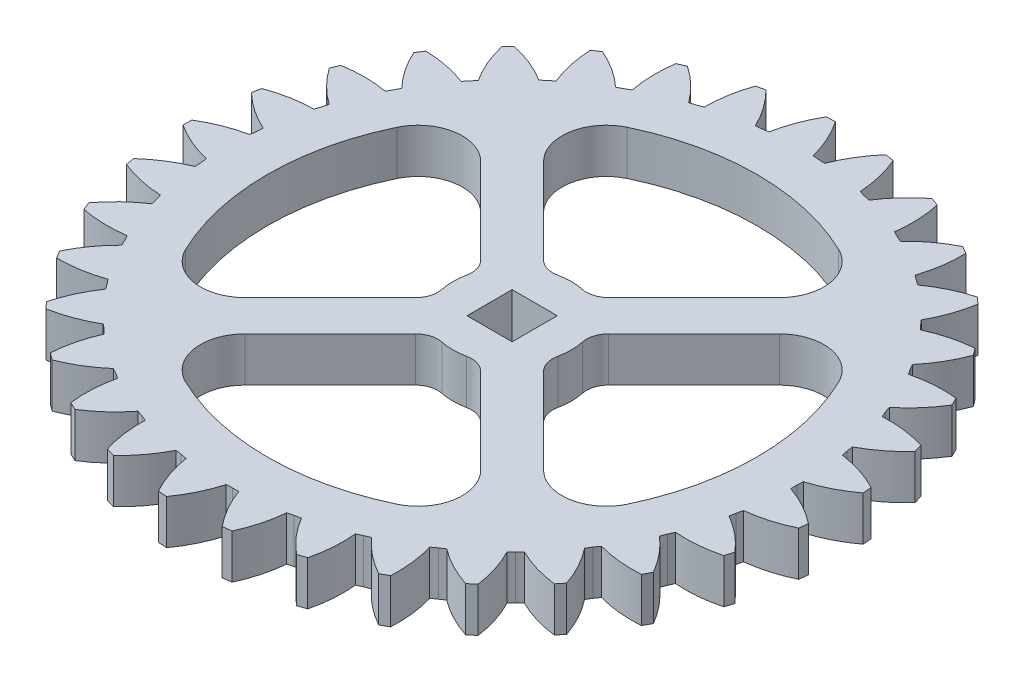
SolidWorks part; units mm, degrees
ref_plane "Front Plane" through (0, 0, 0) normal (0, 0, 1) x (1, 0, 0)
ref_plane "Top Plane" through (0, 0, 0) normal (0, 1, 0) x (1, 0, 0)
ref_plane "Right Plane" through (0, 0, 0) normal (1, 0, 0) x (0, 0, -1)
ref_axis "Axis1" through (0, -1.7463, 0) along (0, 1, 0)
sketch "Sketch1" plane through (0, 0, 0) normal (0, 1, 0) x (1, 0, 0)
  circle A0 centre (0, 0) radius 21.0039 construction
  circle A1 centre (0, 0) radius 21.0039
sketch "Sketch3" plane through (0, 0, 0) normal (0, 1, 0) x (1, 0, 0)
  line L0 (19.5384, 0) -> (19.5462, 0.1213)
  line L1 (19.5462, 0.1213) -> (19.5989, 0.1361)
  line L2 (19.5989, 0.1361) -> (19.6534, 0.1521)
  line L3 (19.6534, 0.1521) -> (19.7098, 0.1692)
  line L4 (19.7098, 0.1692) -> (19.768, 0.1876)
  line L5 (19.768, 0.1876) -> (19.8281, 0.2073)
  line L6 (19.8281, 0.2073) -> (19.8899, 0.2282)
  line L7 (19.8899, 0.2282) -> (19.9535, 0.2506)
  line L8 (19.9535, 0.2506) -> (20.0188, 0.2743)
  line L9 (20.0188, 0.2743) -> (20.0859, 0.2994)
  line L10 (20.0859, 0.2994) -> (20.1547, 0.326)
  line L11 (20.1547, 0.326) -> (20.2251, 0.3541)
  line L12 (20.2251, 0.3541) -> (20.2972, 0.3838)
  line L13 (20.2972, 0.3838) -> (20.3709, 0.4151)
  line L14 (20.3709, 0.4151) -> (20.4462, 0.448)
  line L15 (20.4462, 0.448) -> (20.5231, 0.4825)
  line L16 (20.5231, 0.4825) -> (20.6015, 0.5187)
  line L17 (20.6015, 0.5187) -> (20.6815, 0.5567)
  line L18 (20.6815, 0.5567) -> (20.763, 0.5964)
  line L19 (20.763, 0.5964) -> (20.8459, 0.638)
  line L20 (20.8459, 0.638) -> (20.9302, 0.6814)
  line L21 (20.9302, 0.6814) -> (21.016, 0.7266)
  line L22 (21.016, 0.7266) -> (21.1031, 0.7738)
  line L23 (21.1031, 0.7738) -> (21.1916, 0.8229)
  line L24 (21.1916, 0.8229) -> (21.2814, 0.874)
  line L25 (21.2814, 0.874) -> (21.3724, 0.9271)
  line L26 (21.3724, 0.9271) -> (21.4647, 0.9823)
  line L27 (21.4647, 0.9823) -> (21.5583, 1.0395)
  line L28 (21.5583, 1.0395) -> (21.6529, 1.0988)
  line L29 (21.6529, 1.0988) -> (21.7488, 1.1603)
  line L30 (21.7488, 1.1603) -> (21.8457, 1.2239)
  line L31 (21.8457, 1.2239) -> (21.9438, 1.2898)
  line L32 (21.9438, 1.2898) -> (22.0428, 1.3578)
  line L33 (22.0428, 1.3578) -> (22.1429, 1.4282)
  line L34 (22.1429, 1.4282) -> (22.1933, 1.4642)
  line L35 (22.1933, 1.4642) -> (22.2186, 1.4824)
  line L36 (22.2186, 1.4824) -> (22.2249, 1.487)
  line L37 (22.2249, 1.487) -> (22.2251, 1.4871)
  line L38 (22.2251, 1.4871) -> (22.2253, 1.4873)
  line L39 (22.2253, 1.4873) -> (22.1778, 2.079)
  line L40 (22.1778, 2.079) -> (22.1776, 2.0791)
  line L41 (22.1776, 2.0791) -> (22.1774, 2.0792)
  line L42 (22.1774, 2.0792) -> (22.1704, 2.0827)
  line L43 (22.1704, 2.0827) -> (22.1425, 2.0967)
  line L44 (22.1425, 2.0967) -> (22.087, 2.1242)
  line L45 (22.087, 2.1242) -> (21.977, 2.1776)
  line L46 (21.977, 2.1776) -> (21.8683, 2.229)
  line L47 (21.8683, 2.229) -> (21.7611, 2.2783)
  line L48 (21.7611, 2.2783) -> (21.6552, 2.3257)
  line L49 (21.6552, 2.3257) -> (21.5508, 2.3711)
  line L50 (21.5508, 2.3711) -> (21.4478, 2.4145)
  line L51 (21.4478, 2.4145) -> (21.3464, 2.4561)
  line L52 (21.3464, 2.4561) -> (21.2464, 2.4958)
  line L53 (21.2464, 2.4958) -> (21.1481, 2.5337)
  line L54 (21.1481, 2.5337) -> (21.0513, 2.5698)
  line L55 (21.0513, 2.5698) -> (20.9561, 2.6042)
  line L56 (20.9561, 2.6042) -> (20.8626, 2.6368)
  line L57 (20.8626, 2.6368) -> (20.7707, 2.6678)
  line L58 (20.7707, 2.6678) -> (20.6805, 2.6972)
  line L59 (20.6805, 2.6972) -> (20.592, 2.725)
  line L60 (20.592, 2.725) -> (20.5053, 2.7512)
  line L61 (20.5053, 2.7512) -> (20.4203, 2.7759)
  line L62 (20.4203, 2.7759) -> (20.3371, 2.7992)
  line L63 (20.3371, 2.7992) -> (20.2556, 2.821)
  line L64 (20.2556, 2.821) -> (20.176, 2.8414)
  line L65 (20.176, 2.8414) -> (20.0983, 2.8605)
  line L66 (20.0983, 2.8605) -> (20.0224, 2.8783)
  line L67 (20.0224, 2.8783) -> (19.9483, 2.8948)
  line L68 (19.9483, 2.8948) -> (19.8762, 2.9101)
  line L69 (19.8762, 2.9101) -> (19.806, 2.9243)
  line L70 (19.806, 2.9243) -> (19.7377, 2.9372)
  line L71 (19.7377, 2.9372) -> (19.6714, 2.9491)
  line L72 (19.6714, 2.9491) -> (19.607, 2.96)
  line L73 (19.607, 2.96) -> (19.5446, 2.9698)
  line L74 (19.5446, 2.9698) -> (19.4842, 2.9786)
  line L75 (19.4842, 2.9786) -> (19.4258, 2.9866)
  line L76 (19.4258, 2.9866) -> (19.3694, 2.9936)
  line L77 (19.3694, 2.9936) -> (19.315, 2.9998)
  line L78 (19.315, 2.9998) -> (19.2879, 3.1183)
  line L79 (19.2879, 3.1183) -> (19.1853, 3.6977)
  line L80 (19.1853, 3.6977) -> (19.17, 3.8182)
  line L81 (19.17, 3.8182) -> (19.2189, 3.8428)
  line L82 (19.2189, 3.8428) -> (19.2695, 3.8688)
  line L83 (19.2695, 3.8688) -> (19.3216, 3.8963)
  line L84 (19.3216, 3.8963) -> (19.3753, 3.9253)
  line L85 (19.3753, 3.9253) -> (19.4305, 3.956)
  line L86 (19.4305, 3.956) -> (19.4873, 3.9883)
  line L87 (19.4873, 3.9883) -> (19.5455, 4.0223)
  line L88 (19.5455, 4.0223) -> (19.6052, 4.0579)
  line L89 (19.6052, 4.0579) -> (19.6663, 4.0953)
  line L90 (19.6663, 4.0953) -> (19.7287, 4.1344)
  line L91 (19.7287, 4.1344) -> (19.7926, 4.1754)
  line L92 (19.7926, 4.1754) -> (19.8578, 4.2182)
  line L93 (19.8578, 4.2182) -> (19.9242, 4.2628)
  line L94 (19.9242, 4.2628) -> (19.992, 4.3093)
  line L95 (19.992, 4.3093) -> (20.0609, 4.3578)
  line L96 (20.0609, 4.3578) -> (20.1311, 4.4082)
  line L97 (20.1311, 4.4082) -> (20.2024, 4.4606)
  line L98 (20.2024, 4.4606) -> (20.2749, 4.5151)
  line L99 (20.2749, 4.5151) -> (20.3484, 4.5716)
  line L100 (20.3484, 4.5716) -> (20.423, 4.6301)
  line L101 (20.423, 4.6301) -> (20.4987, 4.6908)
  line L102 (20.4987, 4.6908) -> (20.5753, 4.7536)
  line L103 (20.5753, 4.7536) -> (20.6529, 4.8186)
  line L104 (20.6529, 4.8186) -> (20.7314, 4.8857)
  line L105 (20.7314, 4.8857) -> (20.8107, 4.9551)
  line L106 (20.8107, 4.9551) -> (20.8909, 5.0267)
  line L107 (20.8909, 5.0267) -> (20.9719, 5.1006)
  line L108 (20.9719, 5.1006) -> (21.0537, 5.1768)
  line L109 (21.0537, 5.1768) -> (21.1362, 5.2553)
  line L110 (21.1362, 5.2553) -> (21.2193, 5.3361)
  line L111 (21.2193, 5.3361) -> (21.3031, 5.4193)
  line L112 (21.3031, 5.4193) -> (21.3875, 5.5049)
  line L113 (21.3875, 5.5049) -> (21.4725, 5.5929)
  line L114 (21.4725, 5.5929) -> (21.5152, 5.6378)
  line L115 (21.5152, 5.6378) -> (21.5365, 5.6605)
  line L116 (21.5365, 5.6605) -> (21.5419, 5.6662)
  line L117 (21.5419, 5.6662) -> (21.5421, 5.6664)
  line L118 (21.5421, 5.6664) -> (21.5422, 5.6665)
  line L119 (21.5422, 5.6665) -> (21.3835, 6.2386)
  line L120 (21.3835, 6.2386) -> (21.3833, 6.2386)
  line L121 (21.3833, 6.2386) -> (21.3831, 6.2387)
  line L122 (21.3831, 6.2387) -> (21.3756, 6.2408)
  line L123 (21.3756, 6.2408) -> (21.3456, 6.2493)
  line L124 (21.3456, 6.2493) -> (21.2859, 6.2658)
  line L125 (21.2859, 6.2658) -> (21.1677, 6.2974)
  line L126 (21.1677, 6.2974) -> (21.0513, 6.3273)
  line L127 (21.0513, 6.3273) -> (20.9366, 6.3555)
  line L128 (20.9366, 6.3555) -> (20.8237, 6.3819)
  line L129 (20.8237, 6.3819) -> (20.7126, 6.4067)
  line L130 (20.7126, 6.4067) -> (20.6033, 6.4299)
  line L131 (20.6033, 6.4299) -> (20.4958, 6.4515)
  line L132 (20.4958, 6.4515) -> (20.3901, 6.4716)
  line L133 (20.3901, 6.4716) -> (20.2864, 6.4902)
  line L134 (20.2864, 6.4902) -> (20.1845, 6.5074)
  line L135 (20.1845, 6.5074) -> (20.0846, 6.5231)
  line L136 (20.0846, 6.5231) -> (19.9865, 6.5375)
  line L137 (19.9865, 6.5375) -> (19.8904, 6.5505)
  line L138 (19.8904, 6.5505) -> (19.7963, 6.5623)
  line L139 (19.7963, 6.5623) -> (19.7042, 6.5728)
  line L140 (19.7042, 6.5728) -> (19.614, 6.5821)
  line L141 (19.614, 6.5821) -> (19.5259, 6.5903)
  line L142 (19.5259, 6.5903) -> (19.4398, 6.5974)
  line L143 (19.4398, 6.5974) -> (19.3557, 6.6034)
  line L144 (19.3557, 6.6034) -> (19.2737, 6.6084)
  line L145 (19.2737, 6.6084) -> (19.1937, 6.6125)
  line L146 (19.1937, 6.6125) -> (19.1158, 6.6156)
  line L147 (19.1158, 6.6156) -> (19.04, 6.6178)
  line L148 (19.04, 6.6178) -> (18.9663, 6.6191)
  line L149 (18.9663, 6.6191) -> (18.8947, 6.6197)
  line L150 (18.8947, 6.6197) -> (18.8252, 6.6195)
  line L151 (18.8252, 6.6195) -> (18.7578, 6.6187)
  line L152 (18.7578, 6.6187) -> (18.6925, 6.6171)
  line L153 (18.6925, 6.6171) -> (18.6294, 6.6149)
  line L154 (18.6294, 6.6149) -> (18.5684, 6.6122)
  line L155 (18.5684, 6.6122) -> (18.5095, 6.6089)
  line L156 (18.5095, 6.6089) -> (18.4528, 6.6052)
  line L157 (18.4528, 6.6052) -> (18.3982, 6.601)
  line L158 (18.3982, 6.601) -> (18.3492, 6.7122)
  line L159 (18.3492, 6.7122) -> (18.1388, 7.2617)
  line L160 (18.1388, 7.2617) -> (18.101, 7.3772)
  line L161 (18.101, 7.3772) -> (18.1444, 7.4105)
  line L162 (18.1444, 7.4105) -> (18.1891, 7.4456)
  line L163 (18.1891, 7.4456) -> (18.2351, 7.4825)
  line L164 (18.2351, 7.4825) -> (18.2823, 7.5212)
  line L165 (18.2823, 7.5212) -> (18.3307, 7.5618)
  line L166 (18.3307, 7.5618) -> (18.3803, 7.6042)
  line L167 (18.3803, 7.6042) -> (18.4311, 7.6486)
  line L168 (18.4311, 7.6486) -> (18.4829, 7.6949)
  line L169 (18.4829, 7.6949) -> (18.5358, 7.7431)
  line L170 (18.5358, 7.7431) -> (18.5898, 7.7934)
  line L171 (18.5898, 7.7934) -> (18.6447, 7.8457)
  line L172 (18.6447, 7.8457) -> (18.7006, 7.9)
  line L173 (18.7006, 7.9) -> (18.7574, 7.9564)
  line L174 (18.7574, 7.9564) -> (18.8151, 8.015)
  line L175 (18.8151, 8.015) -> (18.8737, 8.0756)
  line L176 (18.8737, 8.0756) -> (18.933, 8.1384)
  line L177 (18.933, 8.1384) -> (18.9931, 8.2034)
  line L178 (18.9931, 8.2034) -> (19.054, 8.2705)
  line L179 (19.054, 8.2705) -> (19.1155, 8.3399)
  line L180 (19.1155, 8.3399) -> (19.1777, 8.4115)
  line L181 (19.1777, 8.4115) -> (19.2405, 8.4854)
  line L182 (19.2405, 8.4854) -> (19.3039, 8.5616)
  line L183 (19.3039, 8.5616) -> (19.3677, 8.6401)
  line L184 (19.3677, 8.6401) -> (19.4321, 8.7209)
  line L185 (19.4321, 8.7209) -> (19.4969, 8.804)
  line L186 (19.4969, 8.804) -> (19.5621, 8.8895)
  line L187 (19.5621, 8.8895) -> (19.6276, 8.9774)
  line L188 (19.6276, 8.9774) -> (19.6935, 9.0677)
  line L189 (19.6935, 9.0677) -> (19.7596, 9.1604)
  line L190 (19.7596, 9.1604) -> (19.826, 9.2555)
  line L191 (19.826, 9.2555) -> (19.8925, 9.353)
  line L192 (19.8925, 9.353) -> (19.9592, 9.4531)
  line L193 (19.9592, 9.4531) -> (20.026, 9.5555)
  line L194 (20.026, 9.5555) -> (20.0594, 9.6077)
  line L195 (20.0594, 9.6077) -> (20.0761, 9.634)
  line L196 (20.0761, 9.634) -> (20.0803, 9.6406)
  line L197 (20.0803, 9.6406) -> (20.0804, 9.6408)
  line L198 (20.0804, 9.6408) -> (20.0805, 9.641)
  line L199 (20.0805, 9.641) -> (19.8165, 10.1727)
  line L200 (19.8165, 10.1727) -> (19.8162, 10.1727)
  line L201 (19.8162, 10.1727) -> (19.816, 10.1727)
  line L202 (19.816, 10.1727) -> (19.8082, 10.1734)
  line L203 (19.8082, 10.1734) -> (19.7772, 10.176)
  line L204 (19.7772, 10.176) -> (19.7154, 10.1809)
  line L205 (19.7154, 10.1809) -> (19.5934, 10.1897)
  line L206 (19.5934, 10.1897) -> (19.4734, 10.197)
  line L207 (19.4734, 10.197) -> (19.3555, 10.2029)
  line L208 (19.3555, 10.2029) -> (19.2396, 10.2075)
  line L209 (19.2396, 10.2075) -> (19.1258, 10.2108)
  line L210 (19.1258, 10.2108) -> (19.0141, 10.2129)
  line L211 (19.0141, 10.2129) -> (18.9044, 10.2138)
  line L212 (18.9044, 10.2138) -> (18.7969, 10.2135)
  line L213 (18.7969, 10.2135) -> (18.6915, 10.2121)
  line L214 (18.6915, 10.2121) -> (18.5882, 10.2097)
  line L215 (18.5882, 10.2097) -> (18.4871, 10.2062)
  line L216 (18.4871, 10.2062) -> (18.3881, 10.2018)
  line L217 (18.3881, 10.2018) -> (18.2913, 10.1964)
  line L218 (18.2913, 10.1964) -> (18.1967, 10.1902)
  line L219 (18.1967, 10.1902) -> (18.1042, 10.1831)
  line L220 (18.1042, 10.1831) -> (18.0139, 10.1752)
  line L221 (18.0139, 10.1752) -> (17.9258, 10.1665)
  line L222 (17.9258, 10.1665) -> (17.8399, 10.1572)
  line L223 (17.8399, 10.1572) -> (17.7562, 10.1472)
  line L224 (17.7562, 10.1472) -> (17.6747, 10.1366)
  line L225 (17.6747, 10.1366) -> (17.5954, 10.1254)
  line L226 (17.5954, 10.1254) -> (17.5184, 10.1137)
  line L227 (17.5184, 10.1137) -> (17.4435, 10.1015)
  line L228 (17.4435, 10.1015) -> (17.3709, 10.0889)
  line L229 (17.3709, 10.0889) -> (17.3004, 10.0759)
  line L230 (17.3004, 10.0759) -> (17.2322, 10.0626)
  line L231 (17.2322, 10.0626) -> (17.1662, 10.049)
  line L232 (17.1662, 10.049) -> (17.1024, 10.0351)
  line L233 (17.1024, 10.0351) -> (17.0408, 10.021)
  line L234 (17.0408, 10.021) -> (16.9814, 10.0068)
  line L235 (16.9814, 10.0068) -> (16.9243, 9.9925)
  line L236 (16.9243, 9.9925) -> (16.8693, 9.978)
  line L237 (16.8693, 9.978) -> (16.8165, 9.9636)
  line L238 (16.8165, 9.9636) -> (16.7473, 10.0635)
  line L239 (16.7473, 10.0635) -> (16.4367, 10.5632)
  line L240 (16.4367, 10.5632) -> (16.3777, 10.6695)
  line L241 (16.3777, 10.6695) -> (16.414, 10.7105)
  line L242 (16.414, 10.7105) -> (16.4513, 10.7534)
  line L243 (16.4513, 10.7534) -> (16.4895, 10.7983)
  line L244 (16.4895, 10.7983) -> (16.5285, 10.8452)
  line L245 (16.5285, 10.8452) -> (16.5684, 10.8942)
  line L246 (16.5684, 10.8942) -> (16.6091, 10.9453)
  line L247 (16.6091, 10.9453) -> (16.6505, 10.9985)
  line L248 (16.6505, 10.9985) -> (16.6926, 11.0537)
  line L249 (16.6926, 11.0537) -> (16.7355, 11.1111)
  line L250 (16.7355, 11.1111) -> (16.7789, 11.1707)
  line L251 (16.7789, 11.1707) -> (16.823, 11.2324)
  line L252 (16.823, 11.2324) -> (16.8676, 11.2964)
  line L253 (16.8676, 11.2964) -> (16.9127, 11.3625)
  line L254 (16.9127, 11.3625) -> (16.9583, 11.4309)
  line L255 (16.9583, 11.4309) -> (17.0043, 11.5015)
  line L256 (17.0043, 11.5015) -> (17.0507, 11.5744)
  line L257 (17.0507, 11.5744) -> (17.0974, 11.6496)
  line L258 (17.0974, 11.6496) -> (17.1445, 11.7271)
  line L259 (17.1445, 11.7271) -> (17.1917, 11.8068)
  line L260 (17.1917, 11.8068) -> (17.2393, 11.8889)
  line L261 (17.2393, 11.8889) -> (17.2869, 11.9734)
  line L262 (17.2869, 11.9734) -> (17.3347, 12.0602)
  line L263 (17.3347, 12.0602) -> (17.3826, 12.1493)
  line L264 (17.3826, 12.1493) -> (17.4305, 12.2408)
  line L265 (17.4305, 12.2408) -> (17.4784, 12.3347)
  line L266 (17.4784, 12.3347) -> (17.5262, 12.431)
  line L267 (17.5262, 12.431) -> (17.574, 12.5297)
  line L268 (17.574, 12.5297) -> (17.6216, 12.6309)
  line L269 (17.6216, 12.6309) -> (17.669, 12.7344)
  line L270 (17.669, 12.7344) -> (17.7161, 12.8403)
  line L271 (17.7161, 12.8403) -> (17.763, 12.9487)
  line L272 (17.763, 12.9487) -> (17.8095, 13.0595)
  line L273 (17.8095, 13.0595) -> (17.8557, 13.1728)
  line L274 (17.8557, 13.1728) -> (17.8786, 13.2304)
  line L275 (17.8786, 13.2304) -> (17.89, 13.2594)
  line L276 (17.89, 13.2594) -> (17.8929, 13.2666)
  line L277 (17.8929, 13.2666) -> (17.893, 13.2669)
  line L278 (17.893, 13.2669) -> (17.893, 13.2671)
  line L279 (17.893, 13.2671) -> (17.5332, 13.7392)
  line L280 (17.5332, 13.7392) -> (17.5329, 13.7391)
  line L281 (17.5329, 13.7391) -> (17.5327, 13.7391)
  line L282 (17.5327, 13.7391) -> (17.5249, 13.7383)
  line L283 (17.5249, 13.7383) -> (17.4939, 13.735)
  line L284 (17.4939, 13.735) -> (17.4324, 13.7281)
  line L285 (17.4324, 13.7281) -> (17.3109, 13.7136)
  line L286 (17.3109, 13.7136) -> (17.1917, 13.6981)
  line L287 (17.1917, 13.6981) -> (17.0748, 13.6816)
  line L288 (17.0748, 13.6816) -> (16.9601, 13.6642)
  line L289 (16.9601, 13.6642) -> (16.8478, 13.6459)
  line L290 (16.8478, 13.6459) -> (16.7376, 13.6268)
  line L291 (16.7376, 13.6268) -> (16.6298, 13.6069)
  line L292 (16.6298, 13.6069) -> (16.5243, 13.5863)
  line L293 (16.5243, 13.5863) -> (16.4211, 13.565)
  line L294 (16.4211, 13.565) -> (16.3201, 13.543)
  line L295 (16.3201, 13.543) -> (16.2215, 13.5205)
  line L296 (16.2215, 13.5205) -> (16.1251, 13.4974)
  line L297 (16.1251, 13.4974) -> (16.0311, 13.4738)
  line L298 (16.0311, 13.4738) -> (15.9393, 13.4497)
  line L299 (15.9393, 13.4497) -> (15.8499, 13.4253)
  line L300 (15.8499, 13.4253) -> (15.7627, 13.4004)
  line L301 (15.7627, 13.4004) -> (15.6778, 13.3753)
  line L302 (15.6778, 13.3753) -> (15.5953, 13.3499)
  line L303 (15.5953, 13.3499) -> (15.515, 13.3242)
  line L304 (15.515, 13.3242) -> (15.437, 13.2984)
  line L305 (15.437, 13.2984) -> (15.3612, 13.2724)
  line L306 (15.3612, 13.2724) -> (15.2878, 13.2463)
  line L307 (15.2878, 13.2463) -> (15.2165, 13.2202)
  line L308 (15.2165, 13.2202) -> (15.1476, 13.1941)
  line L309 (15.1476, 13.1941) -> (15.0809, 13.168)
  line L310 (15.0809, 13.168) -> (15.0164, 13.142)
  line L311 (15.0164, 13.142) -> (14.9542, 13.1161)
  line L312 (14.9542, 13.1161) -> (14.8942, 13.0904)
  line L313 (14.8942, 13.0904) -> (14.8364, 13.0649)
  line L314 (14.8364, 13.0649) -> (14.7808, 13.0397)
  line L315 (14.7808, 13.0397) -> (14.7273, 13.0148)
  line L316 (14.7273, 13.0148) -> (14.6761, 12.9903)
  line L317 (14.6761, 12.9903) -> (14.627, 12.9661)
  line L318 (14.627, 12.9661) -> (14.5401, 13.0511)
  line L319 (14.5401, 13.0511) -> (14.1406, 13.483)
  line L320 (14.1406, 13.483) -> (14.0625, 13.5762)
  line L321 (14.0625, 13.5762) -> (14.0904, 13.6233)
  line L322 (14.0904, 13.6233) -> (14.1189, 13.6725)
  line L323 (14.1189, 13.6725) -> (14.1479, 13.7238)
  line L324 (14.1479, 13.7238) -> (14.1773, 13.7773)
  line L325 (14.1773, 13.7773) -> (14.2072, 13.833)
  line L326 (14.2072, 13.833) -> (14.2375, 13.8908)
  line L327 (14.2375, 13.8908) -> (14.2681, 13.9508)
  line L328 (14.2681, 13.9508) -> (14.299, 14.0131)
  line L329 (14.299, 14.0131) -> (14.3302, 14.0776)
  line L330 (14.3302, 14.0776) -> (14.3616, 14.1443)
  line L331 (14.3616, 14.1443) -> (14.3932, 14.2132)
  line L332 (14.3932, 14.2132) -> (14.4249, 14.2844)
  line L333 (14.4249, 14.2844) -> (14.4567, 14.3579)
  line L334 (14.4567, 14.3579) -> (14.4885, 14.4337)
  line L335 (14.4885, 14.4337) -> (14.5203, 14.5118)
  line L336 (14.5203, 14.5118) -> (14.5521, 14.5921)
  line L337 (14.5521, 14.5921) -> (14.5837, 14.6748)
  line L338 (14.5837, 14.6748) -> (14.6153, 14.7598)
  line L339 (14.6153, 14.7598) -> (14.6466, 14.847)
  line L340 (14.6466, 14.847) -> (14.6777, 14.9366)
  line L341 (14.6777, 14.9366) -> (14.7085, 15.0286)
  line L342 (14.7085, 15.0286) -> (14.7391, 15.1228)
  line L343 (14.7391, 15.1228) -> (14.7692, 15.2194)
  line L344 (14.7692, 15.2194) -> (14.7989, 15.3184)
  line L345 (14.7989, 15.3184) -> (14.8282, 15.4196)
  line L346 (14.8282, 15.4196) -> (14.8569, 15.5233)
  line L347 (14.8569, 15.5233) -> (14.8851, 15.6292)
  line L348 (14.8851, 15.6292) -> (14.9127, 15.7375)
  line L349 (14.9127, 15.7375) -> (14.9397, 15.8481)
  line L350 (14.9397, 15.8481) -> (14.9659, 15.9611)
  line L351 (14.9659, 15.9611) -> (14.9914, 16.0764)
  line L352 (14.9914, 16.0764) -> (15.0161, 16.194)
  line L353 (15.0161, 16.194) -> (15.04, 16.314)
  line L354 (15.04, 16.314) -> (15.0517, 16.3748)
  line L355 (15.0517, 16.3748) -> (15.0574, 16.4055)
  line L356 (15.0574, 16.4055) -> (15.0588, 16.4131)
  line L357 (15.0588, 16.4131) -> (15.0589, 16.4134)
  line L358 (15.0589, 16.4134) -> (15.0589, 16.4136)
  line L359 (15.0589, 16.4136) -> (14.6162, 16.809)
  line L360 (14.6162, 16.809) -> (14.6159, 16.809)
  line L361 (14.6159, 16.809) -> (14.6157, 16.8089)
  line L362 (14.6157, 16.8089) -> (14.6082, 16.8066)
  line L363 (14.6082, 16.8066) -> (14.5784, 16.7975)
  line L364 (14.5784, 16.7975) -> (14.5193, 16.7791)
  line L365 (14.5193, 16.7791) -> (14.4028, 16.7419)
  line L366 (14.4028, 16.7419) -> (14.2887, 16.7041)
  line L367 (14.2887, 16.7041) -> (14.177, 16.6658)
  line L368 (14.177, 16.6658) -> (14.0677, 16.627)
  line L369 (14.0677, 16.627) -> (13.9608, 16.5878)
  line L370 (13.9608, 16.5878) -> (13.8563, 16.5482)
  line L371 (13.8563, 16.5482) -> (13.7542, 16.5082)
  line L372 (13.7542, 16.5082) -> (13.6545, 16.468)
  line L373 (13.6545, 16.468) -> (13.5571, 16.4276)
  line L374 (13.5571, 16.4276) -> (13.4622, 16.3869)
  line L375 (13.4622, 16.3869) -> (13.3696, 16.3461)
  line L376 (13.3696, 16.3461) -> (13.2793, 16.3052)
  line L377 (13.2793, 16.3052) -> (13.1914, 16.2642)
  line L378 (13.1914, 16.2642) -> (13.1059, 16.2232)
  line L379 (13.1059, 16.2232) -> (13.0227, 16.1823)
  line L380 (13.0227, 16.1823) -> (12.9418, 16.1414)
  line L381 (12.9418, 16.1414) -> (12.8632, 16.1006)
  line L382 (12.8632, 16.1006) -> (12.787, 16.06)
  line L383 (12.787, 16.06) -> (12.713, 16.0196)
  line L384 (12.713, 16.0196) -> (12.6413, 15.9795)
  line L385 (12.6413, 15.9795) -> (12.5718, 15.9397)
  line L386 (12.5718, 15.9397) -> (12.5046, 15.9002)
  line L387 (12.5046, 15.9002) -> (12.4396, 15.861)
  line L388 (12.4396, 15.861) -> (12.3769, 15.8223)
  line L389 (12.3769, 15.8223) -> (12.3163, 15.7841)
  line L390 (12.3163, 15.7841) -> (12.2579, 15.7464)
  line L391 (12.2579, 15.7464) -> (12.2017, 15.7092)
  line L392 (12.2017, 15.7092) -> (12.1477, 15.6726)
  line L393 (12.1477, 15.6726) -> (12.0957, 15.6366)
  line L394 (12.0957, 15.6366) -> (12.0459, 15.6014)
  line L395 (12.0459, 15.6014) -> (11.9981, 15.5668)
  line L396 (11.9981, 15.5668) -> (11.9524, 15.533)
  line L397 (11.9524, 15.533) -> (11.9088, 15.5)
  line L398 (11.9088, 15.5) -> (11.8074, 15.567)
  line L399 (11.8074, 15.567) -> (11.3334, 15.9155)
  line L400 (11.3334, 15.9155) -> (11.2391, 15.9922)
  line L401 (11.2391, 15.9922) -> (11.2576, 16.0437)
  line L402 (11.2576, 16.0437) -> (11.2762, 16.0974)
  line L403 (11.2762, 16.0974) -> (11.295, 16.1533)
  line L404 (11.295, 16.1533) -> (11.3138, 16.2114)
  line L405 (11.3138, 16.2114) -> (11.3326, 16.2717)
  line L406 (11.3326, 16.2717) -> (11.3514, 16.3342)
  line L407 (11.3514, 16.3342) -> (11.3701, 16.399)
  line L408 (11.3701, 16.399) -> (11.3887, 16.466)
  line L409 (11.3887, 16.466) -> (11.4071, 16.5352)
  line L410 (11.4071, 16.5352) -> (11.4253, 16.6066)
  line L411 (11.4253, 16.6066) -> (11.4432, 16.6803)
  line L412 (11.4432, 16.6803) -> (11.4609, 16.7562)
  line L413 (11.4609, 16.7562) -> (11.4782, 16.8344)
  line L414 (11.4782, 16.8344) -> (11.4951, 16.9148)
  line L415 (11.4951, 16.9148) -> (11.5115, 16.9975)
  line L416 (11.5115, 16.9975) -> (11.5275, 17.0824)
  line L417 (11.5275, 17.0824) -> (11.543, 17.1696)
  line L418 (11.543, 17.1696) -> (11.5579, 17.259)
  line L419 (11.5579, 17.259) -> (11.5721, 17.3506)
  line L420 (11.5721, 17.3506) -> (11.5857, 17.4445)
  line L421 (11.5857, 17.4445) -> (11.5986, 17.5406)
  line L422 (11.5986, 17.5406) -> (11.6107, 17.6389)
  line L423 (11.6107, 17.6389) -> (11.622, 17.7395)
  line L424 (11.622, 17.7395) -> (11.6325, 17.8423)
  line L425 (11.6325, 17.8423) -> (11.642, 17.9472)
  line L426 (11.642, 17.9472) -> (11.6506, 18.0544)
  line L427 (11.6506, 18.0544) -> (11.6583, 18.1638)
  line L428 (11.6583, 18.1638) -> (11.6649, 18.2753)
  line L429 (11.6649, 18.2753) -> (11.6704, 18.3891)
  line L430 (11.6704, 18.3891) -> (11.6748, 18.505)
  line L431 (11.6748, 18.505) -> (11.678, 18.623)
  line L432 (11.678, 18.623) -> (11.6801, 18.7432)
  line L433 (11.6801, 18.7432) -> (11.6808, 18.8655)
  line L434 (11.6808, 18.8655) -> (11.6807, 18.9274)
  line L435 (11.6807, 18.9274) -> (11.6805, 18.9586)
  line L436 (11.6805, 18.9586) -> (11.6805, 18.9664)
  line L437 (11.6805, 18.9664) -> (11.6805, 18.9667)
  line L438 (11.6805, 18.9667) -> (11.6805, 18.9669)
  line L439 (11.6805, 18.9669) -> (11.1709, 19.2714)
  line L440 (11.1709, 19.2714) -> (11.1707, 19.2713)
  line L441 (11.1707, 19.2713) -> (11.1705, 19.2712)
  line L442 (11.1705, 19.2712) -> (11.1636, 19.2675)
  line L443 (11.1636, 19.2675) -> (11.136, 19.2529)
  line L444 (11.136, 19.2529) -> (11.0814, 19.2237)
  line L445 (11.0814, 19.2237) -> (10.9741, 19.1651)
  line L446 (10.9741, 19.1651) -> (10.8692, 19.1064)
  line L447 (10.8692, 19.1064) -> (10.7668, 19.0476)
  line L448 (10.7668, 19.0476) -> (10.6668, 18.9888)
  line L449 (10.6668, 18.9888) -> (10.5692, 18.9301)
  line L450 (10.5692, 18.9301) -> (10.4741, 18.8714)
  line L451 (10.4741, 18.8714) -> (10.3814, 18.8129)
  line L452 (10.3814, 18.8129) -> (10.2911, 18.7545)
  line L453 (10.2911, 18.7545) -> (10.2032, 18.6964)
  line L454 (10.2032, 18.6964) -> (10.1176, 18.6385)
  line L455 (10.1176, 18.6385) -> (10.0344, 18.5809)
  line L456 (10.0344, 18.5809) -> (9.9536, 18.5237)
  line L457 (9.9536, 18.5237) -> (9.875, 18.4668)
  line L458 (9.875, 18.4668) -> (9.7988, 18.4104)
  line L459 (9.7988, 18.4104) -> (9.7248, 18.3544)
  line L460 (9.7248, 18.3544) -> (9.6532, 18.299)
  line L461 (9.6532, 18.299) -> (9.5837, 18.2441)
  line L462 (9.5837, 18.2441) -> (9.5165, 18.1898)
  line L463 (9.5165, 18.1898) -> (9.4515, 18.1361)
  line L464 (9.4515, 18.1361) -> (9.3887, 18.0831)
  line L465 (9.3887, 18.0831) -> (9.328, 18.0308)
  line L466 (9.328, 18.0308) -> (9.2695, 17.9793)
  line L467 (9.2695, 17.9793) -> (9.2131, 17.9286)
  line L468 (9.2131, 17.9286) -> (9.1588, 17.8787)
  line L469 (9.1588, 17.8787) -> (9.1066, 17.8297)
  line L470 (9.1066, 17.8297) -> (9.0564, 17.7816)
  line L471 (9.0564, 17.7816) -> (9.0082, 17.7345)
  line L472 (9.0082, 17.7345) -> (8.9621, 17.6883)
  line L473 (8.9621, 17.6883) -> (8.9179, 17.6432)
  line L474 (8.9179, 17.6432) -> (8.8756, 17.5991)
  line L475 (8.8756, 17.5991) -> (8.8353, 17.5561)
  line L476 (8.8353, 17.5561) -> (8.7968, 17.5143)
  line L477 (8.7968, 17.5143) -> (8.7602, 17.4736)
  line L478 (8.7602, 17.4736) -> (8.648, 17.5203)
  line L479 (8.648, 17.5203) -> (8.1165, 17.7727)
  line L480 (8.1165, 17.7727) -> (8.0094, 17.8302)
  line L481 (8.0094, 17.8302) -> (8.0179, 17.8843)
  line L482 (8.0179, 17.8843) -> (8.026, 17.9406)
  line L483 (8.026, 17.9406) -> (8.0338, 17.999)
  line L484 (8.0338, 17.999) -> (8.0413, 18.0596)
  line L485 (8.0413, 18.0596) -> (8.0483, 18.1224)
  line L486 (8.0483, 18.1224) -> (8.055, 18.1873)
  line L487 (8.055, 18.1873) -> (8.0611, 18.2544)
  line L488 (8.0611, 18.2544) -> (8.0666, 18.3237)
  line L489 (8.0666, 18.3237) -> (8.0716, 18.3952)
  line L490 (8.0716, 18.3952) -> (8.076, 18.4688)
  line L491 (8.076, 18.4688) -> (8.0797, 18.5445)
  line L492 (8.0797, 18.5445) -> (8.0826, 18.6224)
  line L493 (8.0826, 18.6224) -> (8.0848, 18.7025)
  line L494 (8.0848, 18.7025) -> (8.0862, 18.7846)
  line L495 (8.0862, 18.7846) -> (8.0867, 18.8689)
  line L496 (8.0867, 18.8689) -> (8.0863, 18.9553)
  line L497 (8.0863, 18.9553) -> (8.085, 19.0438)
  line L498 (8.085, 19.0438) -> (8.0827, 19.1344)
  line L499 (8.0827, 19.1344) -> (8.0794, 19.2271)
  line L500 (8.0794, 19.2271) -> (8.0749, 19.3219)
  line L501 (8.0749, 19.3219) -> (8.0694, 19.4187)
  line L502 (8.0694, 19.4187) -> (8.0627, 19.5175)
  line L503 (8.0627, 19.5175) -> (8.0547, 19.6184)
  line L504 (8.0547, 19.6184) -> (8.0456, 19.7213)
  line L505 (8.0456, 19.7213) -> (8.0351, 19.8262)
  line L506 (8.0351, 19.8262) -> (8.0233, 19.9331)
  line L507 (8.0233, 19.9331) -> (8.0101, 20.0419)
  line L508 (8.0101, 20.0419) -> (7.9954, 20.1527)
  line L509 (7.9954, 20.1527) -> (7.9793, 20.2654)
  line L510 (7.9793, 20.2654) -> (7.9617, 20.38)
  line L511 (7.9617, 20.38) -> (7.9426, 20.4965)
  line L512 (7.9426, 20.4965) -> (7.9218, 20.6149)
  line L513 (7.9218, 20.6149) -> (7.8994, 20.7352)
  line L514 (7.8994, 20.7352) -> (7.8876, 20.796)
  line L515 (7.8876, 20.796) -> (7.8815, 20.8266)
  line L516 (7.8815, 20.8266) -> (7.88, 20.8342)
  line L517 (7.88, 20.8342) -> (7.8799, 20.8345)
  line L518 (7.8799, 20.8345) -> (7.8799, 20.8347)
  line L519 (7.8799, 20.8347) -> (7.3219, 21.0372)
  line L520 (7.3219, 21.0372) -> (7.3217, 21.0371)
  line L521 (7.3217, 21.0371) -> (7.3215, 21.037)
  line L522 (7.3215, 21.037) -> (7.3154, 21.0321)
  line L523 (7.3154, 21.0321) -> (7.2912, 21.0125)
  line L524 (7.2912, 21.0125) -> (7.2431, 20.9735)
  line L525 (7.2431, 20.9735) -> (7.1487, 20.8956)
  line L526 (7.1487, 20.8956) -> (7.0569, 20.8181)
  line L527 (7.0569, 20.8181) -> (6.9674, 20.741)
  line L528 (6.9674, 20.741) -> (6.8804, 20.6644)
  line L529 (6.8804, 20.6644) -> (6.7957, 20.5883)
  line L530 (6.7957, 20.5883) -> (6.7134, 20.5126)
  line L531 (6.7134, 20.5126) -> (6.6334, 20.4376)
  line L532 (6.6334, 20.4376) -> (6.5558, 20.3632)
  line L533 (6.5558, 20.3632) -> (6.4805, 20.2895)
  line L534 (6.4805, 20.2895) -> (6.4074, 20.2165)
  line L535 (6.4074, 20.2165) -> (6.3366, 20.1442)
  line L536 (6.3366, 20.1442) -> (6.2681, 20.0726)
  line L537 (6.2681, 20.0726) -> (6.2017, 20.0019)
  line L538 (6.2017, 20.0019) -> (6.1375, 19.9321)
  line L539 (6.1375, 19.9321) -> (6.0755, 19.8632)
  line L540 (6.0755, 19.8632) -> (6.0156, 19.7951)
  line L541 (6.0156, 19.7951) -> (5.9578, 19.7281)
  line L542 (5.9578, 19.7281) -> (5.9021, 19.6621)
  line L543 (5.9021, 19.6621) -> (5.8484, 19.5971)
  line L544 (5.8484, 19.5971) -> (5.7968, 19.5331)
  line L545 (5.7968, 19.5331) -> (5.7471, 19.4703)
  line L546 (5.7471, 19.4703) -> (5.6994, 19.4087)
  line L547 (5.6994, 19.4087) -> (5.6536, 19.3482)
  line L548 (5.6536, 19.3482) -> (5.6097, 19.289)
  line L549 (5.6097, 19.289) -> (5.5677, 19.231)
  line L550 (5.5677, 19.231) -> (5.5275, 19.1742)
  line L551 (5.5275, 19.1742) -> (5.4892, 19.1188)
  line L552 (5.4892, 19.1188) -> (5.4526, 19.0648)
  line L553 (5.4526, 19.0648) -> (5.4177, 19.0121)
  line L554 (5.4177, 19.0121) -> (5.3846, 18.9608)
  line L555 (5.3846, 18.9608) -> (5.3531, 18.911)
  line L556 (5.3531, 18.911) -> (5.3232, 18.8626)
  line L557 (5.3232, 18.8626) -> (5.295, 18.8157)
  line L558 (5.295, 18.8157) -> (5.176, 18.8403)
  line L559 (5.176, 18.8403) -> (4.6063, 18.9876)
  line L560 (4.6063, 18.9876) -> (4.4903, 19.0238)
  line L561 (4.4903, 19.0238) -> (4.4883, 19.0785)
  line L562 (4.4883, 19.0785) -> (4.4857, 19.1353)
  line L563 (4.4857, 19.1353) -> (4.4823, 19.1941)
  line L564 (4.4823, 19.1941) -> (4.4782, 19.255)
  line L565 (4.4782, 19.255) -> (4.4732, 19.318)
  line L566 (4.4732, 19.318) -> (4.4674, 19.383)
  line L567 (4.4674, 19.383) -> (4.4607, 19.4501)
  line L568 (4.4607, 19.4501) -> (4.4531, 19.5192)
  line L569 (4.4531, 19.5192) -> (4.4445, 19.5903)
  line L570 (4.4445, 19.5903) -> (4.4348, 19.6634)
  line L571 (4.4348, 19.6634) -> (4.4241, 19.7385)
  line L572 (4.4241, 19.7385) -> (4.4122, 19.8155)
  line L573 (4.4122, 19.8155) -> (4.3992, 19.8945)
  line L574 (4.3992, 19.8945) -> (4.3851, 19.9755)
  line L575 (4.3851, 19.9755) -> (4.3696, 20.0584)
  line L576 (4.3696, 20.0584) -> (4.3529, 20.1431)
  line L577 (4.3529, 20.1431) -> (4.3348, 20.2298)
  line L578 (4.3348, 20.2298) -> (4.3154, 20.3183)
  line L579 (4.3154, 20.3183) -> (4.2946, 20.4087)
  line L580 (4.2946, 20.4087) -> (4.2723, 20.5009)
  line L581 (4.2723, 20.5009) -> (4.2486, 20.5949)
  line L582 (4.2486, 20.5949) -> (4.2233, 20.6907)
  line L583 (4.2233, 20.6907) -> (4.1964, 20.7882)
  line L584 (4.1964, 20.7882) -> (4.1679, 20.8875)
  line L585 (4.1679, 20.8875) -> (4.1378, 20.9885)
  line L586 (4.1378, 20.9885) -> (4.1059, 21.0912)
  line L587 (4.1059, 21.0912) -> (4.0724, 21.1956)
  line L588 (4.0724, 21.1956) -> (4.037, 21.3016)
  line L589 (4.037, 21.3016) -> (3.9999, 21.4093)
  line L590 (3.9999, 21.4093) -> (3.9609, 21.5185)
  line L591 (3.9609, 21.5185) -> (3.92, 21.6293)
  line L592 (3.92, 21.6293) -> (3.8772, 21.7416)
  line L593 (3.8772, 21.7416) -> (3.8325, 21.8554)
  line L594 (3.8325, 21.8554) -> (3.8094, 21.9129)
  line L595 (3.8094, 21.9129) -> (3.7976, 21.9418)
  line L596 (3.7976, 21.9418) -> (3.7947, 21.949)
  line L597 (3.7947, 21.949) -> (3.7946, 21.9492)
  line L598 (3.7946, 21.9492) -> (3.7945, 21.9494)
  line L599 (3.7945, 21.9494) -> (3.2082, 22.0428)
  line L600 (3.2082, 22.0428) -> (3.2081, 22.0426)
  line L601 (3.2081, 22.0426) -> (3.2079, 22.0424)
  line L602 (3.2079, 22.0424) -> (3.2029, 22.0365)
  line L603 (3.2029, 22.0365) -> (3.1827, 22.0127)
  line L604 (3.1827, 22.0127) -> (3.1429, 21.9652)
  line L605 (3.1429, 21.9652) -> (3.065, 21.8709)
  line L606 (3.065, 21.8709) -> (2.9895, 21.7774)
  line L607 (2.9895, 21.7774) -> (2.9162, 21.6848)
  line L608 (2.9162, 21.6848) -> (2.8453, 21.5931)
  line L609 (2.8453, 21.5931) -> (2.7765, 21.5023)
  line L610 (2.7765, 21.5023) -> (2.71, 21.4125)
  line L611 (2.71, 21.4125) -> (2.6457, 21.3237)
  line L612 (2.6457, 21.3237) -> (2.5836, 21.2359)
  line L613 (2.5836, 21.2359) -> (2.5236, 21.1493)
  line L614 (2.5236, 21.1493) -> (2.4657, 21.0637)
  line L615 (2.4657, 21.0637) -> (2.4098, 20.9793)
  line L616 (2.4098, 20.9793) -> (2.356, 20.8961)
  line L617 (2.356, 20.8961) -> (2.3042, 20.8142)
  line L618 (2.3042, 20.8142) -> (2.2544, 20.7334)
  line L619 (2.2544, 20.7334) -> (2.2066, 20.654)
  line L620 (2.2066, 20.654) -> (2.1606, 20.5759)
  line L621 (2.1606, 20.5759) -> (2.1166, 20.4991)
  line L622 (2.1166, 20.4991) -> (2.0744, 20.4237)
  line L623 (2.0744, 20.4237) -> (2.034, 20.3497)
  line L624 (2.034, 20.3497) -> (1.9953, 20.2772)
  line L625 (1.9953, 20.2772) -> (1.9584, 20.2061)
  line L626 (1.9584, 20.2061) -> (1.9233, 20.1366)
  line L627 (1.9233, 20.1366) -> (1.8898, 20.0685)
  line L628 (1.8898, 20.0685) -> (1.8579, 20.002)
  line L629 (1.8579, 20.002) -> (1.8276, 19.9371)
  line L630 (1.8276, 19.9371) -> (1.7989, 19.8738)
  line L631 (1.7989, 19.8738) -> (1.7717, 19.8122)
  line L632 (1.7717, 19.8122) -> (1.746, 19.7521)
  line L633 (1.746, 19.7521) -> (1.7217, 19.6938)
  line L634 (1.7217, 19.6938) -> (1.6989, 19.6372)
  line L635 (1.6989, 19.6372) -> (1.6774, 19.5823)
  line L636 (1.6774, 19.5823) -> (1.6573, 19.5292)
  line L637 (1.6573, 19.5292) -> (1.6384, 19.4778)
  line L638 (1.6384, 19.4778) -> (1.5169, 19.4794)
  line L639 (1.5169, 19.4794) -> (0.9297, 19.5162)
  line L640 (0.9297, 19.5162) -> (0.8089, 19.5298)
  line L641 (0.8089, 19.5298) -> (0.7966, 19.5832)
  line L642 (0.7966, 19.5832) -> (0.7832, 19.6384)
  line L643 (0.7832, 19.6384) -> (0.7688, 19.6955)
  line L644 (0.7688, 19.6955) -> (0.7532, 19.7546)
  line L645 (0.7532, 19.7546) -> (0.7364, 19.8155)
  line L646 (0.7364, 19.8155) -> (0.7184, 19.8782)
  line L647 (0.7184, 19.8782) -> (0.6992, 19.9428)
  line L648 (0.6992, 19.9428) -> (0.6786, 20.0092)
  line L649 (0.6786, 20.0092) -> (0.6567, 20.0774)
  line L650 (0.6567, 20.0774) -> (0.6333, 20.1473)
  line L651 (0.6333, 20.1473) -> (0.6086, 20.219)
  line L652 (0.6086, 20.219) -> (0.5824, 20.2925)
  line L653 (0.5824, 20.2925) -> (0.5547, 20.3676)
  line L654 (0.5547, 20.3676) -> (0.5254, 20.4444)
  line L655 (0.5254, 20.4444) -> (0.4946, 20.5228)
  line L656 (0.4946, 20.5228) -> (0.4621, 20.6029)
  line L657 (0.4621, 20.6029) -> (0.428, 20.6846)
  line L658 (0.428, 20.6846) -> (0.3922, 20.7678)
  line L659 (0.3922, 20.7678) -> (0.3546, 20.8526)
  line L660 (0.3546, 20.8526) -> (0.3153, 20.9389)
  line L661 (0.3153, 20.9389) -> (0.2742, 21.0268)
  line L662 (0.2742, 21.0268) -> (0.2312, 21.116)
  line L663 (0.2312, 21.116) -> (0.1863, 21.2067)
  line L664 (0.1863, 21.2067) -> (0.1396, 21.2988)
  line L665 (0.1396, 21.2988) -> (0.0909, 21.3923)
  line L666 (0.0909, 21.3923) -> (0.0402, 21.4872)
  line L667 (0.0402, 21.4872) -> (-0.0125, 21.5833)
  line L668 (-0.0125, 21.5833) -> (-0.0673, 21.6807)
  line L669 (-0.0673, 21.6807) -> (-0.1241, 21.7794)
  line L670 (-0.1241, 21.7794) -> (-0.1831, 21.8792)
  line L671 (-0.1831, 21.8792) -> (-0.2442, 21.9803)
  line L672 (-0.2442, 21.9803) -> (-0.3075, 22.0825)
  line L673 (-0.3075, 22.0825) -> (-0.3729, 22.1858)
  line L674 (-0.3729, 22.1858) -> (-0.4065, 22.2378)
  line L675 (-0.4065, 22.2378) -> (-0.4235, 22.264)
  line L676 (-0.4235, 22.264) -> (-0.4278, 22.2705)
  line L677 (-0.4278, 22.2705) -> (-0.4279, 22.2707)
  line L678 (-0.4279, 22.2707) -> (-0.4281, 22.2709)
  line L679 (-0.4281, 22.2709) -> (-1.0214, 22.2516)
  line L680 (-1.0214, 22.2516) -> (-1.0215, 22.2514)
  line L681 (-1.0215, 22.2514) -> (-1.0216, 22.2512)
  line L682 (-1.0216, 22.2512) -> (-1.0254, 22.2444)
  line L683 (-1.0254, 22.2444) -> (-1.0407, 22.2172)
  line L684 (-1.0407, 22.2172) -> (-1.0708, 22.1631)
  line L685 (-1.0708, 22.1631) -> (-1.1294, 22.0557)
  line L686 (-1.1294, 22.0557) -> (-1.1859, 21.9496)
  line L687 (-1.1859, 21.9496) -> (-1.2403, 21.8448)
  line L688 (-1.2403, 21.8448) -> (-1.2927, 21.7413)
  line L689 (-1.2927, 21.7413) -> (-1.343, 21.6392)
  line L690 (-1.343, 21.6392) -> (-1.3913, 21.5384)
  line L691 (-1.3913, 21.5384) -> (-1.4376, 21.439)
  line L692 (-1.4376, 21.439) -> (-1.482, 21.3411)
  line L693 (-1.482, 21.3411) -> (-1.5246, 21.2447)
  line L694 (-1.5246, 21.2447) -> (-1.5652, 21.1497)
  line L695 (-1.5652, 21.1497) -> (-1.6041, 21.0563)
  line L696 (-1.6041, 21.0563) -> (-1.6412, 20.9644)
  line L697 (-1.6412, 20.9644) -> (-1.6765, 20.8741)
  line L698 (-1.6765, 20.8741) -> (-1.7101, 20.7854)
  line L699 (-1.7101, 20.7854) -> (-1.7421, 20.6983)
  line L700 (-1.7421, 20.6983) -> (-1.7724, 20.6129)
  line L701 (-1.7724, 20.6129) -> (-1.8011, 20.5292)
  line L702 (-1.8011, 20.5292) -> (-1.8283, 20.4472)
  line L703 (-1.8283, 20.4472) -> (-1.854, 20.3669)
  line L704 (-1.854, 20.3669) -> (-1.8782, 20.2884)
  line L705 (-1.8782, 20.2884) -> (-1.901, 20.2116)
  line L706 (-1.901, 20.2116) -> (-1.9224, 20.1366)
  line L707 (-1.9224, 20.1366) -> (-1.9424, 20.0635)
  line L708 (-1.9424, 20.0635) -> (-1.9611, 19.9922)
  line L709 (-1.9611, 19.9922) -> (-1.9785, 19.9227)
  line L710 (-1.9785, 19.9227) -> (-1.9948, 19.8551)
  line L711 (-1.9948, 19.8551) -> (-2.0098, 19.7894)
  line L712 (-2.0098, 19.7894) -> (-2.0237, 19.7256)
  line L713 (-2.0237, 19.7256) -> (-2.0364, 19.6638)
  line L714 (-2.0364, 19.6638) -> (-2.0482, 19.6038)
  line L715 (-2.0482, 19.6038) -> (-2.0589, 19.5459)
  line L716 (-2.0589, 19.5459) -> (-2.0686, 19.4899)
  line L717 (-2.0686, 19.4899) -> (-2.0774, 19.4359)
  line L718 (-2.0774, 19.4359) -> (-2.197, 19.4144)
  line L719 (-2.197, 19.4144) -> (-2.7806, 19.3395)
  line L720 (-2.7806, 19.3395) -> (-2.9018, 19.33)
  line L721 (-2.9018, 19.33) -> (-2.9239, 19.38)
  line L722 (-2.9239, 19.38) -> (-2.9475, 19.4317)
  line L723 (-2.9475, 19.4317) -> (-2.9725, 19.4851)
  line L724 (-2.9725, 19.4851) -> (-2.999, 19.5401)
  line L725 (-2.999, 19.5401) -> (-3.027, 19.5968)
  line L726 (-3.027, 19.5968) -> (-3.0565, 19.655)
  line L727 (-3.0565, 19.655) -> (-3.0877, 19.7147)
  line L728 (-3.0877, 19.7147) -> (-3.1205, 19.776)
  line L729 (-3.1205, 19.776) -> (-3.1549, 19.8388)
  line L730 (-3.1549, 19.8388) -> (-3.191, 19.9031)
  line L731 (-3.191, 19.9031) -> (-3.2289, 19.9688)
  line L732 (-3.2289, 19.9688) -> (-3.2685, 20.036)
  line L733 (-3.2685, 20.036) -> (-3.3099, 20.1045)
  line L734 (-3.3099, 20.1045) -> (-3.3532, 20.1744)
  line L735 (-3.3532, 20.1744) -> (-3.3983, 20.2456)
  line L736 (-3.3983, 20.2456) -> (-3.4454, 20.318)
  line L737 (-3.4454, 20.318) -> (-3.4943, 20.3918)
  line L738 (-3.4943, 20.3918) -> (-3.5452, 20.4667)
  line L739 (-3.5452, 20.4667) -> (-3.5982, 20.5429)
  line L740 (-3.5982, 20.5429) -> (-3.6531, 20.6202)
  line L741 (-3.6531, 20.6202) -> (-3.7101, 20.6987)
  line L742 (-3.7101, 20.6987) -> (-3.7692, 20.7782)
  line L743 (-3.7692, 20.7782) -> (-3.8304, 20.8588)
  line L744 (-3.8304, 20.8588) -> (-3.8938, 20.9404)
  line L745 (-3.8938, 20.9404) -> (-3.9593, 21.0229)
  line L746 (-3.9593, 21.0229) -> (-4.027, 21.1065)
  line L747 (-4.027, 21.1065) -> (-4.097, 21.1909)
  line L748 (-4.097, 21.1909) -> (-4.1692, 21.2762)
  line L749 (-4.1692, 21.2762) -> (-4.2437, 21.3623)
  line L750 (-4.2437, 21.3623) -> (-4.3204, 21.4492)
  line L751 (-4.3204, 21.4492) -> (-4.3996, 21.5369)
  line L752 (-4.3996, 21.5369) -> (-4.481, 21.6252)
  line L753 (-4.481, 21.6252) -> (-4.5649, 21.7143)
  line L754 (-4.5649, 21.7143) -> (-4.6077, 21.759)
  line L755 (-4.6077, 21.759) -> (-4.6293, 21.7815)
  line L756 (-4.6293, 21.7815) -> (-4.6348, 21.7871)
  line L757 (-4.6348, 21.7871) -> (-4.6349, 21.7873)
  line L758 (-4.6349, 21.7873) -> (-4.6351, 21.7874)
  line L759 (-4.6351, 21.7874) -> (-5.214, 21.6562)
  line L760 (-5.214, 21.6562) -> (-5.2141, 21.656)
  line L761 (-5.2141, 21.656) -> (-5.2142, 21.6557)
  line L762 (-5.2142, 21.6557) -> (-5.2167, 21.6483)
  line L763 (-5.2167, 21.6483) -> (-5.2265, 21.6188)
  line L764 (-5.2265, 21.6188) -> (-5.2459, 21.5599)
  line L765 (-5.2459, 21.5599) -> (-5.2831, 21.4434)
  line L766 (-5.2831, 21.4434) -> (-5.3185, 21.3285)
  line L767 (-5.3185, 21.3285) -> (-5.3521, 21.2153)
  line L768 (-5.3521, 21.2153) -> (-5.3839, 21.1038)
  line L769 (-5.3839, 21.1038) -> (-5.4139, 20.994)
  line L770 (-5.4139, 20.994) -> (-5.4423, 20.8859)
  line L771 (-5.4423, 20.8859) -> (-5.469, 20.7795)
  line L772 (-5.469, 20.7795) -> (-5.4941, 20.675)
  line L773 (-5.4941, 20.675) -> (-5.5176, 20.5722)
  line L774 (-5.5176, 20.5722) -> (-5.5396, 20.4713)
  line L775 (-5.5396, 20.4713) -> (-5.56, 20.3722)
  line L776 (-5.56, 20.3722) -> (-5.5791, 20.275)
  line L777 (-5.5791, 20.275) -> (-5.5967, 20.1796)
  line L778 (-5.5967, 20.1796) -> (-5.6129, 20.0861)
  line L779 (-5.6129, 20.0861) -> (-5.6278, 19.9946)
  line L780 (-5.6278, 19.9946) -> (-5.6414, 19.905)
  line L781 (-5.6414, 19.905) -> (-5.6538, 19.8174)
  line L782 (-5.6538, 19.8174) -> (-5.665, 19.7317)
  line L783 (-5.665, 19.7317) -> (-5.675, 19.648)
  line L784 (-5.675, 19.648) -> (-5.6839, 19.5663)
  line L785 (-5.6839, 19.5663) -> (-5.6917, 19.4866)
  line L786 (-5.6917, 19.4866) -> (-5.6985, 19.4089)
  line L787 (-5.6985, 19.4089) -> (-5.7043, 19.3333)
  line L788 (-5.7043, 19.3333) -> (-5.7092, 19.2598)
  line L789 (-5.7092, 19.2598) -> (-5.7132, 19.1882)
  line L790 (-5.7132, 19.1882) -> (-5.7163, 19.1188)
  line L791 (-5.7163, 19.1188) -> (-5.7186, 19.0514)
  line L792 (-5.7186, 19.0514) -> (-5.7202, 18.9862)
  line L793 (-5.7202, 18.9862) -> (-5.721, 18.923)
  line L794 (-5.721, 18.923) -> (-5.7212, 18.862)
  line L795 (-5.7212, 18.862) -> (-5.7207, 18.803)
  line L796 (-5.7207, 18.803) -> (-5.7197, 18.7462)
  line L797 (-5.7197, 18.7462) -> (-5.7181, 18.6915)
  line L798 (-5.7181, 18.6915) -> (-5.8315, 18.6478)
  line L799 (-5.8315, 18.6478) -> (-6.3904, 18.4638)
  line L800 (-6.3904, 18.4638) -> (-6.5076, 18.4315)
  line L801 (-6.5076, 18.4315) -> (-6.5388, 18.4764)
  line L802 (-6.5388, 18.4764) -> (-6.5717, 18.5228)
  line L803 (-6.5717, 18.5228) -> (-6.6064, 18.5704)
  line L804 (-6.6064, 18.5704) -> (-6.6428, 18.6195)
  line L805 (-6.6428, 18.6195) -> (-6.681, 18.6698)
  line L806 (-6.681, 18.6698) -> (-6.721, 18.7213)
  line L807 (-6.721, 18.7213) -> (-6.7629, 18.7741)
  line L808 (-6.7629, 18.7741) -> (-6.8067, 18.8281)
  line L809 (-6.8067, 18.8281) -> (-6.8524, 18.8833)
  line L810 (-6.8524, 18.8833) -> (-6.9, 18.9395)
  line L811 (-6.9, 18.9395) -> (-6.9497, 18.9969)
  line L812 (-6.9497, 18.9969) -> (-7.0013, 19.0553)
  line L813 (-7.0013, 19.0553) -> (-7.0549, 19.1148)
  line L814 (-7.0549, 19.1148) -> (-7.1106, 19.1752)
  line L815 (-7.1106, 19.1752) -> (-7.1684, 19.2365)
  line L816 (-7.1684, 19.2365) -> (-7.2283, 19.2988)
  line L817 (-7.2283, 19.2988) -> (-7.2903, 19.362)
  line L818 (-7.2903, 19.362) -> (-7.3545, 19.4259)
  line L819 (-7.3545, 19.4259) -> (-7.4209, 19.4907)
  line L820 (-7.4209, 19.4907) -> (-7.4895, 19.5562)
  line L821 (-7.4895, 19.5562) -> (-7.5603, 19.6225)
  line L822 (-7.5603, 19.6225) -> (-7.6334, 19.6894)
  line L823 (-7.6334, 19.6894) -> (-7.7087, 19.7569)
  line L824 (-7.7087, 19.7569) -> (-7.7864, 19.825)
  line L825 (-7.7864, 19.825) -> (-7.8664, 19.8937)
  line L826 (-7.8664, 19.8937) -> (-7.9487, 19.9629)
  line L827 (-7.9487, 19.9629) -> (-8.0333, 20.0326)
  line L828 (-8.0333, 20.0326) -> (-8.1204, 20.1027)
  line L829 (-8.1204, 20.1027) -> (-8.2098, 20.1731)
  line L830 (-8.2098, 20.1731) -> (-8.3017, 20.2439)
  line L831 (-8.3017, 20.2439) -> (-8.3959, 20.315)
  line L832 (-8.3959, 20.315) -> (-8.4927, 20.3864)
  line L833 (-8.4927, 20.3864) -> (-8.5918, 20.458)
  line L834 (-8.5918, 20.458) -> (-8.6424, 20.4938)
  line L835 (-8.6424, 20.4938) -> (-8.6679, 20.5118)
  line L836 (-8.6679, 20.5118) -> (-8.6743, 20.5162)
  line L837 (-8.6743, 20.5162) -> (-8.6745, 20.5164)
  line L838 (-8.6745, 20.5164) -> (-8.6746, 20.5165)
  line L839 (-8.6746, 20.5165) -> (-9.2183, 20.2781)
  line L840 (-9.2183, 20.2781) -> (-9.2183, 20.2778)
  line L841 (-9.2183, 20.2778) -> (-9.2183, 20.2776)
  line L842 (-9.2183, 20.2776) -> (-9.2194, 20.2699)
  line L843 (-9.2194, 20.2699) -> (-9.2234, 20.2389)
  line L844 (-9.2234, 20.2389) -> (-9.2313, 20.1775)
  line L845 (-9.2313, 20.1775) -> (-9.2458, 20.0561)
  line L846 (-9.2458, 20.0561) -> (-9.2588, 19.9366)
  line L847 (-9.2588, 19.9366) -> (-9.2704, 19.819)
  line L848 (-9.2704, 19.819) -> (-9.2805, 19.7035)
  line L849 (-9.2805, 19.7035) -> (-9.2892, 19.59)
  line L850 (-9.2892, 19.59) -> (-9.2966, 19.4785)
  line L851 (-9.2966, 19.4785) -> (-9.3027, 19.369)
  line L852 (-9.3027, 19.369) -> (-9.3076, 19.2616)
  line L853 (-9.3076, 19.2616) -> (-9.3112, 19.1562)
  line L854 (-9.3112, 19.1562) -> (-9.3137, 19.053)
  line L855 (-9.3137, 19.053) -> (-9.315, 18.9518)
  line L856 (-9.315, 18.9518) -> (-9.3153, 18.8527)
  line L857 (-9.3153, 18.8527) -> (-9.3145, 18.7558)
  line L858 (-9.3145, 18.7558) -> (-9.3128, 18.6609)
  line L859 (-9.3128, 18.6609) -> (-9.3101, 18.5682)
  line L860 (-9.3101, 18.5682) -> (-9.3065, 18.4777)
  line L861 (-9.3065, 18.4777) -> (-9.3021, 18.3893)
  line L862 (-9.3021, 18.3893) -> (-9.2968, 18.303)
  line L863 (-9.2968, 18.303) -> (-9.2908, 18.2189)
  line L864 (-9.2908, 18.2189) -> (-9.2841, 18.137)
  line L865 (-9.2841, 18.137) -> (-9.2767, 18.0573)
  line L866 (-9.2767, 18.0573) -> (-9.2687, 17.9798)
  line L867 (-9.2687, 17.9798) -> (-9.2601, 17.9044)
  line L868 (-9.2601, 17.9044) -> (-9.251, 17.8312)
  line L869 (-9.251, 17.8312) -> (-9.2413, 17.7603)
  line L870 (-9.2413, 17.7603) -> (-9.2313, 17.6915)
  line L871 (-9.2313, 17.6915) -> (-9.2208, 17.6249)
  line L872 (-9.2208, 17.6249) -> (-9.21, 17.5605)
  line L873 (-9.21, 17.5605) -> (-9.1989, 17.4983)
  line L874 (-9.1989, 17.4983) -> (-9.1875, 17.4384)
  line L875 (-9.1875, 17.4384) -> (-9.1759, 17.3806)
  line L876 (-9.1759, 17.3806) -> (-9.1641, 17.325)
  line L877 (-9.1641, 17.325) -> (-9.1522, 17.2715)
  line L878 (-9.1522, 17.2715) -> (-9.2553, 17.2072)
  line L879 (-9.2553, 17.2072) -> (-9.7692, 16.9207)
  line L880 (-9.7692, 16.9207) -> (-9.8781, 16.8668)
  line L881 (-9.8781, 16.8668) -> (-9.9173, 16.9051)
  line L882 (-9.9173, 16.9051) -> (-9.9584, 16.9443)
  line L883 (-9.9584, 16.9443) -> (-10.0015, 16.9846)
  line L884 (-10.0015, 16.9846) -> (-10.0465, 17.0258)
  line L885 (-10.0465, 17.0258) -> (-10.0935, 17.068)
  line L886 (-10.0935, 17.068) -> (-10.1426, 17.111)
  line L887 (-10.1426, 17.111) -> (-10.1937, 17.155)
  line L888 (-10.1937, 17.155) -> (-10.2469, 17.1997)
  line L889 (-10.2469, 17.1997) -> (-10.3022, 17.2452)
  line L890 (-10.3022, 17.2452) -> (-10.3597, 17.2914)
  line L891 (-10.3597, 17.2914) -> (-10.4193, 17.3384)
  line L892 (-10.4193, 17.3384) -> (-10.481, 17.386)
  line L893 (-10.481, 17.386) -> (-10.5449, 17.4342)
  line L894 (-10.5449, 17.4342) -> (-10.6111, 17.483)
  line L895 (-10.6111, 17.483) -> (-10.6794, 17.5323)
  line L896 (-10.6794, 17.5323) -> (-10.75, 17.5821)
  line L897 (-10.75, 17.5821) -> (-10.8229, 17.6324)
  line L898 (-10.8229, 17.6324) -> (-10.898, 17.683)
  line L899 (-10.898, 17.683) -> (-10.9755, 17.7341)
  line L900 (-10.9755, 17.7341) -> (-11.0552, 17.7854)
  line L901 (-11.0552, 17.7854) -> (-11.1373, 17.8371)
  line L902 (-11.1373, 17.8371) -> (-11.2217, 17.8889)
  line L903 (-11.2217, 17.8889) -> (-11.3085, 17.941)
  line L904 (-11.3085, 17.941) -> (-11.3976, 17.9932)
  line L905 (-11.3976, 17.9932) -> (-11.4891, 18.0455)
  line L906 (-11.4891, 18.0455) -> (-11.583, 18.0979)
  line L907 (-11.583, 18.0979) -> (-11.6793, 18.1502)
  line L908 (-11.6793, 18.1502) -> (-11.7781, 18.2026)
  line L909 (-11.7781, 18.2026) -> (-11.8792, 18.2549)
  line L910 (-11.8792, 18.2549) -> (-11.9828, 18.307)
  line L911 (-11.9828, 18.307) -> (-12.0889, 18.359)
  line L912 (-12.0889, 18.359) -> (-12.1973, 18.4107)
  line L913 (-12.1973, 18.4107) -> (-12.3083, 18.4622)
  line L914 (-12.3083, 18.4622) -> (-12.3647, 18.4879)
  line L915 (-12.3647, 18.4879) -> (-12.3931, 18.5007)
  line L916 (-12.3931, 18.5007) -> (-12.4002, 18.5039)
  line L917 (-12.4002, 18.5039) -> (-12.4004, 18.504)
  line L918 (-12.4004, 18.504) -> (-12.4007, 18.504)
  line L919 (-12.4007, 18.504) -> (-12.8893, 18.167)
  line L920 (-12.8893, 18.167) -> (-12.8893, 18.1668)
  line L921 (-12.8893, 18.1668) -> (-12.8893, 18.1666)
  line L922 (-12.8893, 18.1666) -> (-12.8889, 18.1588)
  line L923 (-12.8889, 18.1588) -> (-12.887, 18.1277)
  line L924 (-12.887, 18.1277) -> (-12.8831, 18.0658)
  line L925 (-12.8831, 18.0658) -> (-12.8744, 17.9438)
  line L926 (-12.8744, 17.9438) -> (-12.8645, 17.824)
  line L927 (-12.8645, 17.824) -> (-12.8536, 17.7065)
  line L928 (-12.8536, 17.7065) -> (-12.8417, 17.5911)
  line L929 (-12.8417, 17.5911) -> (-12.8288, 17.478)
  line L930 (-12.8288, 17.478) -> (-12.815, 17.3671)
  line L931 (-12.815, 17.3671) -> (-12.8002, 17.2584)
  line L932 (-12.8002, 17.2584) -> (-12.7847, 17.152)
  line L933 (-12.7847, 17.152) -> (-12.7683, 17.0479)
  line L934 (-12.7683, 17.0479) -> (-12.7512, 16.946)
  line L935 (-12.7512, 16.946) -> (-12.7333, 16.8464)
  line L936 (-12.7333, 16.8464) -> (-12.7148, 16.7491)
  line L937 (-12.7148, 16.7491) -> (-12.6958, 16.654)
  line L938 (-12.6958, 16.654) -> (-12.6761, 16.5612)
  line L939 (-12.6761, 16.5612) -> (-12.6559, 16.4707)
  line L940 (-12.6559, 16.4707) -> (-12.6352, 16.3825)
  line L941 (-12.6352, 16.3825) -> (-12.6142, 16.2965)
  line L942 (-12.6142, 16.2965) -> (-12.5927, 16.2128)
  line L943 (-12.5927, 16.2128) -> (-12.5709, 16.1314)
  line L944 (-12.5709, 16.1314) -> (-12.5488, 16.0522)
  line L945 (-12.5488, 16.0522) -> (-12.5264, 15.9753)
  line L946 (-12.5264, 15.9753) -> (-12.5039, 15.9007)
  line L947 (-12.5039, 15.9007) -> (-12.4812, 15.8284)
  line L948 (-12.4812, 15.8284) -> (-12.4584, 15.7582)
  line L949 (-12.4584, 15.7582) -> (-12.4355, 15.6904)
  line L950 (-12.4355, 15.6904) -> (-12.4126, 15.6247)
  line L951 (-12.4126, 15.6247) -> (-12.3897, 15.5614)
  line L952 (-12.3897, 15.5614) -> (-12.3669, 15.5002)
  line L953 (-12.3669, 15.5002) -> (-12.3442, 15.4412)
  line L954 (-12.3442, 15.4412) -> (-12.3217, 15.3845)
  line L955 (-12.3217, 15.3845) -> (-12.2993, 15.3299)
  line L956 (-12.2993, 15.3299) -> (-12.2772, 15.2776)
  line L957 (-12.2772, 15.2776) -> (-12.2554, 15.2274)
  line L958 (-12.2554, 15.2274) -> (-12.3445, 15.1447)
  line L959 (-12.3445, 15.1447) -> (-12.7949, 14.7661)
  line L960 (-12.7949, 14.7661) -> (-12.8917, 14.6926)
  line L961 (-12.8917, 14.6926) -> (-12.9374, 14.7227)
  line L962 (-12.9374, 14.7227) -> (-12.9852, 14.7535)
  line L963 (-12.9852, 14.7535) -> (-13.0351, 14.7849)
  line L964 (-13.0351, 14.7849) -> (-13.0871, 14.8168)
  line L965 (-13.0871, 14.8168) -> (-13.1413, 14.8493)
  line L966 (-13.1413, 14.8493) -> (-13.1976, 14.8823)
  line L967 (-13.1976, 14.8823) -> (-13.2561, 14.9158)
  line L968 (-13.2561, 14.9158) -> (-13.3168, 14.9496)
  line L969 (-13.3168, 14.9496) -> (-13.3797, 14.9838)
  line L970 (-13.3797, 14.9838) -> (-13.4449, 15.0184)
  line L971 (-13.4449, 15.0184) -> (-13.5123, 15.0532)
  line L972 (-13.5123, 15.0532) -> (-13.5819, 15.0882)
  line L973 (-13.5819, 15.0882) -> (-13.6538, 15.1235)
  line L974 (-13.6538, 15.1235) -> (-13.728, 15.1589)
  line L975 (-13.728, 15.1589) -> (-13.8044, 15.1944)
  line L976 (-13.8044, 15.1944) -> (-13.8832, 15.2299)
  line L977 (-13.8832, 15.2299) -> (-13.9642, 15.2655)
  line L978 (-13.9642, 15.2655) -> (-14.0476, 15.301)
  line L979 (-14.0476, 15.301) -> (-14.1333, 15.3365)
  line L980 (-14.1333, 15.3365) -> (-14.2213, 15.3718)
  line L981 (-14.2213, 15.3718) -> (-14.3117, 15.407)
  line L982 (-14.3117, 15.407) -> (-14.4044, 15.4419)
  line L983 (-14.4044, 15.4419) -> (-14.4995, 15.4766)
  line L984 (-14.4995, 15.4766) -> (-14.5969, 15.511)
  line L985 (-14.5969, 15.511) -> (-14.6966, 15.5451)
  line L986 (-14.6966, 15.5451) -> (-14.7988, 15.5787)
  line L987 (-14.7988, 15.5787) -> (-14.9032, 15.6119)
  line L988 (-14.9032, 15.6119) -> (-15.0101, 15.6446)
  line L989 (-15.0101, 15.6446) -> (-15.1193, 15.6768)
  line L990 (-15.1193, 15.6768) -> (-15.2309, 15.7084)
  line L991 (-15.2309, 15.7084) -> (-15.3449, 15.7394)
  line L992 (-15.3449, 15.7394) -> (-15.4612, 15.7697)
  line L993 (-15.4612, 15.7697) -> (-15.5799, 15.7993)
  line L994 (-15.5799, 15.7993) -> (-15.6401, 15.8138)
  line L995 (-15.6401, 15.8138) -> (-15.6704, 15.8209)
  line L996 (-15.6704, 15.8209) -> (-15.678, 15.8227)
  line L997 (-15.678, 15.8227) -> (-15.6783, 15.8228)
  line L998 (-15.6783, 15.8228) -> (-15.6785, 15.8228)
  line L999 (-15.6785, 15.8228) -> (-16.0945, 15.3994)
  line L1000 (-16.0945, 15.3994) -> (-16.0945, 15.3992)
  line L1001 (-16.0945, 15.3992) -> (-16.0944, 15.399)
  line L1002 (-16.0944, 15.399) -> (-16.0925, 15.3914)
  line L1003 (-16.0925, 15.3914) -> (-16.0848, 15.3612)
  line L1004 (-16.0848, 15.3612) -> (-16.0693, 15.3012)
  line L1005 (-16.0693, 15.3012) -> (-16.0376, 15.1831)
  line L1006 (-16.0376, 15.1831) -> (-16.0053, 15.0673)
  line L1007 (-16.0053, 15.0673) -> (-15.9723, 14.9539)
  line L1008 (-15.9723, 14.9539) -> (-15.9388, 14.8429)
  line L1009 (-15.9388, 14.8429) -> (-15.9047, 14.7343)
  line L1010 (-15.9047, 14.7343) -> (-15.8701, 14.628)
  line L1011 (-15.8701, 14.628) -> (-15.8351, 14.5241)
  line L1012 (-15.8351, 14.5241) -> (-15.7997, 14.4226)
  line L1013 (-15.7997, 14.4226) -> (-15.7639, 14.3234)
  line L1014 (-15.7639, 14.3234) -> (-15.7278, 14.2266)
  line L1015 (-15.7278, 14.2266) -> (-15.6914, 14.1322)
  line L1016 (-15.6914, 14.1322) -> (-15.6549, 14.0401)
  line L1017 (-15.6549, 14.0401) -> (-15.6181, 13.9504)
  line L1018 (-15.6181, 13.9504) -> (-15.5813, 13.863)
  line L1019 (-15.5813, 13.863) -> (-15.5443, 13.7779)
  line L1020 (-15.5443, 13.7779) -> (-15.5073, 13.6952)
  line L1021 (-15.5073, 13.6952) -> (-15.4703, 13.6148)
  line L1022 (-15.4703, 13.6148) -> (-15.4334, 13.5366)
  line L1023 (-15.4334, 13.5366) -> (-15.3966, 13.4608)
  line L1024 (-15.3966, 13.4608) -> (-15.3599, 13.3873)
  line L1025 (-15.3599, 13.3873) -> (-15.3234, 13.316)
  line L1026 (-15.3234, 13.316) -> (-15.2872, 13.247)
  line L1027 (-15.2872, 13.247) -> (-15.2512, 13.1802)
  line L1028 (-15.2512, 13.1802) -> (-15.2155, 13.1157)
  line L1029 (-15.2155, 13.1157) -> (-15.1802, 13.0534)
  line L1030 (-15.1802, 13.0534) -> (-15.1453, 12.9933)
  line L1031 (-15.1453, 12.9933) -> (-15.1108, 12.9354)
  line L1032 (-15.1108, 12.9354) -> (-15.0768, 12.8796)
  line L1033 (-15.0768, 12.8796) -> (-15.0434, 12.826)
  line L1034 (-15.0434, 12.826) -> (-15.0105, 12.7746)
  line L1035 (-15.0105, 12.7746) -> (-14.9783, 12.7252)
  line L1036 (-14.9783, 12.7252) -> (-14.9467, 12.678)
  line L1037 (-14.9467, 12.678) -> (-14.9158, 12.6328)
  line L1038 (-14.9158, 12.6328) -> (-14.9876, 12.5348)
  line L1039 (-14.9876, 12.5348) -> (-15.3582, 12.0778)
  line L1040 (-15.3582, 12.0778) -> (-15.4393, 11.9873)
  line L1041 (-15.4393, 11.9873) -> (-15.4899, 12.0082)
  line L1042 (-15.4899, 12.0082) -> (-15.5426, 12.0294)
  line L1043 (-15.5426, 12.0294) -> (-15.5976, 12.0508)
  line L1044 (-15.5976, 12.0508) -> (-15.6547, 12.0723)
  line L1045 (-15.6547, 12.0723) -> (-15.714, 12.094)
  line L1046 (-15.714, 12.094) -> (-15.7756, 12.1157)
  line L1047 (-15.7756, 12.1157) -> (-15.8394, 12.1375)
  line L1048 (-15.8394, 12.1375) -> (-15.9054, 12.1592)
  line L1049 (-15.9054, 12.1592) -> (-15.9737, 12.1809)
  line L1050 (-15.9737, 12.1809) -> (-16.0442, 12.2025)
  line L1051 (-16.0442, 12.2025) -> (-16.1169, 12.2239)
  line L1052 (-16.1169, 12.2239) -> (-16.1919, 12.2452)
  line L1053 (-16.1919, 12.2452) -> (-16.2692, 12.2662)
  line L1054 (-16.2692, 12.2662) -> (-16.3487, 12.2869)
  line L1055 (-16.3487, 12.2869) -> (-16.4305, 12.3073)
  line L1056 (-16.4305, 12.3073) -> (-16.5146, 12.3273)
  line L1057 (-16.5146, 12.3273) -> (-16.6009, 12.3469)
  line L1058 (-16.6009, 12.3469) -> (-16.6895, 12.366)
  line L1059 (-16.6895, 12.366) -> (-16.7803, 12.3846)
  line L1060 (-16.7803, 12.3846) -> (-16.8735, 12.4026)
  line L1061 (-16.8735, 12.4026) -> (-16.9689, 12.42)
  line L1062 (-16.9689, 12.42) -> (-17.0665, 12.4368)
  line L1063 (-17.0665, 12.4368) -> (-17.1664, 12.4529)
  line L1064 (-17.1664, 12.4529) -> (-17.2686, 12.4682)
  line L1065 (-17.2686, 12.4682) -> (-17.373, 12.4828)
  line L1066 (-17.373, 12.4828) -> (-17.4796, 12.4965)
  line L1067 (-17.4796, 12.4965) -> (-17.5885, 12.5093)
  line L1068 (-17.5885, 12.5093) -> (-17.6996, 12.5212)
  line L1069 (-17.6996, 12.5212) -> (-17.8129, 12.5322)
  line L1070 (-17.8129, 12.5322) -> (-17.9285, 12.5421)
  line L1071 (-17.9285, 12.5421) -> (-18.0462, 12.5509)
  line L1072 (-18.0462, 12.5509) -> (-18.1662, 12.5587)
  line L1073 (-18.1662, 12.5587) -> (-18.2883, 12.5652)
  line L1074 (-18.2883, 12.5652) -> (-18.3502, 12.5681)
  line L1075 (-18.3502, 12.5681) -> (-18.3814, 12.5694)
  line L1076 (-18.3814, 12.5694) -> (-18.3892, 12.5697)
  line L1077 (-18.3892, 12.5697) -> (-18.3894, 12.5697)
  line L1078 (-18.3894, 12.5697) -> (-18.3896, 12.5697)
  line L1079 (-18.3896, 12.5697) -> (-18.718, 12.0752)
  line L1080 (-18.718, 12.0752) -> (-18.718, 12.075)
  line L1081 (-18.718, 12.075) -> (-18.7179, 12.0748)
  line L1082 (-18.7179, 12.0748) -> (-18.7145, 12.0677)
  line L1083 (-18.7145, 12.0677) -> (-18.7013, 12.0395)
  line L1084 (-18.7013, 12.0395) -> (-18.6746, 11.9836)
  line L1085 (-18.6746, 11.9836) -> (-18.6212, 11.8736)
  line L1086 (-18.6212, 11.8736) -> (-18.5676, 11.766)
  line L1087 (-18.5676, 11.766) -> (-18.5137, 11.6609)
  line L1088 (-18.5137, 11.6609) -> (-18.4598, 11.5582)
  line L1089 (-18.4598, 11.5582) -> (-18.4058, 11.458)
  line L1090 (-18.4058, 11.458) -> (-18.3517, 11.3602)
  line L1091 (-18.3517, 11.3602) -> (-18.2976, 11.2648)
  line L1092 (-18.2976, 11.2648) -> (-18.2436, 11.1718)
  line L1093 (-18.2436, 11.1718) -> (-18.1897, 11.0812)
  line L1094 (-18.1897, 11.0812) -> (-18.136, 10.993)
  line L1095 (-18.136, 10.993) -> (-18.0824, 10.9072)
  line L1096 (-18.0824, 10.9072) -> (-18.0291, 10.8237)
  line L1097 (-18.0291, 10.8237) -> (-17.976, 10.7425)
  line L1098 (-17.976, 10.7425) -> (-17.9233, 10.6637)
  line L1099 (-17.9233, 10.6637) -> (-17.8709, 10.5872)
  line L1100 (-17.8709, 10.5872) -> (-17.8189, 10.5129)
  line L1101 (-17.8189, 10.5129) -> (-17.7674, 10.4409)
  line L1102 (-17.7674, 10.4409) -> (-17.7163, 10.3712)
  line L1103 (-17.7163, 10.3712) -> (-17.6658, 10.3037)
  line L1104 (-17.6658, 10.3037) -> (-17.6159, 10.2385)
  line L1105 (-17.6159, 10.2385) -> (-17.5666, 10.1754)
  line L1106 (-17.5666, 10.1754) -> (-17.5179, 10.1145)
  line L1107 (-17.5179, 10.1145) -> (-17.4699, 10.0558)
  line L1108 (-17.4699, 10.0558) -> (-17.4227, 9.9991)
  line L1109 (-17.4227, 9.9991) -> (-17.3762, 9.9446)
  line L1110 (-17.3762, 9.9446) -> (-17.3306, 9.8922)
  line L1111 (-17.3306, 9.8922) -> (-17.2858, 9.8419)
  line L1112 (-17.2858, 9.8419) -> (-17.2419, 9.7936)
  line L1113 (-17.2419, 9.7936) -> (-17.1989, 9.7473)
  line L1114 (-17.1989, 9.7473) -> (-17.1569, 9.703)
  line L1115 (-17.1569, 9.703) -> (-17.1159, 9.6606)
  line L1116 (-17.1159, 9.6606) -> (-17.0759, 9.6202)
  line L1117 (-17.0759, 9.6202) -> (-17.037, 9.5817)
  line L1118 (-17.037, 9.5817) -> (-17.0889, 9.4718)
  line L1119 (-17.0889, 9.4718) -> (-17.3664, 8.953)
  line L1120 (-17.3664, 8.953) -> (-17.4289, 8.8488)
  line L1121 (-17.4289, 8.8488) -> (-17.4825, 8.8597)
  line L1122 (-17.4825, 8.8597) -> (-17.5383, 8.8705)
  line L1123 (-17.5383, 8.8705) -> (-17.5963, 8.8811)
  line L1124 (-17.5963, 8.8811) -> (-17.6565, 8.8915)
  line L1125 (-17.6565, 8.8915) -> (-17.7189, 8.9015)
  line L1126 (-17.7189, 8.9015) -> (-17.7834, 8.9112)
  line L1127 (-17.7834, 8.9112) -> (-17.8502, 8.9205)
  line L1128 (-17.8502, 8.9205) -> (-17.9191, 8.9294)
  line L1129 (-17.9191, 8.9294) -> (-17.9903, 8.9378)
  line L1130 (-17.9903, 8.9378) -> (-18.0636, 8.9456)
  line L1131 (-18.0636, 8.9456) -> (-18.1391, 8.9529)
  line L1132 (-18.1391, 8.9529) -> (-18.2167, 8.9596)
  line L1133 (-18.2167, 8.9596) -> (-18.2966, 8.9656)
  line L1134 (-18.2966, 8.9656) -> (-18.3786, 8.9708)
  line L1135 (-18.3786, 8.9708) -> (-18.4628, 8.9754)
  line L1136 (-18.4628, 8.9754) -> (-18.5491, 8.9791)
  line L1137 (-18.5491, 8.9791) -> (-18.6376, 8.982)
  line L1138 (-18.6376, 8.982) -> (-18.7282, 8.984)
  line L1139 (-18.7282, 8.984) -> (-18.8209, 8.9851)
  line L1140 (-18.8209, 8.9851) -> (-18.9158, 8.9852)
  line L1141 (-18.9158, 8.9852) -> (-19.0127, 8.9842)
  line L1142 (-19.0127, 8.9842) -> (-19.1118, 8.9822)
  line L1143 (-19.1118, 8.9822) -> (-19.2129, 8.9791)
  line L1144 (-19.2129, 8.9791) -> (-19.3161, 8.9748)
  line L1145 (-19.3161, 8.9748) -> (-19.4214, 8.9694)
  line L1146 (-19.4214, 8.9694) -> (-19.5287, 8.9626)
  line L1147 (-19.5287, 8.9626) -> (-19.6381, 8.9546)
  line L1148 (-19.6381, 8.9546) -> (-19.7494, 8.9453)
  line L1149 (-19.7494, 8.9453) -> (-19.8628, 8.9346)
  line L1150 (-19.8628, 8.9346) -> (-19.9781, 8.9224)
  line L1151 (-19.9781, 8.9224) -> (-20.0954, 8.9088)
  line L1152 (-20.0954, 8.9088) -> (-20.2147, 8.8937)
  line L1153 (-20.2147, 8.8937) -> (-20.3358, 8.8771)
  line L1154 (-20.3358, 8.8771) -> (-20.3971, 8.8682)
  line L1155 (-20.3971, 8.8682) -> (-20.428, 8.8635)
  line L1156 (-20.428, 8.8635) -> (-20.4357, 8.8624)
  line L1157 (-20.4357, 8.8624) -> (-20.4359, 8.8623)
  line L1158 (-20.4359, 8.8623) -> (-20.4361, 8.8623)
  line L1159 (-20.4361, 8.8623) -> (-20.665, 8.3146)
  line L1160 (-20.665, 8.3146) -> (-20.6649, 8.3144)
  line L1161 (-20.6649, 8.3144) -> (-20.6648, 8.3142)
  line L1162 (-20.6648, 8.3142) -> (-20.6602, 8.3079)
  line L1163 (-20.6602, 8.3079) -> (-20.6418, 8.2827)
  line L1164 (-20.6418, 8.2827) -> (-20.6051, 8.2328)
  line L1165 (-20.6051, 8.2328) -> (-20.5318, 8.1349)
  line L1166 (-20.5318, 8.1349) -> (-20.4587, 8.0394)
  line L1167 (-20.4587, 8.0394) -> (-20.386, 7.9464)
  line L1168 (-20.386, 7.9464) -> (-20.3136, 7.8558)
  line L1169 (-20.3136, 7.8558) -> (-20.2416, 7.7676)
  line L1170 (-20.2416, 7.7676) -> (-20.17, 7.6818)
  line L1171 (-20.17, 7.6818) -> (-20.0988, 7.5984)
  line L1172 (-20.0988, 7.5984) -> (-20.0282, 7.5173)
  line L1173 (-20.0282, 7.5173) -> (-19.9582, 7.4386)
  line L1174 (-19.9582, 7.4386) -> (-19.8887, 7.3621)
  line L1175 (-19.8887, 7.3621) -> (-19.8198, 7.288)
  line L1176 (-19.8198, 7.288) -> (-19.7517, 7.2161)
  line L1177 (-19.7517, 7.2161) -> (-19.6842, 7.1464)
  line L1178 (-19.6842, 7.1464) -> (-19.6175, 7.079)
  line L1179 (-19.6175, 7.079) -> (-19.5516, 7.0138)
  line L1180 (-19.5516, 7.0138) -> (-19.4865, 6.9507)
  line L1181 (-19.4865, 6.9507) -> (-19.4223, 6.8898)
  line L1182 (-19.4223, 6.8898) -> (-19.359, 6.831)
  line L1183 (-19.359, 6.831) -> (-19.2966, 6.7743)
  line L1184 (-19.2966, 6.7743) -> (-19.2352, 6.7196)
  line L1185 (-19.2352, 6.7196) -> (-19.1748, 6.667)
  line L1186 (-19.1748, 6.667) -> (-19.1155, 6.6164)
  line L1187 (-19.1155, 6.6164) -> (-19.0573, 6.5678)
  line L1188 (-19.0573, 6.5678) -> (-19.0002, 6.5212)
  line L1189 (-19.0002, 6.5212) -> (-18.9442, 6.4765)
  line L1190 (-18.9442, 6.4765) -> (-18.8895, 6.4336)
  line L1191 (-18.8895, 6.4336) -> (-18.836, 6.3927)
  line L1192 (-18.836, 6.3927) -> (-18.7837, 6.3535)
  line L1193 (-18.7837, 6.3535) -> (-18.7328, 6.3162)
  line L1194 (-18.7328, 6.3162) -> (-18.6831, 6.2807)
  line L1195 (-18.6831, 6.2807) -> (-18.6348, 6.2468)
  line L1196 (-18.6348, 6.2468) -> (-18.5879, 6.2147)
  line L1197 (-18.5879, 6.2147) -> (-18.5425, 6.1843)
  line L1198 (-18.5425, 6.1843) -> (-18.5727, 6.0666)
  line L1199 (-18.5727, 6.0666) -> (-18.7469, 5.5046)
  line L1200 (-18.7469, 5.5046) -> (-18.7886, 5.3904)
  line L1201 (-18.7886, 5.3904) -> (-18.8433, 5.391)
  line L1202 (-18.8433, 5.391) -> (-18.9002, 5.3911)
  line L1203 (-18.9002, 5.3911) -> (-18.9591, 5.3905)
  line L1204 (-18.9591, 5.3905) -> (-19.0202, 5.3893)
  line L1205 (-19.0202, 5.3893) -> (-19.0833, 5.3873)
  line L1206 (-19.0833, 5.3873) -> (-19.1485, 5.3846)
  line L1207 (-19.1485, 5.3846) -> (-19.2158, 5.3811)
  line L1208 (-19.2158, 5.3811) -> (-19.2852, 5.3768)
  line L1209 (-19.2852, 5.3768) -> (-19.3566, 5.3716)
  line L1210 (-19.3566, 5.3716) -> (-19.4301, 5.3654)
  line L1211 (-19.4301, 5.3654) -> (-19.5056, 5.3583)
  line L1212 (-19.5056, 5.3583) -> (-19.5831, 5.3501)
  line L1213 (-19.5831, 5.3501) -> (-19.6627, 5.3409)
  line L1214 (-19.6627, 5.3409) -> (-19.7442, 5.3306)
  line L1215 (-19.7442, 5.3306) -> (-19.8277, 5.3191)
  line L1216 (-19.8277, 5.3191) -> (-19.9132, 5.3064)
  line L1217 (-19.9132, 5.3064) -> (-20.0006, 5.2925)
  line L1218 (-20.0006, 5.2925) -> (-20.09, 5.2773)
  line L1219 (-20.09, 5.2773) -> (-20.1812, 5.2608)
  line L1220 (-20.1812, 5.2608) -> (-20.2744, 5.243)
  line L1221 (-20.2744, 5.243) -> (-20.3694, 5.2237)
  line L1222 (-20.3694, 5.2237) -> (-20.4663, 5.203)
  line L1223 (-20.4663, 5.203) -> (-20.565, 5.1808)
  line L1224 (-20.565, 5.1808) -> (-20.6656, 5.157)
  line L1225 (-20.6656, 5.157) -> (-20.7679, 5.1317)
  line L1226 (-20.7679, 5.1317) -> (-20.872, 5.1048)
  line L1227 (-20.872, 5.1048) -> (-20.9778, 5.0763)
  line L1228 (-20.9778, 5.0763) -> (-21.0854, 5.046)
  line L1229 (-21.0854, 5.046) -> (-21.1947, 5.0141)
  line L1230 (-21.1947, 5.0141) -> (-21.3057, 4.9803)
  line L1231 (-21.3057, 4.9803) -> (-21.4183, 4.9448)
  line L1232 (-21.4183, 4.9448) -> (-21.5325, 4.9074)
  line L1233 (-21.5325, 4.9074) -> (-21.6483, 4.8681)
  line L1234 (-21.6483, 4.8681) -> (-21.7068, 4.8477)
  line L1235 (-21.7068, 4.8477) -> (-21.7362, 4.8374)
  line L1236 (-21.7362, 4.8374) -> (-21.7436, 4.8347)
  line L1237 (-21.7436, 4.8347) -> (-21.7438, 4.8347)
  line L1238 (-21.7438, 4.8347) -> (-21.744, 4.8346)
  line L1239 (-21.744, 4.8346) -> (-21.8651, 4.2534)
  line L1240 (-21.8651, 4.2534) -> (-21.865, 4.2533)
  line L1241 (-21.865, 4.2533) -> (-21.8648, 4.2531)
  line L1242 (-21.8648, 4.2531) -> (-21.8591, 4.2478)
  line L1243 (-21.8591, 4.2478) -> (-21.8363, 4.2265)
  line L1244 (-21.8363, 4.2265) -> (-21.7908, 4.1845)
  line L1245 (-21.7908, 4.1845) -> (-21.7003, 4.1022)
  line L1246 (-21.7003, 4.1022) -> (-21.6105, 4.0223)
  line L1247 (-21.6105, 4.0223) -> (-21.5215, 3.9447)
  line L1248 (-21.5215, 3.9447) -> (-21.4332, 3.8695)
  line L1249 (-21.4332, 3.8695) -> (-21.3458, 3.7965)
  line L1250 (-21.3458, 3.7965) -> (-21.2593, 3.7258)
  line L1251 (-21.2593, 3.7258) -> (-21.1736, 3.6574)
  line L1252 (-21.1736, 3.6574) -> (-21.089, 3.5911)
  line L1253 (-21.089, 3.5911) -> (-21.0052, 3.527)
  line L1254 (-21.0052, 3.527) -> (-20.9226, 3.4651)
  line L1255 (-20.9226, 3.4651) -> (-20.8409, 3.4053)
  line L1256 (-20.8409, 3.4053) -> (-20.7604, 3.3476)
  line L1257 (-20.7604, 3.3476) -> (-20.6809, 3.292)
  line L1258 (-20.6809, 3.292) -> (-20.6027, 3.2384)
  line L1259 (-20.6027, 3.2384) -> (-20.5256, 3.1868)
  line L1260 (-20.5256, 3.1868) -> (-20.4498, 3.1372)
  line L1261 (-20.4498, 3.1372) -> (-20.3752, 3.0896)
  line L1262 (-20.3752, 3.0896) -> (-20.3019, 3.0438)
  line L1263 (-20.3019, 3.0438) -> (-20.2299, 2.9999)
  line L1264 (-20.2299, 2.9999) -> (-20.1593, 2.9579)
  line L1265 (-20.1593, 2.9579) -> (-20.0901, 2.9177)
  line L1266 (-20.0901, 2.9177) -> (-20.0222, 2.8792)
  line L1267 (-20.0222, 2.8792) -> (-19.9559, 2.8425)
  line L1268 (-19.9559, 2.8425) -> (-19.891, 2.8075)
  line L1269 (-19.891, 2.8075) -> (-19.8276, 2.7742)
  line L1270 (-19.8276, 2.7742) -> (-19.7657, 2.7425)
  line L1271 (-19.7657, 2.7425) -> (-19.7054, 2.7124)
  line L1272 (-19.7054, 2.7124) -> (-19.6467, 2.6839)
  line L1273 (-19.6467, 2.6839) -> (-19.5896, 2.6569)
  line L1274 (-19.5896, 2.6569) -> (-19.5341, 2.6314)
  line L1275 (-19.5341, 2.6314) -> (-19.4803, 2.6073)
  line L1276 (-19.4803, 2.6073) -> (-19.4282, 2.5846)
  line L1277 (-19.4282, 2.5846) -> (-19.3778, 2.5633)
  line L1278 (-19.3778, 2.5633) -> (-19.3852, 2.442)
  line L1279 (-19.3852, 2.442) -> (-19.4499, 1.8572)
  line L1280 (-19.4499, 1.8572) -> (-19.4692, 1.7372)
  line L1281 (-19.4692, 1.7372) -> (-19.5231, 1.7275)
  line L1282 (-19.5231, 1.7275) -> (-19.5789, 1.7168)
  line L1283 (-19.5789, 1.7168) -> (-19.6367, 1.7051)
  line L1284 (-19.6367, 1.7051) -> (-19.6964, 1.6923)
  line L1285 (-19.6964, 1.6923) -> (-19.758, 1.6785)
  line L1286 (-19.758, 1.6785) -> (-19.8215, 1.6635)
  line L1287 (-19.8215, 1.6635) -> (-19.887, 1.6473)
  line L1288 (-19.887, 1.6473) -> (-19.9543, 1.6299)
  line L1289 (-19.9543, 1.6299) -> (-20.0234, 1.6112)
  line L1290 (-20.0234, 1.6112) -> (-20.0944, 1.5913)
  line L1291 (-20.0944, 1.5913) -> (-20.1672, 1.57)
  line L1292 (-20.1672, 1.57) -> (-20.2418, 1.5473)
  line L1293 (-20.2418, 1.5473) -> (-20.3181, 1.5232)
  line L1294 (-20.3181, 1.5232) -> (-20.3962, 1.4976)
  line L1295 (-20.3962, 1.4976) -> (-20.476, 1.4705)
  line L1296 (-20.476, 1.4705) -> (-20.5576, 1.4419)
  line L1297 (-20.5576, 1.4419) -> (-20.6408, 1.4117)
  line L1298 (-20.6408, 1.4117) -> (-20.7256, 1.3799)
  line L1299 (-20.7256, 1.3799) -> (-20.8121, 1.3464)
  line L1300 (-20.8121, 1.3464) -> (-20.9002, 1.3113)
  line L1301 (-20.9002, 1.3113) -> (-20.9899, 1.2744)
  line L1302 (-20.9899, 1.2744) -> (-21.0811, 1.2357)
  line L1303 (-21.0811, 1.2357) -> (-21.1738, 1.1952)
  line L1304 (-21.1738, 1.1952) -> (-21.2681, 1.1529)
  line L1305 (-21.2681, 1.1529) -> (-21.3638, 1.1087)
  line L1306 (-21.3638, 1.1087) -> (-21.4609, 1.0625)
  line L1307 (-21.4609, 1.0625) -> (-21.5594, 1.0145)
  line L1308 (-21.5594, 1.0145) -> (-21.6594, 0.9644)
  line L1309 (-21.6594, 0.9644) -> (-21.7606, 0.9123)
  line L1310 (-21.7606, 0.9123) -> (-21.8632, 0.8582)
  line L1311 (-21.8632, 0.8582) -> (-21.967, 0.802)
  line L1312 (-21.967, 0.802) -> (-22.0721, 0.7436)
  line L1313 (-22.0721, 0.7436) -> (-22.1784, 0.6831)
  line L1314 (-22.1784, 0.6831) -> (-22.232, 0.6521)
  line L1315 (-22.232, 0.6521) -> (-22.2589, 0.6363)
  line L1316 (-22.2589, 0.6363) -> (-22.2656, 0.6324)
  line L1317 (-22.2656, 0.6324) -> (-22.2659, 0.6322)
  line L1318 (-22.2659, 0.6322) -> (-22.266, 0.6321)
  line L1319 (-22.266, 0.6321) -> (-22.275, 0.0386)
  line L1320 (-22.275, 0.0386) -> (-22.2748, 0.0385)
  line L1321 (-22.2748, 0.0385) -> (-22.2746, 0.0383)
  line L1322 (-22.2746, 0.0383) -> (-22.268, 0.0342)
  line L1323 (-22.268, 0.0342) -> (-22.2416, 0.0176)
  line L1324 (-22.2416, 0.0176) -> (-22.1889, -0.015)
  line L1325 (-22.1889, -0.015) -> (-22.0845, -0.0787)
  line L1326 (-22.0845, -0.0787) -> (-21.9812, -0.1402)
  line L1327 (-21.9812, -0.1402) -> (-21.8791, -0.1995)
  line L1328 (-21.8791, -0.1995) -> (-21.7782, -0.2567)
  line L1329 (-21.7782, -0.2567) -> (-21.6786, -0.3118)
  line L1330 (-21.6786, -0.3118) -> (-21.5802, -0.3649)
  line L1331 (-21.5802, -0.3649) -> (-21.4832, -0.4159)
  line L1332 (-21.4832, -0.4159) -> (-21.3875, -0.4649)
  line L1333 (-21.3875, -0.4649) -> (-21.2931, -0.512)
  line L1334 (-21.2931, -0.512) -> (-21.2002, -0.5571)
  line L1335 (-21.2002, -0.5571) -> (-21.1088, -0.6004)
  line L1336 (-21.1088, -0.6004) -> (-21.0187, -0.6418)
  line L1337 (-21.0187, -0.6418) -> (-20.9302, -0.6814)
  line L1338 (-20.9302, -0.6814) -> (-20.8432, -0.7192)
  line L1339 (-20.8432, -0.7192) -> (-20.7578, -0.7552)
  line L1340 (-20.7578, -0.7552) -> (-20.6739, -0.7896)
  line L1341 (-20.6739, -0.7896) -> (-20.5917, -0.8223)
  line L1342 (-20.5917, -0.8223) -> (-20.511, -0.8533)
  line L1343 (-20.511, -0.8533) -> (-20.4321, -0.8828)
  line L1344 (-20.4321, -0.8828) -> (-20.3548, -0.9107)
  line L1345 (-20.3548, -0.9107) -> (-20.2792, -0.9371)
  line L1346 (-20.2792, -0.9371) -> (-20.2053, -0.962)
  line L1347 (-20.2053, -0.962) -> (-20.1332, -0.9855)
  line L1348 (-20.1332, -0.9855) -> (-20.0628, -1.0076)
  line L1349 (-20.0628, -1.0076) -> (-19.9943, -1.0283)
  line L1350 (-19.9943, -1.0283) -> (-19.9275, -1.0477)
  line L1351 (-19.9275, -1.0477) -> (-19.8626, -1.0659)
  line L1352 (-19.8626, -1.0659) -> (-19.7996, -1.0828)
  line L1353 (-19.7996, -1.0828) -> (-19.7384, -1.0985)
  line L1354 (-19.7384, -1.0985) -> (-19.6791, -1.1131)
  line L1355 (-19.6791, -1.1131) -> (-19.6217, -1.1265)
  line L1356 (-19.6217, -1.1265) -> (-19.5662, -1.1389)
  line L1357 (-19.5662, -1.1389) -> (-19.5127, -1.1502)
  line L1358 (-19.5127, -1.1502) -> (-19.497, -1.2708)
  line L1359 (-19.497, -1.2708) -> (-19.4499, -1.8572)
  line L1360 (-19.4499, -1.8572) -> (-19.4462, -1.9787)
  line L1361 (-19.4462, -1.9787) -> (-19.4972, -1.9985)
  line L1362 (-19.4972, -1.9985) -> (-19.55, -2.0196)
  line L1363 (-19.55, -2.0196) -> (-19.6045, -2.042)
  line L1364 (-19.6045, -2.042) -> (-19.6607, -2.0658)
  line L1365 (-19.6607, -2.0658) -> (-19.7186, -2.0911)
  line L1366 (-19.7186, -2.0911) -> (-19.7781, -2.1179)
  line L1367 (-19.7781, -2.1179) -> (-19.8393, -2.1461)
  line L1368 (-19.8393, -2.1461) -> (-19.9021, -2.1759)
  line L1369 (-19.9021, -2.1759) -> (-19.9665, -2.2073)
  line L1370 (-19.9665, -2.2073) -> (-20.0324, -2.2404)
  line L1371 (-20.0324, -2.2404) -> (-20.0999, -2.2751)
  line L1372 (-20.0999, -2.2751) -> (-20.1688, -2.3115)
  line L1373 (-20.1688, -2.3115) -> (-20.2392, -2.3496)
  line L1374 (-20.2392, -2.3496) -> (-20.3111, -2.3895)
  line L1375 (-20.3111, -2.3895) -> (-20.3843, -2.4312)
  line L1376 (-20.3843, -2.4312) -> (-20.459, -2.4747)
  line L1377 (-20.459, -2.4747) -> (-20.5349, -2.5201)
  line L1378 (-20.5349, -2.5201) -> (-20.6123, -2.5674)
  line L1379 (-20.6123, -2.5674) -> (-20.6908, -2.6166)
  line L1380 (-20.6908, -2.6166) -> (-20.7707, -2.6678)
  line L1381 (-20.7707, -2.6678) -> (-20.8517, -2.721)
  line L1382 (-20.8517, -2.721) -> (-20.934, -2.7763)
  line L1383 (-20.934, -2.7763) -> (-21.0174, -2.8336)
  line L1384 (-21.0174, -2.8336) -> (-21.1019, -2.893)
  line L1385 (-21.1019, -2.893) -> (-21.1875, -2.9545)
  line L1386 (-21.1875, -2.9545) -> (-21.2742, -3.0182)
  line L1387 (-21.2742, -3.0182) -> (-21.3618, -3.084)
  line L1388 (-21.3618, -3.084) -> (-21.4505, -3.1521)
  line L1389 (-21.4505, -3.1521) -> (-21.54, -3.2224)
  line L1390 (-21.54, -3.2224) -> (-21.6305, -3.2949)
  line L1391 (-21.6305, -3.2949) -> (-21.7218, -3.3698)
  line L1392 (-21.7218, -3.3698) -> (-21.814, -3.447)
  line L1393 (-21.814, -3.447) -> (-21.9069, -3.5265)
  line L1394 (-21.9069, -3.5265) -> (-21.9536, -3.5671)
  line L1395 (-21.9536, -3.5671) -> (-21.9771, -3.5877)
  line L1396 (-21.9771, -3.5877) -> (-21.983, -3.5929)
  line L1397 (-21.983, -3.5929) -> (-21.9831, -3.593)
  line L1398 (-21.9831, -3.593) -> (-21.9833, -3.5932)
  line L1399 (-21.9833, -3.5932) -> (-21.8797, -4.1777)
  line L1400 (-21.8797, -4.1777) -> (-21.8795, -4.1778)
  line L1401 (-21.8795, -4.1778) -> (-21.8793, -4.1779)
  line L1402 (-21.8793, -4.1779) -> (-21.872, -4.1807)
  line L1403 (-21.872, -4.1807) -> (-21.843, -4.1919)
  line L1404 (-21.843, -4.1919) -> (-21.7851, -4.2141)
  line L1405 (-21.7851, -4.2141) -> (-21.6705, -4.2568)
  line L1406 (-21.6705, -4.2568) -> (-21.5574, -4.2976)
  line L1407 (-21.5574, -4.2976) -> (-21.446, -4.3366)
  line L1408 (-21.446, -4.3366) -> (-21.3361, -4.3736)
  line L1409 (-21.3361, -4.3736) -> (-21.2278, -4.4089)
  line L1410 (-21.2278, -4.4089) -> (-21.1212, -4.4423)
  line L1411 (-21.1212, -4.4423) -> (-21.0162, -4.4741)
  line L1412 (-21.0162, -4.4741) -> (-20.913, -4.5041)
  line L1413 (-20.913, -4.5041) -> (-20.8115, -4.5325)
  line L1414 (-20.8115, -4.5325) -> (-20.7117, -4.5592)
  line L1415 (-20.7117, -4.5592) -> (-20.6137, -4.5844)
  line L1416 (-20.6137, -4.5844) -> (-20.5174, -4.608)
  line L1417 (-20.5174, -4.608) -> (-20.423, -4.6301)
  line L1418 (-20.423, -4.6301) -> (-20.3305, -4.6508)
  line L1419 (-20.3305, -4.6508) -> (-20.2397, -4.67)
  line L1420 (-20.2397, -4.67) -> (-20.1509, -4.6879)
  line L1421 (-20.1509, -4.6879) -> (-20.0639, -4.7044)
  line L1422 (-20.0639, -4.7044) -> (-19.9789, -4.7197)
  line L1423 (-19.9789, -4.7197) -> (-19.8958, -4.7337)
  line L1424 (-19.8958, -4.7337) -> (-19.8146, -4.7464)
  line L1425 (-19.8146, -4.7464) -> (-19.7354, -4.758)
  line L1426 (-19.7354, -4.758) -> (-19.6581, -4.7685)
  line L1427 (-19.6581, -4.7685) -> (-19.5828, -4.7779)
  line L1428 (-19.5828, -4.7779) -> (-19.5096, -4.7863)
  line L1429 (-19.5096, -4.7863) -> (-19.4384, -4.7937)
  line L1430 (-19.4384, -4.7937) -> (-19.3691, -4.8001)
  line L1431 (-19.3691, -4.8001) -> (-19.302, -4.8057)
  line L1432 (-19.302, -4.8057) -> (-19.2369, -4.8103)
  line L1433 (-19.2369, -4.8103) -> (-19.1738, -4.8142)
  line L1434 (-19.1738, -4.8142) -> (-19.1128, -4.8172)
  line L1435 (-19.1128, -4.8172) -> (-19.0539, -4.8196)
  line L1436 (-19.0539, -4.8196) -> (-18.9971, -4.8212)
  line L1437 (-18.9971, -4.8212) -> (-18.9424, -4.8223)
  line L1438 (-18.9424, -4.8223) -> (-18.9042, -4.9376)
  line L1439 (-18.9042, -4.9376) -> (-18.7469, -5.5046)
  line L1440 (-18.7469, -5.5046) -> (-18.7203, -5.6232)
  line L1441 (-18.7203, -5.6232) -> (-18.7666, -5.6522)
  line L1442 (-18.7666, -5.6522) -> (-18.8145, -5.6829)
  line L1443 (-18.8145, -5.6829) -> (-18.8638, -5.7153)
  line L1444 (-18.8638, -5.7153) -> (-18.9144, -5.7493)
  line L1445 (-18.9144, -5.7493) -> (-18.9665, -5.7851)
  line L1446 (-18.9665, -5.7851) -> (-19.0199, -5.8226)
  line L1447 (-19.0199, -5.8226) -> (-19.0747, -5.862)
  line L1448 (-19.0747, -5.862) -> (-19.1307, -5.9031)
  line L1449 (-19.1307, -5.9031) -> (-19.1879, -5.9461)
  line L1450 (-19.1879, -5.9461) -> (-19.2464, -5.991)
  line L1451 (-19.2464, -5.991) -> (-19.3061, -6.0379)
  line L1452 (-19.3061, -6.0379) -> (-19.3669, -6.0867)
  line L1453 (-19.3669, -6.0867) -> (-19.4288, -6.1374)
  line L1454 (-19.4288, -6.1374) -> (-19.4918, -6.1902)
  line L1455 (-19.4918, -6.1902) -> (-19.5558, -6.245)
  line L1456 (-19.5558, -6.245) -> (-19.6209, -6.3018)
  line L1457 (-19.6209, -6.3018) -> (-19.6869, -6.3608)
  line L1458 (-19.6869, -6.3608) -> (-19.7539, -6.4219)
  line L1459 (-19.7539, -6.4219) -> (-19.8217, -6.4851)
  line L1460 (-19.8217, -6.4851) -> (-19.8904, -6.5505)
  line L1461 (-19.8904, -6.5505) -> (-19.96, -6.6181)
  line L1462 (-19.96, -6.6181) -> (-20.0303, -6.6879)
  line L1463 (-20.0303, -6.6879) -> (-20.1013, -6.7599)
  line L1464 (-20.1013, -6.7599) -> (-20.1731, -6.8343)
  line L1465 (-20.1731, -6.8343) -> (-20.2455, -6.9109)
  line L1466 (-20.2455, -6.9109) -> (-20.3185, -6.9898)
  line L1467 (-20.3185, -6.9898) -> (-20.3921, -7.071)
  line L1468 (-20.3921, -7.071) -> (-20.4663, -7.1546)
  line L1469 (-20.4663, -7.1546) -> (-20.5409, -7.2406)
  line L1470 (-20.5409, -7.2406) -> (-20.616, -7.329)
  line L1471 (-20.616, -7.329) -> (-20.6915, -7.4198)
  line L1472 (-20.6915, -7.4198) -> (-20.7674, -7.513)
  line L1473 (-20.7674, -7.513) -> (-20.8436, -7.6087)
  line L1474 (-20.8436, -7.6087) -> (-20.8818, -7.6574)
  line L1475 (-20.8818, -7.6574) -> (-20.901, -7.6821)
  line L1476 (-20.901, -7.6821) -> (-20.9057, -7.6882)
  line L1477 (-20.9057, -7.6882) -> (-20.9059, -7.6884)
  line L1478 (-20.9059, -7.6884) -> (-20.906, -7.6886)
  line L1479 (-20.906, -7.6886) -> (-20.6937, -8.243)
  line L1480 (-20.6937, -8.243) -> (-20.6935, -8.243)
  line L1481 (-20.6935, -8.243) -> (-20.6933, -8.2431)
  line L1482 (-20.6933, -8.2431) -> (-20.6856, -8.2445)
  line L1483 (-20.6856, -8.2445) -> (-20.6549, -8.25)
  line L1484 (-20.6549, -8.25) -> (-20.5939, -8.2608)
  line L1485 (-20.5939, -8.2608) -> (-20.4733, -8.281)
  line L1486 (-20.4733, -8.281) -> (-20.3545, -8.2997)
  line L1487 (-20.3545, -8.2997) -> (-20.2377, -8.3169)
  line L1488 (-20.2377, -8.3169) -> (-20.1228, -8.3325)
  line L1489 (-20.1228, -8.3325) -> (-20.0098, -8.3466)
  line L1490 (-20.0098, -8.3466) -> (-19.8988, -8.3593)
  line L1491 (-19.8988, -8.3593) -> (-19.7897, -8.3706)
  line L1492 (-19.7897, -8.3706) -> (-19.6826, -8.3805)
  line L1493 (-19.6826, -8.3805) -> (-19.5776, -8.3892)
  line L1494 (-19.5776, -8.3892) -> (-19.4746, -8.3965)
  line L1495 (-19.4746, -8.3965) -> (-19.3736, -8.4027)
  line L1496 (-19.3736, -8.4027) -> (-19.2746, -8.4077)
  line L1497 (-19.2746, -8.4077) -> (-19.1777, -8.4115)
  line L1498 (-19.1777, -8.4115) -> (-19.0829, -8.4143)
  line L1499 (-19.0829, -8.4143) -> (-18.9902, -8.416)
  line L1500 (-18.9902, -8.416) -> (-18.8996, -8.4168)
  line L1501 (-18.8996, -8.4168) -> (-18.811, -8.4165)
  line L1502 (-18.811, -8.4165) -> (-18.7246, -8.4154)
  line L1503 (-18.7246, -8.4154) -> (-18.6404, -8.4134)
  line L1504 (-18.6404, -8.4134) -> (-18.5582, -8.4106)
  line L1505 (-18.5582, -8.4106) -> (-18.4782, -8.407)
  line L1506 (-18.4782, -8.407) -> (-18.4004, -8.4027)
  line L1507 (-18.4004, -8.4027) -> (-18.3247, -8.3977)
  line L1508 (-18.3247, -8.3977) -> (-18.2512, -8.392)
  line L1509 (-18.2512, -8.392) -> (-18.1799, -8.3858)
  line L1510 (-18.1799, -8.3858) -> (-18.1107, -8.379)
  line L1511 (-18.1107, -8.379) -> (-18.0437, -8.3717)
  line L1512 (-18.0437, -8.3717) -> (-17.9789, -8.364)
  line L1513 (-17.9789, -8.364) -> (-17.9162, -8.3558)
  line L1514 (-17.9162, -8.3558) -> (-17.8558, -8.3473)
  line L1515 (-17.8558, -8.3473) -> (-17.7975, -8.3385)
  line L1516 (-17.7975, -8.3385) -> (-17.7414, -8.3293)
  line L1517 (-17.7414, -8.3293) -> (-17.6875, -8.32)
  line L1518 (-17.6875, -8.32) -> (-17.6281, -8.426)
  line L1519 (-17.6281, -8.426) -> (-17.3664, -8.953)
  line L1520 (-17.3664, -8.953) -> (-17.3178, -9.0644)
  line L1521 (-17.3178, -9.0644) -> (-17.3578, -9.1017)
  line L1522 (-17.3578, -9.1017) -> (-17.399, -9.1409)
  line L1523 (-17.399, -9.1409) -> (-17.4412, -9.182)
  line L1524 (-17.4412, -9.182) -> (-17.4846, -9.225)
  line L1525 (-17.4846, -9.225) -> (-17.5289, -9.27)
  line L1526 (-17.5289, -9.27) -> (-17.5743, -9.3169)
  line L1527 (-17.5743, -9.3169) -> (-17.6206, -9.3659)
  line L1528 (-17.6206, -9.3659) -> (-17.6678, -9.4169)
  line L1529 (-17.6678, -9.4169) -> (-17.7159, -9.47)
  line L1530 (-17.7159, -9.47) -> (-17.7648, -9.5252)
  line L1531 (-17.7648, -9.5252) -> (-17.8145, -9.5825)
  line L1532 (-17.8145, -9.5825) -> (-17.865, -9.6419)
  line L1533 (-17.865, -9.6419) -> (-17.9162, -9.7034)
  line L1534 (-17.9162, -9.7034) -> (-17.9681, -9.7672)
  line L1535 (-17.9681, -9.7672) -> (-18.0206, -9.8331)
  line L1536 (-18.0206, -9.8331) -> (-18.0737, -9.9012)
  line L1537 (-18.0737, -9.9012) -> (-18.1274, -9.9716)
  line L1538 (-18.1274, -9.9716) -> (-18.1816, -10.0443)
  line L1539 (-18.1816, -10.0443) -> (-18.2362, -10.1192)
  line L1540 (-18.2362, -10.1192) -> (-18.2913, -10.1964)
  line L1541 (-18.2913, -10.1964) -> (-18.3468, -10.2759)
  line L1542 (-18.3468, -10.2759) -> (-18.4026, -10.3578)
  line L1543 (-18.4026, -10.3578) -> (-18.4587, -10.442)
  line L1544 (-18.4587, -10.442) -> (-18.5151, -10.5285)
  line L1545 (-18.5151, -10.5285) -> (-18.5717, -10.6175)
  line L1546 (-18.5717, -10.6175) -> (-18.6285, -10.7088)
  line L1547 (-18.6285, -10.7088) -> (-18.6854, -10.8025)
  line L1548 (-18.6854, -10.8025) -> (-18.7424, -10.8986)
  line L1549 (-18.7424, -10.8986) -> (-18.7994, -10.9972)
  line L1550 (-18.7994, -10.9972) -> (-18.8564, -11.0982)
  line L1551 (-18.8564, -11.0982) -> (-18.9134, -11.2016)
  line L1552 (-18.9134, -11.2016) -> (-18.9703, -11.3075)
  line L1553 (-18.9703, -11.3075) -> (-19.027, -11.4159)
  line L1554 (-19.027, -11.4159) -> (-19.0553, -11.471)
  line L1555 (-19.0553, -11.471) -> (-19.0694, -11.4988)
  line L1556 (-19.0694, -11.4988) -> (-19.0729, -11.5057)
  line L1557 (-19.0729, -11.5057) -> (-19.073, -11.5059)
  line L1558 (-19.073, -11.5059) -> (-19.0731, -11.5061)
  line L1559 (-19.0731, -11.5061) -> (-18.7598, -12.0103)
  line L1560 (-18.7598, -12.0103) -> (-18.7595, -12.0103)
  line L1561 (-18.7595, -12.0103) -> (-18.7593, -12.0103)
  line L1562 (-18.7593, -12.0103) -> (-18.7515, -12.0102)
  line L1563 (-18.7515, -12.0102) -> (-18.7203, -12.0099)
  line L1564 (-18.7203, -12.0099) -> (-18.6584, -12.0089)
  line L1565 (-18.6584, -12.0089) -> (-18.5361, -12.006)
  line L1566 (-18.5361, -12.006) -> (-18.416, -12.0019)
  line L1567 (-18.416, -12.0019) -> (-18.298, -11.9966)
  line L1568 (-18.298, -11.9966) -> (-18.1822, -11.9901)
  line L1569 (-18.1822, -11.9901) -> (-18.0686, -11.9826)
  line L1570 (-18.0686, -11.9826) -> (-17.9572, -11.9741)
  line L1571 (-17.9572, -11.9741) -> (-17.8479, -11.9645)
  line L1572 (-17.8479, -11.9645) -> (-17.7409, -11.954)
  line L1573 (-17.7409, -11.954) -> (-17.6361, -11.9426)
  line L1574 (-17.6361, -11.9426) -> (-17.5336, -11.9304)
  line L1575 (-17.5336, -11.9304) -> (-17.4332, -11.9173)
  line L1576 (-17.4332, -11.9173) -> (-17.3351, -11.9035)
  line L1577 (-17.3351, -11.9035) -> (-17.2393, -11.8889)
  line L1578 (-17.2393, -11.8889) -> (-17.1456, -11.8737)
  line L1579 (-17.1456, -11.8737) -> (-17.0543, -11.8579)
  line L1580 (-17.0543, -11.8579) -> (-16.9651, -11.8414)
  line L1581 (-16.9651, -11.8414) -> (-16.8783, -11.8245)
  line L1582 (-16.8783, -11.8245) -> (-16.7936, -11.807)
  line L1583 (-16.7936, -11.807) -> (-16.7113, -11.7891)
  line L1584 (-16.7113, -11.7891) -> (-16.6311, -11.7708)
  line L1585 (-16.6311, -11.7708) -> (-16.5533, -11.7521)
  line L1586 (-16.5533, -11.7521) -> (-16.4777, -11.7331)
  line L1587 (-16.4777, -11.7331) -> (-16.4043, -11.7139)
  line L1588 (-16.4043, -11.7139) -> (-16.3332, -11.6944)
  line L1589 (-16.3332, -11.6944) -> (-16.2643, -11.6748)
  line L1590 (-16.2643, -11.6748) -> (-16.1977, -11.6551)
  line L1591 (-16.1977, -11.6551) -> (-16.1333, -11.6352)
  line L1592 (-16.1333, -11.6352) -> (-16.0711, -11.6154)
  line L1593 (-16.0711, -11.6154) -> (-16.0111, -11.5955)
  line L1594 (-16.0111, -11.5955) -> (-15.9533, -11.5757)
  line L1595 (-15.9533, -11.5757) -> (-15.8978, -11.556)
  line L1596 (-15.8978, -11.556) -> (-15.8444, -11.5364)
  line L1597 (-15.8444, -11.5364) -> (-15.7933, -11.517)
  line L1598 (-15.7933, -11.517) -> (-15.7149, -11.6099)
  line L1599 (-15.7149, -11.6099) -> (-15.3582, -12.0778)
  line L1600 (-15.3582, -12.0778) -> (-15.2894, -12.178)
  line L1601 (-15.2894, -12.178) -> (-15.3216, -12.2222)
  line L1602 (-15.3216, -12.2222) -> (-15.3546, -12.2685)
  line L1603 (-15.3546, -12.2685) -> (-15.3884, -12.3168)
  line L1604 (-15.3884, -12.3168) -> (-15.4228, -12.3673)
  line L1605 (-15.4228, -12.3673) -> (-15.4578, -12.4198)
  line L1606 (-15.4578, -12.4198) -> (-15.4934, -12.4745)
  line L1607 (-15.4934, -12.4745) -> (-15.5296, -12.5314)
  line L1608 (-15.5296, -12.5314) -> (-15.5663, -12.5904)
  line L1609 (-15.5663, -12.5904) -> (-15.6035, -12.6516)
  line L1610 (-15.6035, -12.6516) -> (-15.6411, -12.7151)
  line L1611 (-15.6411, -12.7151) -> (-15.6791, -12.7807)
  line L1612 (-15.6791, -12.7807) -> (-15.7174, -12.8486)
  line L1613 (-15.7174, -12.8486) -> (-15.756, -12.9187)
  line L1614 (-15.756, -12.9187) -> (-15.7949, -12.9911)
  line L1615 (-15.7949, -12.9911) -> (-15.834, -13.0658)
  line L1616 (-15.834, -13.0658) -> (-15.8733, -13.1428)
  line L1617 (-15.8733, -13.1428) -> (-15.9126, -13.2221)
  line L1618 (-15.9126, -13.2221) -> (-15.9521, -13.3036)
  line L1619 (-15.9521, -13.3036) -> (-15.9916, -13.3876)
  line L1620 (-15.9916, -13.3876) -> (-16.0311, -13.4738)
  line L1621 (-16.0311, -13.4738) -> (-16.0705, -13.5624)
  line L1622 (-16.0705, -13.5624) -> (-16.1098, -13.6533)
  line L1623 (-16.1098, -13.6533) -> (-16.149, -13.7466)
  line L1624 (-16.149, -13.7466) -> (-16.188, -13.8423)
  line L1625 (-16.188, -13.8423) -> (-16.2268, -13.9403)
  line L1626 (-16.2268, -13.9403) -> (-16.2652, -14.0407)
  line L1627 (-16.2652, -14.0407) -> (-16.3034, -14.1435)
  line L1628 (-16.3034, -14.1435) -> (-16.3411, -14.2487)
  line L1629 (-16.3411, -14.2487) -> (-16.3785, -14.3563)
  line L1630 (-16.3785, -14.3563) -> (-16.4153, -14.4662)
  line L1631 (-16.4153, -14.4662) -> (-16.4517, -14.5786)
  line L1632 (-16.4517, -14.5786) -> (-16.4875, -14.6933)
  line L1633 (-16.4875, -14.6933) -> (-16.5227, -14.8104)
  line L1634 (-16.5227, -14.8104) -> (-16.54, -14.8699)
  line L1635 (-16.54, -14.8699) -> (-16.5486, -14.8999)
  line L1636 (-16.5486, -14.8999) -> (-16.5508, -14.9074)
  line L1637 (-16.5508, -14.9074) -> (-16.5509, -14.9076)
  line L1638 (-16.5509, -14.9076) -> (-16.5509, -14.9078)
  line L1639 (-16.5509, -14.9078) -> (-16.1478, -15.3436)
  line L1640 (-16.1478, -15.3436) -> (-16.1476, -15.3435)
  line L1641 (-16.1476, -15.3435) -> (-16.1473, -15.3435)
  line L1642 (-16.1473, -15.3435) -> (-16.1397, -15.3419)
  line L1643 (-16.1397, -15.3419) -> (-16.1091, -15.3357)
  line L1644 (-16.1091, -15.3357) -> (-16.0485, -15.323)
  line L1645 (-16.0485, -15.323) -> (-15.929, -15.297)
  line L1646 (-15.929, -15.297) -> (-15.8118, -15.2702)
  line L1647 (-15.8118, -15.2702) -> (-15.697, -15.2427)
  line L1648 (-15.697, -15.2427) -> (-15.5845, -15.2145)
  line L1649 (-15.5845, -15.2145) -> (-15.4743, -15.1856)
  line L1650 (-15.4743, -15.1856) -> (-15.3666, -15.1561)
  line L1651 (-15.3666, -15.1561) -> (-15.2611, -15.1261)
  line L1652 (-15.2611, -15.1261) -> (-15.158, -15.0955)
  line L1653 (-15.158, -15.0955) -> (-15.0573, -15.0645)
  line L1654 (-15.0573, -15.0645) -> (-14.9589, -15.033)
  line L1655 (-14.9589, -15.033) -> (-14.8628, -15.0012)
  line L1656 (-14.8628, -15.0012) -> (-14.7691, -14.9691)
  line L1657 (-14.7691, -14.9691) -> (-14.6777, -14.9366)
  line L1658 (-14.6777, -14.9366) -> (-14.5887, -14.904)
  line L1659 (-14.5887, -14.904) -> (-14.5019, -14.8711)
  line L1660 (-14.5019, -14.8711) -> (-14.4175, -14.8381)
  line L1661 (-14.4175, -14.8381) -> (-14.3354, -14.805)
  line L1662 (-14.3354, -14.805) -> (-14.2557, -14.7718)
  line L1663 (-14.2557, -14.7718) -> (-14.1782, -14.7387)
  line L1664 (-14.1782, -14.7387) -> (-14.103, -14.7055)
  line L1665 (-14.103, -14.7055) -> (-14.03, -14.6725)
  line L1666 (-14.03, -14.6725) -> (-13.9594, -14.6395)
  line L1667 (-13.9594, -14.6395) -> (-13.891, -14.6067)
  line L1668 (-13.891, -14.6067) -> (-13.8248, -14.5742)
  line L1669 (-13.8248, -14.5742) -> (-13.7609, -14.5419)
  line L1670 (-13.7609, -14.5419) -> (-13.6992, -14.5099)
  line L1671 (-13.6992, -14.5099) -> (-13.6397, -14.4782)
  line L1672 (-13.6397, -14.4782) -> (-13.5824, -14.4469)
  line L1673 (-13.5824, -14.4469) -> (-13.5273, -14.4161)
  line L1674 (-13.5273, -14.4161) -> (-13.4743, -14.3857)
  line L1675 (-13.4743, -14.3857) -> (-13.4235, -14.3558)
  line L1676 (-13.4235, -14.3558) -> (-13.3748, -14.3265)
  line L1677 (-13.3748, -14.3265) -> (-13.3282, -14.2978)
  line L1678 (-13.3282, -14.2978) -> (-13.2337, -14.3742)
  line L1679 (-13.2337, -14.3742) -> (-12.7949, -14.7661)
  line L1680 (-12.7949, -14.7661) -> (-12.7084, -14.8515)
  line L1681 (-12.7084, -14.8515) -> (-12.7317, -14.901)
  line L1682 (-12.7317, -14.901) -> (-12.7553, -14.9527)
  line L1683 (-12.7553, -14.9527) -> (-12.7793, -15.0065)
  line L1684 (-12.7793, -15.0065) -> (-12.8035, -15.0626)
  line L1685 (-12.8035, -15.0626) -> (-12.828, -15.1208)
  line L1686 (-12.828, -15.1208) -> (-12.8526, -15.1812)
  line L1687 (-12.8526, -15.1812) -> (-12.8774, -15.2439)
  line L1688 (-12.8774, -15.2439) -> (-12.9023, -15.3088)
  line L1689 (-12.9023, -15.3088) -> (-12.9272, -15.376)
  line L1690 (-12.9272, -15.376) -> (-12.9521, -15.4454)
  line L1691 (-12.9521, -15.4454) -> (-12.977, -15.517)
  line L1692 (-12.977, -15.517) -> (-13.0018, -15.5909)
  line L1693 (-13.0018, -15.5909) -> (-13.0264, -15.6671)
  line L1694 (-13.0264, -15.6671) -> (-13.0509, -15.7456)
  line L1695 (-13.0509, -15.7456) -> (-13.0751, -15.8263)
  line L1696 (-13.0751, -15.8263) -> (-13.0991, -15.9093)
  line L1697 (-13.0991, -15.9093) -> (-13.1228, -15.9946)
  line L1698 (-13.1228, -15.9946) -> (-13.1461, -16.0822)
  line L1699 (-13.1461, -16.0822) -> (-13.169, -16.1721)
  line L1700 (-13.169, -16.1721) -> (-13.1914, -16.2642)
  line L1701 (-13.1914, -16.2642) -> (-13.2134, -16.3587)
  line L1702 (-13.2134, -16.3587) -> (-13.2348, -16.4554)
  line L1703 (-13.2348, -16.4554) -> (-13.2556, -16.5544)
  line L1704 (-13.2556, -16.5544) -> (-13.2758, -16.6557)
  line L1705 (-13.2758, -16.6557) -> (-13.2953, -16.7593)
  line L1706 (-13.2953, -16.7593) -> (-13.3141, -16.8652)
  line L1707 (-13.3141, -16.8652) -> (-13.3321, -16.9734)
  line L1708 (-13.3321, -16.9734) -> (-13.3492, -17.0838)
  line L1709 (-13.3492, -17.0838) -> (-13.3655, -17.1965)
  line L1710 (-13.3655, -17.1965) -> (-13.3809, -17.3114)
  line L1711 (-13.3809, -17.3114) -> (-13.3954, -17.4286)
  line L1712 (-13.3954, -17.4286) -> (-13.4088, -17.5481)
  line L1713 (-13.4088, -17.5481) -> (-13.4212, -17.6697)
  line L1714 (-13.4212, -17.6697) -> (-13.427, -17.7314)
  line L1715 (-13.427, -17.7314) -> (-13.4298, -17.7625)
  line L1716 (-13.4298, -17.7625) -> (-13.4305, -17.7702)
  line L1717 (-13.4305, -17.7702) -> (-13.4305, -17.7705)
  line L1718 (-13.4305, -17.7705) -> (-13.4305, -17.7707)
  line L1719 (-13.4305, -17.7707) -> (-12.9522, -18.1223)
  line L1720 (-12.9522, -18.1223) -> (-12.952, -18.1222)
  line L1721 (-12.952, -18.1222) -> (-12.9517, -18.1221)
  line L1722 (-12.9517, -18.1221) -> (-12.9445, -18.1191)
  line L1723 (-12.9445, -18.1191) -> (-12.9157, -18.1072)
  line L1724 (-12.9157, -18.1072) -> (-12.8586, -18.0833)
  line L1725 (-12.8586, -18.0833) -> (-12.7461, -18.0351)
  line L1726 (-12.7461, -18.0351) -> (-12.6362, -17.9867)
  line L1727 (-12.6362, -17.9867) -> (-12.5286, -17.9379)
  line L1728 (-12.5286, -17.9379) -> (-12.4235, -17.8889)
  line L1729 (-12.4235, -17.8889) -> (-12.3208, -17.8397)
  line L1730 (-12.3208, -17.8397) -> (-12.2205, -17.7904)
  line L1731 (-12.2205, -17.7904) -> (-12.1227, -17.7409)
  line L1732 (-12.1227, -17.7409) -> (-12.0272, -17.6914)
  line L1733 (-12.0272, -17.6914) -> (-11.9342, -17.6419)
  line L1734 (-11.9342, -17.6419) -> (-11.8435, -17.5924)
  line L1735 (-11.8435, -17.5924) -> (-11.7552, -17.5429)
  line L1736 (-11.7552, -17.5429) -> (-11.6693, -17.4936)
  line L1737 (-11.6693, -17.4936) -> (-11.5857, -17.4445)
  line L1738 (-11.5857, -17.4445) -> (-11.5044, -17.3956)
  line L1739 (-11.5044, -17.3956) -> (-11.4255, -17.3469)
  line L1740 (-11.4255, -17.3469) -> (-11.3489, -17.2985)
  line L1741 (-11.3489, -17.2985) -> (-11.2745, -17.2505)
  line L1742 (-11.2745, -17.2505) -> (-11.2025, -17.2028)
  line L1743 (-11.2025, -17.2028) -> (-11.1326, -17.1555)
  line L1744 (-11.1326, -17.1555) -> (-11.0651, -17.1088)
  line L1745 (-11.0651, -17.1088) -> (-10.9997, -17.0625)
  line L1746 (-10.9997, -17.0625) -> (-10.9366, -17.0168)
  line L1747 (-10.9366, -17.0168) -> (-10.8756, -16.9717)
  line L1748 (-10.8756, -16.9717) -> (-10.8168, -16.9272)
  line L1749 (-10.8168, -16.9272) -> (-10.7602, -16.8834)
  line L1750 (-10.7602, -16.8834) -> (-10.7056, -16.8403)
  line L1751 (-10.7056, -16.8403) -> (-10.6532, -16.7979)
  line L1752 (-10.6532, -16.7979) -> (-10.6029, -16.7563)
  line L1753 (-10.6029, -16.7563) -> (-10.5546, -16.7156)
  line L1754 (-10.5546, -16.7156) -> (-10.5083, -16.6758)
  line L1755 (-10.5083, -16.6758) -> (-10.4641, -16.6368)
  line L1756 (-10.4641, -16.6368) -> (-10.4218, -16.5988)
  line L1757 (-10.4218, -16.5988) -> (-10.3815, -16.5618)
  line L1758 (-10.3815, -16.5618) -> (-10.2742, -16.6189)
  line L1759 (-10.2742, -16.6189) -> (-9.7692, -16.9207)
  line L1760 (-9.7692, -16.9207) -> (-9.6681, -16.9881)
  line L1761 (-9.6681, -16.9881) -> (-9.6816, -17.0412)
  line L1762 (-9.6816, -17.0412) -> (-9.695, -17.0964)
  line L1763 (-9.695, -17.0964) -> (-9.7084, -17.1538)
  line L1764 (-9.7084, -17.1538) -> (-9.7215, -17.2134)
  line L1765 (-9.7215, -17.2134) -> (-9.7345, -17.2753)
  line L1766 (-9.7345, -17.2753) -> (-9.7473, -17.3393)
  line L1767 (-9.7473, -17.3393) -> (-9.7598, -17.4055)
  line L1768 (-9.7598, -17.4055) -> (-9.7719, -17.474)
  line L1769 (-9.7719, -17.474) -> (-9.7837, -17.5446)
  line L1770 (-9.7837, -17.5446) -> (-9.795, -17.6175)
  line L1771 (-9.795, -17.6175) -> (-9.8058, -17.6925)
  line L1772 (-9.8058, -17.6925) -> (-9.8162, -17.7698)
  line L1773 (-9.8162, -17.7698) -> (-9.826, -17.8493)
  line L1774 (-9.826, -17.8493) -> (-9.8352, -17.9309)
  line L1775 (-9.8352, -17.9309) -> (-9.8437, -18.0148)
  line L1776 (-9.8437, -18.0148) -> (-9.8515, -18.1008)
  line L1777 (-9.8515, -18.1008) -> (-9.8586, -18.1891)
  line L1778 (-9.8586, -18.1891) -> (-9.865, -18.2795)
  line L1779 (-9.865, -18.2795) -> (-9.8704, -18.3721)
  line L1780 (-9.8704, -18.3721) -> (-9.875, -18.4668)
  line L1781 (-9.875, -18.4668) -> (-9.8787, -18.5637)
  line L1782 (-9.8787, -18.5637) -> (-9.8814, -18.6627)
  line L1783 (-9.8814, -18.6627) -> (-9.8831, -18.7639)
  line L1784 (-9.8831, -18.7639) -> (-9.8838, -18.8672)
  line L1785 (-9.8838, -18.8672) -> (-9.8833, -18.9726)
  line L1786 (-9.8833, -18.9726) -> (-9.8817, -19.0801)
  line L1787 (-9.8817, -19.0801) -> (-9.8789, -19.1897)
  line L1788 (-9.8789, -19.1897) -> (-9.8749, -19.3014)
  line L1789 (-9.8749, -19.3014) -> (-9.8696, -19.4152)
  line L1790 (-9.8696, -19.4152) -> (-9.8629, -19.5309)
  line L1791 (-9.8629, -19.5309) -> (-9.8549, -19.6487)
  line L1792 (-9.8549, -19.6487) -> (-9.8455, -19.7686)
  line L1793 (-9.8455, -19.7686) -> (-9.8346, -19.8904)
  line L1794 (-9.8346, -19.8904) -> (-9.8286, -19.9521)
  line L1795 (-9.8286, -19.9521) -> (-9.8255, -19.9831)
  line L1796 (-9.8255, -19.9831) -> (-9.8247, -19.9908)
  line L1797 (-9.8247, -19.9908) -> (-9.8247, -19.9911)
  line L1798 (-9.8247, -19.9911) -> (-9.8246, -19.9913)
  line L1799 (-9.8246, -19.9913) -> (-9.2884, -20.246)
  line L1800 (-9.2884, -20.246) -> (-9.2883, -20.2459)
  line L1801 (-9.2883, -20.2459) -> (-9.2881, -20.2458)
  line L1802 (-9.2881, -20.2458) -> (-9.2815, -20.2415)
  line L1803 (-9.2815, -20.2415) -> (-9.2555, -20.2243)
  line L1804 (-9.2555, -20.2243) -> (-9.2039, -20.19)
  line L1805 (-9.2039, -20.19) -> (-9.1026, -20.1215)
  line L1806 (-9.1026, -20.1215) -> (-9.0038, -20.053)
  line L1807 (-9.0038, -20.053) -> (-8.9074, -19.9848)
  line L1808 (-8.9074, -19.9848) -> (-8.8135, -19.9168)
  line L1809 (-8.8135, -19.9168) -> (-8.722, -19.8491)
  line L1810 (-8.722, -19.8491) -> (-8.6329, -19.7816)
  line L1811 (-8.6329, -19.7816) -> (-8.5461, -19.7145)
  line L1812 (-8.5461, -19.7145) -> (-8.4618, -19.6479)
  line L1813 (-8.4618, -19.6479) -> (-8.3798, -19.5816)
  line L1814 (-8.3798, -19.5816) -> (-8.3001, -19.5158)
  line L1815 (-8.3001, -19.5158) -> (-8.2228, -19.4506)
  line L1816 (-8.2228, -19.4506) -> (-8.1477, -19.3859)
  line L1817 (-8.1477, -19.3859) -> (-8.0749, -19.3219)
  line L1818 (-8.0749, -19.3219) -> (-8.0044, -19.2584)
  line L1819 (-8.0044, -19.2584) -> (-7.9361, -19.1957)
  line L1820 (-7.9361, -19.1957) -> (-7.87, -19.1337)
  line L1821 (-7.87, -19.1337) -> (-7.8061, -19.0724)
  line L1822 (-7.8061, -19.0724) -> (-7.7444, -19.012)
  line L1823 (-7.7444, -19.012) -> (-7.6847, -18.9524)
  line L1824 (-7.6847, -18.9524) -> (-7.6273, -18.8937)
  line L1825 (-7.6273, -18.8937) -> (-7.5718, -18.8359)
  line L1826 (-7.5718, -18.8359) -> (-7.5185, -18.779)
  line L1827 (-7.5185, -18.779) -> (-7.4672, -18.7232)
  line L1828 (-7.4672, -18.7232) -> (-7.4179, -18.6684)
  line L1829 (-7.4179, -18.6684) -> (-7.3705, -18.6146)
  line L1830 (-7.3705, -18.6146) -> (-7.3251, -18.562)
  line L1831 (-7.3251, -18.562) -> (-7.2817, -18.5105)
  line L1832 (-7.2817, -18.5105) -> (-7.2401, -18.4601)
  line L1833 (-7.2401, -18.4601) -> (-7.2004, -18.411)
  line L1834 (-7.2004, -18.411) -> (-7.1625, -18.3631)
  line L1835 (-7.1625, -18.3631) -> (-7.1264, -18.3165)
  line L1836 (-7.1264, -18.3165) -> (-7.0921, -18.2712)
  line L1837 (-7.0921, -18.2712) -> (-7.0596, -18.2272)
  line L1838 (-7.0596, -18.2272) -> (-6.9434, -18.263)
  line L1839 (-6.9434, -18.263) -> (-6.3904, -18.4638)
  line L1840 (-6.3904, -18.4638) -> (-6.2783, -18.5108)
  line L1841 (-6.2783, -18.5108) -> (-6.2815, -18.5655)
  line L1842 (-6.2815, -18.5655) -> (-6.2843, -18.6222)
  line L1843 (-6.2843, -18.6222) -> (-6.2865, -18.6811)
  line L1844 (-6.2865, -18.6811) -> (-6.2882, -18.7422)
  line L1845 (-6.2882, -18.7422) -> (-6.2893, -18.8053)
  line L1846 (-6.2893, -18.8053) -> (-6.2897, -18.8706)
  line L1847 (-6.2897, -18.8706) -> (-6.2894, -18.938)
  line L1848 (-6.2894, -18.938) -> (-6.2883, -19.0075)
  line L1849 (-6.2883, -19.0075) -> (-6.2865, -19.0791)
  line L1850 (-6.2865, -19.0791) -> (-6.2838, -19.1528)
  line L1851 (-6.2838, -19.1528) -> (-6.2803, -19.2286)
  line L1852 (-6.2803, -19.2286) -> (-6.2758, -19.3064)
  line L1853 (-6.2758, -19.3064) -> (-6.2704, -19.3863)
  line L1854 (-6.2704, -19.3863) -> (-6.264, -19.4682)
  line L1855 (-6.264, -19.4682) -> (-6.2565, -19.5522)
  line L1856 (-6.2565, -19.5522) -> (-6.2479, -19.6381)
  line L1857 (-6.2479, -19.6381) -> (-6.2382, -19.7261)
  line L1858 (-6.2382, -19.7261) -> (-6.2273, -19.8161)
  line L1859 (-6.2273, -19.8161) -> (-6.2151, -19.908)
  line L1860 (-6.2151, -19.908) -> (-6.2017, -20.0019)
  line L1861 (-6.2017, -20.0019) -> (-6.187, -20.0978)
  line L1862 (-6.187, -20.0978) -> (-6.1709, -20.1955)
  line L1863 (-6.1709, -20.1955) -> (-6.1534, -20.2952)
  line L1864 (-6.1534, -20.2952) -> (-6.1345, -20.3968)
  line L1865 (-6.1345, -20.3968) -> (-6.1141, -20.5002)
  line L1866 (-6.1141, -20.5002) -> (-6.0922, -20.6055)
  line L1867 (-6.0922, -20.6055) -> (-6.0687, -20.7125)
  line L1868 (-6.0687, -20.7125) -> (-6.0436, -20.8214)
  line L1869 (-6.0436, -20.8214) -> (-6.0169, -20.9321)
  line L1870 (-6.0169, -20.9321) -> (-5.9884, -21.0446)
  line L1871 (-5.9884, -21.0446) -> (-5.9583, -21.1587)
  line L1872 (-5.9583, -21.1587) -> (-5.9264, -21.2746)
  line L1873 (-5.9264, -21.2746) -> (-5.8926, -21.3922)
  line L1874 (-5.8926, -21.3922) -> (-5.8751, -21.4516)
  line L1875 (-5.8751, -21.4516) -> (-5.8661, -21.4814)
  line L1876 (-5.8661, -21.4814) -> (-5.8639, -21.4889)
  line L1877 (-5.8639, -21.4889) -> (-5.8638, -21.4892)
  line L1878 (-5.8638, -21.4892) -> (-5.8637, -21.4894)
  line L1879 (-5.8637, -21.4894) -> (-5.289, -21.638)
  line L1880 (-5.289, -21.638) -> (-5.2888, -21.6378)
  line L1881 (-5.2888, -21.6378) -> (-5.2887, -21.6377)
  line L1882 (-5.2887, -21.6377) -> (-5.2831, -21.6322)
  line L1883 (-5.2831, -21.6322) -> (-5.2608, -21.6104)
  line L1884 (-5.2608, -21.6104) -> (-5.2166, -21.567)
  line L1885 (-5.2166, -21.567) -> (-5.1301, -21.4805)
  line L1886 (-5.1301, -21.4805) -> (-5.046, -21.3946)
  line L1887 (-5.046, -21.3946) -> (-4.9643, -21.3094)
  line L1888 (-4.9643, -21.3094) -> (-4.8849, -21.2248)
  line L1889 (-4.8849, -21.2248) -> (-4.8079, -21.141)
  line L1890 (-4.8079, -21.141) -> (-4.7332, -21.0579)
  line L1891 (-4.7332, -21.0579) -> (-4.6607, -20.9756)
  line L1892 (-4.6607, -20.9756) -> (-4.5905, -20.8942)
  line L1893 (-4.5905, -20.8942) -> (-4.5225, -20.8136)
  line L1894 (-4.5225, -20.8136) -> (-4.4567, -20.734)
  line L1895 (-4.4567, -20.734) -> (-4.3931, -20.6553)
  line L1896 (-4.3931, -20.6553) -> (-4.3317, -20.5776)
  line L1897 (-4.3317, -20.5776) -> (-4.2723, -20.5009)
  line L1898 (-4.2723, -20.5009) -> (-4.2151, -20.4252)
  line L1899 (-4.2151, -20.4252) -> (-4.1599, -20.3507)
  line L1900 (-4.1599, -20.3507) -> (-4.1067, -20.2773)
  line L1901 (-4.1067, -20.2773) -> (-4.0556, -20.2051)
  line L1902 (-4.0556, -20.2051) -> (-4.0064, -20.134)
  line L1903 (-4.0064, -20.134) -> (-3.9591, -20.0642)
  line L1904 (-3.9591, -20.0642) -> (-3.9138, -19.9957)
  line L1905 (-3.9138, -19.9957) -> (-3.8703, -19.9285)
  line L1906 (-3.8703, -19.9285) -> (-3.8287, -19.8626)
  line L1907 (-3.8287, -19.8626) -> (-3.7888, -19.798)
  line L1908 (-3.7888, -19.798) -> (-3.7508, -19.7349)
  line L1909 (-3.7508, -19.7349) -> (-3.7145, -19.6731)
  line L1910 (-3.7145, -19.6731) -> (-3.6799, -19.6128)
  line L1911 (-3.6799, -19.6128) -> (-3.647, -19.554)
  line L1912 (-3.647, -19.554) -> (-3.6157, -19.4967)
  line L1913 (-3.6157, -19.4967) -> (-3.586, -19.441)
  line L1914 (-3.586, -19.441) -> (-3.5578, -19.3868)
  line L1915 (-3.5578, -19.3868) -> (-3.5312, -19.3342)
  line L1916 (-3.5312, -19.3342) -> (-3.5061, -19.2832)
  line L1917 (-3.5061, -19.2832) -> (-3.4825, -19.2338)
  line L1918 (-3.4825, -19.2338) -> (-3.3616, -19.247)
  line L1919 (-3.3616, -19.247) -> (-2.7806, -19.3395)
  line L1920 (-2.7806, -19.3395) -> (-2.6616, -19.3645)
  line L1921 (-2.6616, -19.3645) -> (-2.6545, -19.4188)
  line L1922 (-2.6545, -19.4188) -> (-2.6464, -19.475)
  line L1923 (-2.6464, -19.475) -> (-2.6375, -19.5333)
  line L1924 (-2.6375, -19.5333) -> (-2.6276, -19.5935)
  line L1925 (-2.6276, -19.5935) -> (-2.6167, -19.6558)
  line L1926 (-2.6167, -19.6558) -> (-2.6047, -19.7199)
  line L1927 (-2.6047, -19.7199) -> (-2.5917, -19.7861)
  line L1928 (-2.5917, -19.7861) -> (-2.5775, -19.8541)
  line L1929 (-2.5775, -19.8541) -> (-2.5622, -19.9241)
  line L1930 (-2.5622, -19.9241) -> (-2.5456, -19.9959)
  line L1931 (-2.5456, -19.9959) -> (-2.5278, -20.0696)
  line L1932 (-2.5278, -20.0696) -> (-2.5087, -20.1452)
  line L1933 (-2.5087, -20.1452) -> (-2.4882, -20.2226)
  line L1934 (-2.4882, -20.2226) -> (-2.4664, -20.3019)
  line L1935 (-2.4664, -20.3019) -> (-2.4432, -20.3829)
  line L1936 (-2.4432, -20.3829) -> (-2.4185, -20.4657)
  line L1937 (-2.4185, -20.4657) -> (-2.3922, -20.5502)
  line L1938 (-2.3922, -20.5502) -> (-2.3645, -20.6365)
  line L1939 (-2.3645, -20.6365) -> (-2.3352, -20.7245)
  line L1940 (-2.3352, -20.7245) -> (-2.3042, -20.8142)
  line L1941 (-2.3042, -20.8142) -> (-2.2716, -20.9055)
  line L1942 (-2.2716, -20.9055) -> (-2.2374, -20.9984)
  line L1943 (-2.2374, -20.9984) -> (-2.2013, -21.093)
  line L1944 (-2.2013, -21.093) -> (-2.1635, -21.1891)
  line L1945 (-2.1635, -21.1891) -> (-2.1239, -21.2868)
  line L1946 (-2.1239, -21.2868) -> (-2.0825, -21.386)
  line L1947 (-2.0825, -21.386) -> (-2.0392, -21.4868)
  line L1948 (-2.0392, -21.4868) -> (-1.9939, -21.5889)
  line L1949 (-1.9939, -21.5889) -> (-1.9467, -21.6925)
  line L1950 (-1.9467, -21.6925) -> (-1.8975, -21.7976)
  line L1951 (-1.8975, -21.7976) -> (-1.8463, -21.904)
  line L1952 (-1.8463, -21.904) -> (-1.793, -22.0117)
  line L1953 (-1.793, -22.0117) -> (-1.7376, -22.1208)
  line L1954 (-1.7376, -22.1208) -> (-1.7092, -22.1758)
  line L1955 (-1.7092, -22.1758) -> (-1.6947, -22.2034)
  line L1956 (-1.6947, -22.2034) -> (-1.6911, -22.2103)
  line L1957 (-1.6911, -22.2103) -> (-1.691, -22.2105)
  line L1958 (-1.691, -22.2105) -> (-1.6909, -22.2107)
  line L1959 (-1.6909, -22.2107) -> (-1.0984, -22.2479)
  line L1960 (-1.0984, -22.2479) -> (-1.0983, -22.2477)
  line L1961 (-1.0983, -22.2477) -> (-1.0981, -22.2475)
  line L1962 (-1.0981, -22.2475) -> (-1.0937, -22.2411)
  line L1963 (-1.0937, -22.2411) -> (-1.0759, -22.2155)
  line L1964 (-1.0759, -22.2155) -> (-1.0408, -22.1645)
  line L1965 (-1.0408, -22.1645) -> (-0.9722, -22.0632)
  line L1966 (-0.9722, -22.0632) -> (-0.9059, -21.963)
  line L1967 (-0.9059, -21.963) -> (-0.8418, -21.8638)
  line L1968 (-0.8418, -21.8638) -> (-0.7798, -21.7658)
  line L1969 (-0.7798, -21.7658) -> (-0.72, -21.6689)
  line L1970 (-0.72, -21.6689) -> (-0.6624, -21.5731)
  line L1971 (-0.6624, -21.5731) -> (-0.6068, -21.4786)
  line L1972 (-0.6068, -21.4786) -> (-0.5533, -21.3854)
  line L1973 (-0.5533, -21.3854) -> (-0.5018, -21.2934)
  line L1974 (-0.5018, -21.2934) -> (-0.4523, -21.2027)
  line L1975 (-0.4523, -21.2027) -> (-0.4047, -21.1134)
  line L1976 (-0.4047, -21.1134) -> (-0.3591, -21.0255)
  line L1977 (-0.3591, -21.0255) -> (-0.3153, -20.9389)
  line L1978 (-0.3153, -20.9389) -> (-0.2734, -20.8538)
  line L1979 (-0.2734, -20.8538) -> (-0.2333, -20.7702)
  line L1980 (-0.2333, -20.7702) -> (-0.195, -20.6881)
  line L1981 (-0.195, -20.6881) -> (-0.1584, -20.6075)
  line L1982 (-0.1584, -20.6075) -> (-0.1236, -20.5284)
  line L1983 (-0.1236, -20.5284) -> (-0.0904, -20.4509)
  line L1984 (-0.0904, -20.4509) -> (-0.0588, -20.375)
  line L1985 (-0.0588, -20.375) -> (-0.0289, -20.3008)
  line L1986 (-0.0289, -20.3008) -> (-0.0005, -20.2282)
  line L1987 (-0.0005, -20.2282) -> (0.0264, -20.1573)
  line L1988 (0.0264, -20.1573) -> (0.0518, -20.0881)
  line L1989 (0.0518, -20.0881) -> (0.0758, -20.0206)
  line L1990 (0.0758, -20.0206) -> (0.0984, -19.9548)
  line L1991 (0.0984, -19.9548) -> (0.1196, -19.8909)
  line L1992 (0.1196, -19.8909) -> (0.1395, -19.8287)
  line L1993 (0.1395, -19.8287) -> (0.1581, -19.7683)
  line L1994 (0.1581, -19.7683) -> (0.1754, -19.7098)
  line L1995 (0.1754, -19.7098) -> (0.1916, -19.6531)
  line L1996 (0.1916, -19.6531) -> (0.2066, -19.5983)
  line L1997 (0.2066, -19.5983) -> (0.2205, -19.5453)
  line L1998 (0.2205, -19.5453) -> (0.3416, -19.5354)
  line L1999 (0.3416, -19.5354) -> (0.9297, -19.5162)
  line L2000 (0.9297, -19.5162) -> (1.0512, -19.5183)
  line L2001 (1.0512, -19.5183) -> (1.0685, -19.5702)
  line L2002 (1.0685, -19.5702) -> (1.0871, -19.6239)
  line L2003 (1.0871, -19.6239) -> (1.1069, -19.6794)
  line L2004 (1.1069, -19.6794) -> (1.128, -19.7367)
  line L2005 (1.128, -19.7367) -> (1.1505, -19.7958)
  line L2006 (1.1505, -19.7958) -> (1.1744, -19.8565)
  line L2007 (1.1744, -19.8565) -> (1.1997, -19.919)
  line L2008 (1.1997, -19.919) -> (1.2265, -19.9831)
  line L2009 (1.2265, -19.9831) -> (1.2548, -20.0489)
  line L2010 (1.2548, -20.0489) -> (1.2847, -20.1163)
  line L2011 (1.2847, -20.1163) -> (1.3161, -20.1853)
  line L2012 (1.3161, -20.1853) -> (1.3492, -20.2559)
  line L2013 (1.3492, -20.2559) -> (1.3839, -20.3281)
  line L2014 (1.3839, -20.3281) -> (1.4203, -20.4017)
  line L2015 (1.4203, -20.4017) -> (1.4585, -20.4769)
  line L2016 (1.4585, -20.4769) -> (1.4984, -20.5535)
  line L2017 (1.4984, -20.5535) -> (1.5401, -20.6316)
  line L2018 (1.5401, -20.6316) -> (1.5837, -20.7111)
  line L2019 (1.5837, -20.7111) -> (1.6292, -20.7919)
  line L2020 (1.6292, -20.7919) -> (1.6765, -20.8741)
  line L2021 (1.6765, -20.8741) -> (1.7258, -20.9576)
  line L2022 (1.7258, -20.9576) -> (1.7771, -21.0424)
  line L2023 (1.7771, -21.0424) -> (1.8303, -21.1284)
  line L2024 (1.8303, -21.1284) -> (1.8856, -21.2157)
  line L2025 (1.8856, -21.2157) -> (1.943, -21.3041)
  line L2026 (1.943, -21.3041) -> (2.0025, -21.3937)
  line L2027 (2.0025, -21.3937) -> (2.0641, -21.4844)
  line L2028 (2.0641, -21.4844) -> (2.1279, -21.5761)
  line L2029 (2.1279, -21.5761) -> (2.1938, -21.6689)
  line L2030 (2.1938, -21.6689) -> (2.262, -21.7628)
  line L2031 (2.262, -21.7628) -> (2.3324, -21.8575)
  line L2032 (2.3324, -21.8575) -> (2.4051, -21.9533)
  line L2033 (2.4051, -21.9533) -> (2.4801, -22.0499)
  line L2034 (2.4801, -22.0499) -> (2.5185, -22.0985)
  line L2035 (2.5185, -22.0985) -> (2.5379, -22.1229)
  line L2036 (2.5379, -22.1229) -> (2.5428, -22.129)
  line L2037 (2.5428, -22.129) -> (2.5429, -22.1292)
  line L2038 (2.5429, -22.1292) -> (2.5431, -22.1294)
  line L2039 (2.5431, -22.1294) -> (3.1319, -22.0537)
  line L2040 (3.1319, -22.0537) -> (3.132, -22.0535)
  line L2041 (3.132, -22.0535) -> (3.1321, -22.0533)
  line L2042 (3.1321, -22.0533) -> (3.1353, -22.0462)
  line L2043 (3.1353, -22.0462) -> (3.1479, -22.0177)
  line L2044 (3.1479, -22.0177) -> (3.1727, -21.9609)
  line L2045 (3.1727, -21.9609) -> (3.2209, -21.8485)
  line L2046 (3.2209, -21.8485) -> (3.267, -21.7375)
  line L2047 (3.267, -21.7375) -> (3.3112, -21.628)
  line L2048 (3.3112, -21.628) -> (3.3535, -21.52)
  line L2049 (3.3535, -21.52) -> (3.3938, -21.4135)
  line L2050 (3.3938, -21.4135) -> (3.4323, -21.3086)
  line L2051 (3.4323, -21.3086) -> (3.469, -21.2053)
  line L2052 (3.469, -21.2053) -> (3.5039, -21.1036)
  line L2053 (3.5039, -21.1036) -> (3.5371, -21.0036)
  line L2054 (3.5371, -21.0036) -> (3.5686, -20.9052)
  line L2055 (3.5686, -20.9052) -> (3.5984, -20.8085)
  line L2056 (3.5984, -20.8085) -> (3.6265, -20.7135)
  line L2057 (3.6265, -20.7135) -> (3.6531, -20.6202)
  line L2058 (3.6531, -20.6202) -> (3.6782, -20.5287)
  line L2059 (3.6782, -20.5287) -> (3.7017, -20.439)
  line L2060 (3.7017, -20.439) -> (3.7238, -20.3511)
  line L2061 (3.7238, -20.3511) -> (3.7444, -20.2651)
  line L2062 (3.7444, -20.2651) -> (3.7637, -20.1808)
  line L2063 (3.7637, -20.1808) -> (3.7816, -20.0985)
  line L2064 (3.7816, -20.0985) -> (3.7982, -20.018)
  line L2065 (3.7982, -20.018) -> (3.8136, -19.9394)
  line L2066 (3.8136, -19.9394) -> (3.8278, -19.8627)
  line L2067 (3.8278, -19.8627) -> (3.8407, -19.788)
  line L2068 (3.8407, -19.788) -> (3.8526, -19.7152)
  line L2069 (3.8526, -19.7152) -> (3.8634, -19.6444)
  line L2070 (3.8634, -19.6444) -> (3.8731, -19.5756)
  line L2071 (3.8731, -19.5756) -> (3.8818, -19.5088)
  line L2072 (3.8818, -19.5088) -> (3.8895, -19.444)
  line L2073 (3.8895, -19.444) -> (3.8964, -19.3811)
  line L2074 (3.8964, -19.3811) -> (3.9024, -19.3204)
  line L2075 (3.9024, -19.3204) -> (3.9075, -19.2617)
  line L2076 (3.9075, -19.2617) -> (3.9119, -19.205)
  line L2077 (3.9119, -19.205) -> (3.9155, -19.1504)
  line L2078 (3.9155, -19.1504) -> (4.0326, -19.1177)
  line L2079 (4.0326, -19.1177) -> (4.6063, -18.9876)
  line L2080 (4.6063, -18.9876) -> (4.7261, -18.9666)
  line L2081 (4.7261, -18.9666) -> (4.7529, -19.0143)
  line L2082 (4.7529, -19.0143) -> (4.7813, -19.0636)
  line L2083 (4.7813, -19.0636) -> (4.8112, -19.1143)
  line L2084 (4.8112, -19.1143) -> (4.8428, -19.1666)
  line L2085 (4.8428, -19.1666) -> (4.8761, -19.2203)
  line L2086 (4.8761, -19.2203) -> (4.911, -19.2754)
  line L2087 (4.911, -19.2754) -> (4.9477, -19.332)
  line L2088 (4.9477, -19.332) -> (4.9862, -19.3899)
  line L2089 (4.9862, -19.3899) -> (5.0264, -19.4491)
  line L2090 (5.0264, -19.4491) -> (5.0685, -19.5097)
  line L2091 (5.0685, -19.5097) -> (5.1124, -19.5715)
  line L2092 (5.1124, -19.5715) -> (5.1582, -19.6346)
  line L2093 (5.1582, -19.6346) -> (5.206, -19.6988)
  line L2094 (5.206, -19.6988) -> (5.2557, -19.7643)
  line L2095 (5.2557, -19.7643) -> (5.3074, -19.8308)
  line L2096 (5.3074, -19.8308) -> (5.3611, -19.8985)
  line L2097 (5.3611, -19.8985) -> (5.4169, -19.9673)
  line L2098 (5.4169, -19.9673) -> (5.4747, -20.0371)
  line L2099 (5.4747, -20.0371) -> (5.5346, -20.1079)
  line L2100 (5.5346, -20.1079) -> (5.5967, -20.1796)
  line L2101 (5.5967, -20.1796) -> (5.6609, -20.2523)
  line L2102 (5.6609, -20.2523) -> (5.7272, -20.3258)
  line L2103 (5.7272, -20.3258) -> (5.7958, -20.4002)
  line L2104 (5.7958, -20.4002) -> (5.8666, -20.4754)
  line L2105 (5.8666, -20.4754) -> (5.9397, -20.5514)
  line L2106 (5.9397, -20.5514) -> (6.0151, -20.6281)
  line L2107 (6.0151, -20.6281) -> (6.0927, -20.7055)
  line L2108 (6.0927, -20.7055) -> (6.1727, -20.7835)
  line L2109 (6.1727, -20.7835) -> (6.2551, -20.8622)
  line L2110 (6.2551, -20.8622) -> (6.3398, -20.9414)
  line L2111 (6.3398, -20.9414) -> (6.4268, -21.0211)
  line L2112 (6.4268, -21.0211) -> (6.5163, -21.1014)
  line L2113 (6.5163, -21.1014) -> (6.6083, -21.182)
  line L2114 (6.6083, -21.182) -> (6.6552, -21.2225)
  line L2115 (6.6552, -21.2225) -> (6.6788, -21.2428)
  line L2116 (6.6788, -21.2428) -> (6.6848, -21.2479)
  line L2117 (6.6848, -21.2479) -> (6.685, -21.248)
  line L2118 (6.685, -21.248) -> (6.6851, -21.2482)
  line L2119 (6.6851, -21.2482) -> (7.249, -21.0625)
  line L2120 (7.249, -21.0625) -> (7.249, -21.0623)
  line L2121 (7.249, -21.0623) -> (7.2491, -21.062)
  line L2122 (7.2491, -21.062) -> (7.2509, -21.0544)
  line L2123 (7.2509, -21.0544) -> (7.2578, -21.024)
  line L2124 (7.2578, -21.024) -> (7.2715, -20.9636)
  line L2125 (7.2715, -20.9636) -> (7.2975, -20.8441)
  line L2126 (7.2975, -20.8441) -> (7.3218, -20.7264)
  line L2127 (7.3218, -20.7264) -> (7.3445, -20.6105)
  line L2128 (7.3445, -20.6105) -> (7.3655, -20.4965)
  line L2129 (7.3655, -20.4965) -> (7.385, -20.3843)
  line L2130 (7.385, -20.3843) -> (7.403, -20.274)
  line L2131 (7.403, -20.274) -> (7.4195, -20.1656)
  line L2132 (7.4195, -20.1656) -> (7.4345, -20.0591)
  line L2133 (7.4345, -20.0591) -> (7.4481, -19.9546)
  line L2134 (7.4481, -19.9546) -> (7.4604, -19.852)
  line L2135 (7.4604, -19.852) -> (7.4714, -19.7514)
  line L2136 (7.4714, -19.7514) -> (7.481, -19.6528)
  line L2137 (7.481, -19.6528) -> (7.4895, -19.5562)
  line L2138 (7.4895, -19.5562) -> (7.4968, -19.4617)
  line L2139 (7.4968, -19.4617) -> (7.5029, -19.3691)
  line L2140 (7.5029, -19.3691) -> (7.508, -19.2786)
  line L2141 (7.508, -19.2786) -> (7.5119, -19.1902)
  line L2142 (7.5119, -19.1902) -> (7.5149, -19.1038)
  line L2143 (7.5149, -19.1038) -> (7.5169, -19.0196)
  line L2144 (7.5169, -19.0196) -> (7.518, -18.9374)
  line L2145 (7.518, -18.9374) -> (7.5182, -18.8573)
  line L2146 (7.5182, -18.8573) -> (7.5176, -18.7794)
  line L2147 (7.5176, -18.7794) -> (7.5162, -18.7036)
  line L2148 (7.5162, -18.7036) -> (7.5141, -18.6298)
  line L2149 (7.5141, -18.6298) -> (7.5113, -18.5583)
  line L2150 (7.5113, -18.5583) -> (7.5078, -18.4889)
  line L2151 (7.5078, -18.4889) -> (7.5037, -18.4216)
  line L2152 (7.5037, -18.4216) -> (7.499, -18.3565)
  line L2153 (7.499, -18.3565) -> (7.4939, -18.2935)
  line L2154 (7.4939, -18.2935) -> (7.4882, -18.2327)
  line L2155 (7.4882, -18.2327) -> (7.4822, -18.1741)
  line L2156 (7.4822, -18.1741) -> (7.4757, -18.1176)
  line L2157 (7.4757, -18.1176) -> (7.469, -18.0633)
  line L2158 (7.469, -18.0633) -> (7.5777, -18.009)
  line L2159 (7.5777, -18.009) -> (8.1165, -17.7727)
  line L2160 (8.1165, -17.7727) -> (8.2301, -17.7295)
  line L2161 (8.2301, -17.7295) -> (8.2655, -17.7712)
  line L2162 (8.2655, -17.7712) -> (8.3027, -17.8142)
  line L2163 (8.3027, -17.8142) -> (8.3417, -17.8584)
  line L2164 (8.3417, -17.8584) -> (8.3826, -17.9037)
  line L2165 (8.3826, -17.9037) -> (8.4254, -17.9502)
  line L2166 (8.4254, -17.9502) -> (8.4702, -17.9977)
  line L2167 (8.4702, -17.9977) -> (8.5169, -18.0463)
  line L2168 (8.5169, -18.0463) -> (8.5656, -18.0958)
  line L2169 (8.5656, -18.0958) -> (8.6163, -18.1464)
  line L2170 (8.6163, -18.1464) -> (8.6691, -18.1979)
  line L2171 (8.6691, -18.1979) -> (8.724, -18.2503)
  line L2172 (8.724, -18.2503) -> (8.7809, -18.3035)
  line L2173 (8.7809, -18.3035) -> (8.8399, -18.3576)
  line L2174 (8.8399, -18.3576) -> (8.9011, -18.4124)
  line L2175 (8.9011, -18.4124) -> (8.9645, -18.468)
  line L2176 (8.9645, -18.468) -> (9.03, -18.5243)
  line L2177 (9.03, -18.5243) -> (9.0978, -18.5813)
  line L2178 (9.0978, -18.5813) -> (9.1678, -18.6389)
  line L2179 (9.1678, -18.6389) -> (9.24, -18.697)
  line L2180 (9.24, -18.697) -> (9.3145, -18.7558)
  line L2181 (9.3145, -18.7558) -> (9.3913, -18.815)
  line L2182 (9.3913, -18.815) -> (9.4704, -18.8746)
  line L2183 (9.4704, -18.8746) -> (9.5519, -18.9347)
  line L2184 (9.5519, -18.9347) -> (9.6356, -18.9951)
  line L2185 (9.6356, -18.9951) -> (9.7218, -19.0559)
  line L2186 (9.7218, -19.0559) -> (9.8103, -19.117)
  line L2187 (9.8103, -19.117) -> (9.9012, -19.1783)
  line L2188 (9.9012, -19.1783) -> (9.9945, -19.2398)
  line L2189 (9.9945, -19.2398) -> (10.0902, -19.3014)
  line L2190 (10.0902, -19.3014) -> (10.1884, -19.3632)
  line L2191 (10.1884, -19.3632) -> (10.289, -19.425)
  line L2192 (10.289, -19.425) -> (10.3921, -19.4868)
  line L2193 (10.3921, -19.4868) -> (10.4976, -19.5486)
  line L2194 (10.4976, -19.5486) -> (10.5513, -19.5795)
  line L2195 (10.5513, -19.5795) -> (10.5784, -19.5949)
  line L2196 (10.5784, -19.5949) -> (10.5852, -19.5988)
  line L2197 (10.5852, -19.5988) -> (10.5854, -19.5989)
  line L2198 (10.5854, -19.5989) -> (10.5856, -19.599)
  line L2199 (10.5856, -19.599) -> (11.1041, -19.31)
  line L2200 (11.1041, -19.31) -> (11.1041, -19.3098)
  line L2201 (11.1041, -19.3098) -> (11.1041, -19.3095)
  line L2202 (11.1041, -19.3095) -> (11.1044, -19.3017)
  line L2203 (11.1044, -19.3017) -> (11.1055, -19.2706)
  line L2204 (11.1055, -19.2706) -> (11.1075, -19.2086)
  line L2205 (11.1075, -19.2086) -> (11.1104, -19.0864)
  line L2206 (11.1104, -19.0864) -> (11.112, -18.9662)
  line L2207 (11.112, -18.9662) -> (11.1123, -18.8481)
  line L2208 (11.1123, -18.8481) -> (11.1114, -18.7321)
  line L2209 (11.1114, -18.7321) -> (11.1093, -18.6183)
  line L2210 (11.1093, -18.6183) -> (11.1061, -18.5066)
  line L2211 (11.1061, -18.5066) -> (11.1017, -18.397)
  line L2212 (11.1017, -18.397) -> (11.0964, -18.2896)
  line L2213 (11.0964, -18.2896) -> (11.09, -18.1844)
  line L2214 (11.09, -18.1844) -> (11.0826, -18.0814)
  line L2215 (11.0826, -18.0814) -> (11.0743, -17.9805)
  line L2216 (11.0743, -17.9805) -> (11.0652, -17.8819)
  line L2217 (11.0652, -17.8819) -> (11.0552, -17.7854)
  line L2218 (11.0552, -17.7854) -> (11.0444, -17.6912)
  line L2219 (11.0444, -17.6912) -> (11.033, -17.5992)
  line L2220 (11.033, -17.5992) -> (11.0208, -17.5093)
  line L2221 (11.0208, -17.5093) -> (11.008, -17.4218)
  line L2222 (11.008, -17.4218) -> (10.9945, -17.3364)
  line L2223 (10.9945, -17.3364) -> (10.9806, -17.2533)
  line L2224 (10.9806, -17.2533) -> (10.9661, -17.1724)
  line L2225 (10.9661, -17.1724) -> (10.9512, -17.0937)
  line L2226 (10.9512, -17.0937) -> (10.9358, -17.0173)
  line L2227 (10.9358, -17.0173) -> (10.9201, -16.9431)
  line L2228 (10.9201, -16.9431) -> (10.904, -16.8711)
  line L2229 (10.904, -16.8711) -> (10.8877, -16.8014)
  line L2230 (10.8877, -16.8014) -> (10.8712, -16.7339)
  line L2231 (10.8712, -16.7339) -> (10.8544, -16.6686)
  line L2232 (10.8544, -16.6686) -> (10.8375, -16.6055)
  line L2233 (10.8375, -16.6055) -> (10.8205, -16.5447)
  line L2234 (10.8205, -16.5447) -> (10.8035, -16.4861)
  line L2235 (10.8035, -16.4861) -> (10.7864, -16.4296)
  line L2236 (10.7864, -16.4296) -> (10.7694, -16.3754)
  line L2237 (10.7694, -16.3754) -> (10.7525, -16.3234)
  line L2238 (10.7525, -16.3234) -> (10.849, -16.2495)
  line L2239 (10.849, -16.2495) -> (11.3334, -15.9155)
  line L2240 (11.3334, -15.9155) -> (11.4367, -15.8515)
  line L2241 (11.4367, -15.8515) -> (11.4793, -15.8858)
  line L2242 (11.4793, -15.8858) -> (11.524, -15.921)
  line L2243 (11.524, -15.921) -> (11.5707, -15.957)
  line L2244 (11.5707, -15.957) -> (11.6194, -15.9937)
  line L2245 (11.6194, -15.9937) -> (11.6702, -16.0313)
  line L2246 (11.6702, -16.0313) -> (11.7232, -16.0694)
  line L2247 (11.7232, -16.0694) -> (11.7783, -16.1083)
  line L2248 (11.7783, -16.1083) -> (11.8355, -16.1478)
  line L2249 (11.8355, -16.1478) -> (11.8949, -16.1878)
  line L2250 (11.8949, -16.1878) -> (11.9564, -16.2284)
  line L2251 (11.9564, -16.2284) -> (12.0202, -16.2695)
  line L2252 (12.0202, -16.2695) -> (12.0862, -16.311)
  line L2253 (12.0862, -16.311) -> (12.1544, -16.3529)
  line L2254 (12.1544, -16.3529) -> (12.2249, -16.3952)
  line L2255 (12.2249, -16.3952) -> (12.2976, -16.4378)
  line L2256 (12.2976, -16.4378) -> (12.3726, -16.4806)
  line L2257 (12.3726, -16.4806) -> (12.4499, -16.5237)
  line L2258 (12.4499, -16.5237) -> (12.5295, -16.567)
  line L2259 (12.5295, -16.567) -> (12.6115, -16.6105)
  line L2260 (12.6115, -16.6105) -> (12.6958, -16.654)
  line L2261 (12.6958, -16.654) -> (12.7824, -16.6976)
  line L2262 (12.7824, -16.6976) -> (12.8713, -16.7412)
  line L2263 (12.8713, -16.7412) -> (12.9627, -16.7848)
  line L2264 (12.9627, -16.7848) -> (13.0564, -16.8283)
  line L2265 (13.0564, -16.8283) -> (13.1524, -16.8717)
  line L2266 (13.1524, -16.8717) -> (13.2509, -16.9149)
  line L2267 (13.2509, -16.9149) -> (13.3518, -16.9579)
  line L2268 (13.3518, -16.9579) -> (13.455, -17.0006)
  line L2269 (13.455, -17.0006) -> (13.5607, -17.043)
  line L2270 (13.5607, -17.043) -> (13.6688, -17.0851)
  line L2271 (13.6688, -17.0851) -> (13.7792, -17.1267)
  line L2272 (13.7792, -17.1267) -> (13.8922, -17.168)
  line L2273 (13.8922, -17.168) -> (14.0075, -17.2087)
  line L2274 (14.0075, -17.2087) -> (14.0661, -17.2288)
  line L2275 (14.0661, -17.2288) -> (14.0956, -17.2389)
  line L2276 (14.0956, -17.2389) -> (14.103, -17.2414)
  line L2277 (14.103, -17.2414) -> (14.1032, -17.2414)
  line L2278 (14.1032, -17.2414) -> (14.1034, -17.2415)
  line L2279 (14.1034, -17.2415) -> (14.5578, -16.8596)
  line L2280 (14.5578, -16.8596) -> (14.5578, -16.8593)
  line L2281 (14.5578, -16.8593) -> (14.5578, -16.8591)
  line L2282 (14.5578, -16.8591) -> (14.5566, -16.8514)
  line L2283 (14.5566, -16.8514) -> (14.5518, -16.8206)
  line L2284 (14.5518, -16.8206) -> (14.542, -16.7594)
  line L2285 (14.542, -16.7594) -> (14.5217, -16.6388)
  line L2286 (14.5217, -16.6388) -> (14.5006, -16.5205)
  line L2287 (14.5006, -16.5205) -> (14.4785, -16.4045)
  line L2288 (14.4785, -16.4045) -> (14.4557, -16.2908)
  line L2289 (14.4557, -16.2908) -> (14.4321, -16.1794)
  line L2290 (14.4321, -16.1794) -> (14.4078, -16.0703)
  line L2291 (14.4078, -16.0703) -> (14.3828, -15.9636)
  line L2292 (14.3828, -15.9636) -> (14.3572, -15.8591)
  line L2293 (14.3572, -15.8591) -> (14.331, -15.757)
  line L2294 (14.331, -15.757) -> (14.3042, -15.6572)
  line L2295 (14.3042, -15.6572) -> (14.277, -15.5598)
  line L2296 (14.277, -15.5598) -> (14.2494, -15.4646)
  line L2297 (14.2494, -15.4646) -> (14.2213, -15.3718)
  line L2298 (14.2213, -15.3718) -> (14.1929, -15.2813)
  line L2299 (14.1929, -15.2813) -> (14.1642, -15.1931)
  line L2300 (14.1642, -15.1931) -> (14.1353, -15.1072)
  line L2301 (14.1353, -15.1072) -> (14.1061, -15.0237)
  line L2302 (14.1061, -15.0237) -> (14.0768, -14.9424)
  line L2303 (14.0768, -14.9424) -> (14.0473, -14.8634)
  line L2304 (14.0473, -14.8634) -> (14.0178, -14.7867)
  line L2305 (14.0178, -14.7867) -> (13.9883, -14.7123)
  line L2306 (13.9883, -14.7123) -> (13.9587, -14.6402)
  line L2307 (13.9587, -14.6402) -> (13.9292, -14.5703)
  line L2308 (13.9292, -14.5703) -> (13.8999, -14.5026)
  line L2309 (13.8999, -14.5026) -> (13.8706, -14.4373)
  line L2310 (13.8706, -14.4373) -> (13.8416, -14.3741)
  line L2311 (13.8416, -14.3741) -> (13.8128, -14.3132)
  line L2312 (13.8128, -14.3132) -> (13.7843, -14.2545)
  line L2313 (13.7843, -14.2545) -> (13.7561, -14.1979)
  line L2314 (13.7561, -14.1979) -> (13.7283, -14.1436)
  line L2315 (13.7283, -14.1436) -> (13.7008, -14.0914)
  line L2316 (13.7008, -14.0914) -> (13.6739, -14.0414)
  line L2317 (13.6739, -14.0414) -> (13.6474, -13.9935)
  line L2318 (13.6474, -13.9935) -> (13.7282, -13.9027)
  line L2319 (13.7282, -13.9027) -> (14.1406, -13.483)
  line L2320 (14.1406, -13.483) -> (14.23, -13.4006)
  line L2321 (14.23, -13.4006) -> (14.2783, -13.4263)
  line L2322 (14.2783, -13.4263) -> (14.3288, -13.4524)
  line L2323 (14.3288, -13.4524) -> (14.3814, -13.4789)
  line L2324 (14.3814, -13.4789) -> (14.4363, -13.5057)
  line L2325 (14.4363, -13.5057) -> (14.4933, -13.5329)
  line L2326 (14.4933, -13.5329) -> (14.5525, -13.5604)
  line L2327 (14.5525, -13.5604) -> (14.6139, -13.5882)
  line L2328 (14.6139, -13.5882) -> (14.6776, -13.6161)
  line L2329 (14.6776, -13.6161) -> (14.7435, -13.6442)
  line L2330 (14.7435, -13.6442) -> (14.8116, -13.6724)
  line L2331 (14.8116, -13.6724) -> (14.882, -13.7006)
  line L2332 (14.882, -13.7006) -> (14.9546, -13.7289)
  line L2333 (14.9546, -13.7289) -> (15.0296, -13.7571)
  line L2334 (15.0296, -13.7571) -> (15.1068, -13.7853)
  line L2335 (15.1068, -13.7853) -> (15.1862, -13.8134)
  line L2336 (15.1862, -13.8134) -> (15.268, -13.8413)
  line L2337 (15.268, -13.8413) -> (15.3521, -13.869)
  line L2338 (15.3521, -13.869) -> (15.4385, -13.8964)
  line L2339 (15.4385, -13.8964) -> (15.5271, -13.9236)
  line L2340 (15.5271, -13.9236) -> (15.6181, -13.9504)
  line L2341 (15.6181, -13.9504) -> (15.7114, -13.9768)
  line L2342 (15.7114, -13.9768) -> (15.807, -14.0028)
  line L2343 (15.807, -14.0028) -> (15.9049, -14.0283)
  line L2344 (15.9049, -14.0283) -> (16.0052, -14.0533)
  line L2345 (16.0052, -14.0533) -> (16.1077, -14.0777)
  line L2346 (16.1077, -14.0777) -> (16.2126, -14.1015)
  line L2347 (16.2126, -14.1015) -> (16.3198, -14.1246)
  line L2348 (16.3198, -14.1246) -> (16.4292, -14.147)
  line L2349 (16.4292, -14.147) -> (16.541, -14.1686)
  line L2350 (16.541, -14.1686) -> (16.6551, -14.1895)
  line L2351 (16.6551, -14.1895) -> (16.7715, -14.2095)
  line L2352 (16.7715, -14.2095) -> (16.8902, -14.2286)
  line L2353 (16.8902, -14.2286) -> (17.0111, -14.2468)
  line L2354 (17.0111, -14.2468) -> (17.0725, -14.2555)
  line L2355 (17.0725, -14.2555) -> (17.1033, -14.2597)
  line L2356 (17.1033, -14.2597) -> (17.1111, -14.2608)
  line L2357 (17.1111, -14.2608) -> (17.1113, -14.2608)
  line L2358 (17.1113, -14.2608) -> (17.1115, -14.2608)
  line L2359 (17.1115, -14.2608) -> (17.4855, -13.7998)
  line L2360 (17.4855, -13.7998) -> (17.4854, -13.7996)
  line L2361 (17.4854, -13.7996) -> (17.4853, -13.7994)
  line L2362 (17.4853, -13.7994) -> (17.4827, -13.792)
  line L2363 (17.4827, -13.792) -> (17.4721, -13.7627)
  line L2364 (17.4721, -13.7627) -> (17.451, -13.7045)
  line L2365 (17.451, -13.7045) -> (17.4082, -13.5899)
  line L2366 (17.4082, -13.5899) -> (17.3651, -13.4777)
  line L2367 (17.3651, -13.4777) -> (17.3215, -13.3679)
  line L2368 (17.3215, -13.3679) -> (17.2775, -13.2606)
  line L2369 (17.2775, -13.2606) -> (17.2333, -13.1557)
  line L2370 (17.2333, -13.1557) -> (17.1887, -13.0532)
  line L2371 (17.1887, -13.0532) -> (17.144, -12.9531)
  line L2372 (17.144, -12.9531) -> (17.0991, -12.8554)
  line L2373 (17.0991, -12.8554) -> (17.054, -12.7601)
  line L2374 (17.054, -12.7601) -> (17.0089, -12.6672)
  line L2375 (17.0089, -12.6672) -> (16.9637, -12.5766)
  line L2376 (16.9637, -12.5766) -> (16.9186, -12.4884)
  line L2377 (16.9186, -12.4884) -> (16.8735, -12.4026)
  line L2378 (16.8735, -12.4026) -> (16.8285, -12.3191)
  line L2379 (16.8285, -12.3191) -> (16.7836, -12.238)
  line L2380 (16.7836, -12.238) -> (16.7389, -12.1591)
  line L2381 (16.7389, -12.1591) -> (16.6945, -12.0826)
  line L2382 (16.6945, -12.0826) -> (16.6503, -12.0083)
  line L2383 (16.6503, -12.0083) -> (16.6064, -11.9363)
  line L2384 (16.6064, -11.9363) -> (16.5629, -11.8666)
  line L2385 (16.5629, -11.8666) -> (16.5198, -11.7991)
  line L2386 (16.5198, -11.7991) -> (16.4771, -11.7339)
  line L2387 (16.4771, -11.7339) -> (16.435, -11.6708)
  line L2388 (16.435, -11.6708) -> (16.3933, -11.61)
  line L2389 (16.3933, -11.61) -> (16.3522, -11.5513)
  line L2390 (16.3522, -11.5513) -> (16.3118, -11.4948)
  line L2391 (16.3118, -11.4948) -> (16.272, -11.4404)
  line L2392 (16.272, -11.4404) -> (16.2329, -11.3882)
  line L2393 (16.2329, -11.3882) -> (16.1945, -11.338)
  line L2394 (16.1945, -11.338) -> (16.1569, -11.2899)
  line L2395 (16.1569, -11.2899) -> (16.1201, -11.2438)
  line L2396 (16.1201, -11.2438) -> (16.0841, -11.1998)
  line L2397 (16.0841, -11.1998) -> (16.049, -11.1578)
  line L2398 (16.049, -11.1578) -> (16.1112, -11.0533)
  line L2399 (16.1112, -11.0533) -> (16.4367, -10.5632)
  line L2400 (16.4367, -10.5632) -> (16.5089, -10.4654)
  line L2401 (16.5089, -10.4654) -> (16.5612, -10.4814)
  line L2402 (16.5612, -10.4814) -> (16.6157, -10.4975)
  line L2403 (16.6157, -10.4975) -> (16.6724, -10.5136)
  line L2404 (16.6724, -10.5136) -> (16.7314, -10.5296)
  line L2405 (16.7314, -10.5296) -> (16.7925, -10.5455)
  line L2406 (16.7925, -10.5455) -> (16.8558, -10.5613)
  line L2407 (16.8558, -10.5613) -> (16.9214, -10.5769)
  line L2408 (16.9214, -10.5769) -> (16.9892, -10.5923)
  line L2409 (16.9892, -10.5923) -> (17.0592, -10.6074)
  line L2410 (17.0592, -10.6074) -> (17.1314, -10.6222)
  line L2411 (17.1314, -10.6222) -> (17.2059, -10.6366)
  line L2412 (17.2059, -10.6366) -> (17.2826, -10.6506)
  line L2413 (17.2826, -10.6506) -> (17.3615, -10.6642)
  line L2414 (17.3615, -10.6642) -> (17.4426, -10.6772)
  line L2415 (17.4426, -10.6772) -> (17.526, -10.6897)
  line L2416 (17.526, -10.6897) -> (17.6116, -10.7017)
  line L2417 (17.6116, -10.7017) -> (17.6994, -10.7129)
  line L2418 (17.6994, -10.7129) -> (17.7894, -10.7235)
  line L2419 (17.7894, -10.7235) -> (17.8816, -10.7334)
  line L2420 (17.8816, -10.7334) -> (17.976, -10.7425)
  line L2421 (17.976, -10.7425) -> (18.0726, -10.7508)
  line L2422 (18.0726, -10.7508) -> (18.1714, -10.7582)
  line L2423 (18.1714, -10.7582) -> (18.2724, -10.7647)
  line L2424 (18.2724, -10.7647) -> (18.3755, -10.7703)
  line L2425 (18.3755, -10.7703) -> (18.4809, -10.7749)
  line L2426 (18.4809, -10.7749) -> (18.5883, -10.7784)
  line L2427 (18.5883, -10.7784) -> (18.6979, -10.7808)
  line L2428 (18.6979, -10.7808) -> (18.8097, -10.7821)
  line L2429 (18.8097, -10.7821) -> (18.9235, -10.7822)
  line L2430 (18.9235, -10.7822) -> (19.0395, -10.7811)
  line L2431 (19.0395, -10.7811) -> (19.1576, -10.7787)
  line L2432 (19.1576, -10.7787) -> (19.2777, -10.775)
  line L2433 (19.2777, -10.775) -> (19.3999, -10.7699)
  line L2434 (19.3999, -10.7699) -> (19.4618, -10.7669)
  line L2435 (19.4618, -10.7669) -> (19.4929, -10.7652)
  line L2436 (19.4929, -10.7652) -> (19.5007, -10.7648)
  line L2437 (19.5007, -10.7648) -> (19.501, -10.7648)
  line L2438 (19.501, -10.7648) -> (19.5012, -10.7647)
  line L2439 (19.5012, -10.7647) -> (19.7811, -10.2413)
  line L2440 (19.7811, -10.2413) -> (19.781, -10.2411)
  line L2441 (19.781, -10.2411) -> (19.7809, -10.2409)
  line L2442 (19.7809, -10.2409) -> (19.7769, -10.2341)
  line L2443 (19.7769, -10.2341) -> (19.761, -10.2073)
  line L2444 (19.761, -10.2073) -> (19.7292, -10.1542)
  line L2445 (19.7292, -10.1542) -> (19.6655, -10.0497)
  line L2446 (19.6655, -10.0497) -> (19.6019, -9.9478)
  line L2447 (19.6019, -9.9478) -> (19.5383, -9.8482)
  line L2448 (19.5383, -9.8482) -> (19.4749, -9.7512)
  line L2449 (19.4749, -9.7512) -> (19.4116, -9.6565)
  line L2450 (19.4116, -9.6565) -> (19.3484, -9.5643)
  line L2451 (19.3484, -9.5643) -> (19.2856, -9.4745)
  line L2452 (19.2856, -9.4745) -> (19.223, -9.3871)
  line L2453 (19.223, -9.3871) -> (19.1607, -9.302)
  line L2454 (19.1607, -9.302) -> (19.0988, -9.2193)
  line L2455 (19.0988, -9.2193) -> (19.0373, -9.139)
  line L2456 (19.0373, -9.139) -> (18.9763, -9.0609)
  line L2457 (18.9763, -9.0609) -> (18.9158, -8.9852)
  line L2458 (18.9158, -8.9852) -> (18.8558, -8.9117)
  line L2459 (18.8558, -8.9117) -> (18.7963, -8.8405)
  line L2460 (18.7963, -8.8405) -> (18.7375, -8.7715)
  line L2461 (18.7375, -8.7715) -> (18.6794, -8.7048)
  line L2462 (18.6794, -8.7048) -> (18.622, -8.6402)
  line L2463 (18.622, -8.6402) -> (18.5653, -8.5778)
  line L2464 (18.5653, -8.5778) -> (18.5094, -8.5176)
  line L2465 (18.5094, -8.5176) -> (18.4543, -8.4595)
  line L2466 (18.4543, -8.4595) -> (18.4, -8.4035)
  line L2467 (18.4, -8.4035) -> (18.3467, -8.3496)
  line L2468 (18.3467, -8.3496) -> (18.2943, -8.2977)
  line L2469 (18.2943, -8.2977) -> (18.2428, -8.2479)
  line L2470 (18.2428, -8.2479) -> (18.1924, -8.2001)
  line L2471 (18.1924, -8.2001) -> (18.143, -8.1542)
  line L2472 (18.143, -8.1542) -> (18.0947, -8.1103)
  line L2473 (18.0947, -8.1103) -> (18.0475, -8.0683)
  line L2474 (18.0475, -8.0683) -> (18.0015, -8.0282)
  line L2475 (18.0015, -8.0282) -> (17.9567, -7.9899)
  line L2476 (17.9567, -7.9899) -> (17.913, -7.9535)
  line L2477 (17.913, -7.9535) -> (17.8706, -7.9189)
  line L2478 (17.8706, -7.9189) -> (17.9119, -7.8045)
  line L2479 (17.9119, -7.8045) -> (18.1388, -7.2617)
  line L2480 (18.1388, -7.2617) -> (18.1911, -7.152)
  line L2481 (18.1911, -7.152) -> (18.2456, -7.1578)
  line L2482 (18.2456, -7.1578) -> (18.3021, -7.1633)
  line L2483 (18.3021, -7.1633) -> (18.3609, -7.1683)
  line L2484 (18.3609, -7.1683) -> (18.4217, -7.1729)
  line L2485 (18.4217, -7.1729) -> (18.4848, -7.1769)
  line L2486 (18.4848, -7.1769) -> (18.55, -7.1804)
  line L2487 (18.55, -7.1804) -> (18.6173, -7.1834)
  line L2488 (18.6173, -7.1834) -> (18.6868, -7.1856)
  line L2489 (18.6868, -7.1856) -> (18.7584, -7.1872)
  line L2490 (18.7584, -7.1872) -> (18.8321, -7.1881)
  line L2491 (18.8321, -7.1881) -> (18.908, -7.1881)
  line L2492 (18.908, -7.1881) -> (18.9859, -7.1874)
  line L2493 (18.9859, -7.1874) -> (19.066, -7.1858)
  line L2494 (19.066, -7.1858) -> (19.1481, -7.1832)
  line L2495 (19.1481, -7.1832) -> (19.2323, -7.1797)
  line L2496 (19.2323, -7.1797) -> (19.3186, -7.1753)
  line L2497 (19.3186, -7.1753) -> (19.407, -7.1697)
  line L2498 (19.407, -7.1697) -> (19.4973, -7.1631)
  line L2499 (19.4973, -7.1631) -> (19.5898, -7.1553)
  line L2500 (19.5898, -7.1553) -> (19.6842, -7.1464)
  line L2501 (19.6842, -7.1464) -> (19.7806, -7.1363)
  line L2502 (19.7806, -7.1363) -> (19.879, -7.1249)
  line L2503 (19.879, -7.1249) -> (19.9794, -7.1121)
  line L2504 (19.9794, -7.1121) -> (20.0818, -7.0981)
  line L2505 (20.0818, -7.0981) -> (20.186, -7.0826)
  line L2506 (20.186, -7.0826) -> (20.2922, -7.0657)
  line L2507 (20.2922, -7.0657) -> (20.4003, -7.0474)
  line L2508 (20.4003, -7.0474) -> (20.5103, -7.0275)
  line L2509 (20.5103, -7.0275) -> (20.6221, -7.006)
  line L2510 (20.6221, -7.006) -> (20.7358, -6.983)
  line L2511 (20.7358, -6.983) -> (20.8513, -6.9583)
  line L2512 (20.8513, -6.9583) -> (20.9685, -6.9319)
  line L2513 (20.9685, -6.9319) -> (21.0876, -6.9038)
  line L2514 (21.0876, -6.9038) -> (21.1477, -6.8891)
  line L2515 (21.1477, -6.8891) -> (21.178, -6.8816)
  line L2516 (21.178, -6.8816) -> (21.1856, -6.8797)
  line L2517 (21.1856, -6.8797) -> (21.1858, -6.8797)
  line L2518 (21.1858, -6.8797) -> (21.186, -6.8796)
  line L2519 (21.186, -6.8796) -> (21.3618, -6.3126)
  line L2520 (21.3618, -6.3126) -> (21.3617, -6.3124)
  line L2521 (21.3617, -6.3124) -> (21.3615, -6.3122)
  line L2522 (21.3615, -6.3122) -> (21.3563, -6.3064)
  line L2523 (21.3563, -6.3064) -> (21.3356, -6.2831)
  line L2524 (21.3356, -6.2831) -> (21.2943, -6.2369)
  line L2525 (21.2943, -6.2369) -> (21.2121, -6.1464)
  line L2526 (21.2121, -6.1464) -> (21.1303, -6.0583)
  line L2527 (21.1303, -6.0583) -> (21.049, -5.9726)
  line L2528 (21.049, -5.9726) -> (20.9684, -5.8893)
  line L2529 (20.9684, -5.8893) -> (20.8883, -5.8084)
  line L2530 (20.8883, -5.8084) -> (20.8089, -5.7298)
  line L2531 (20.8089, -5.7298) -> (20.7301, -5.6535)
  line L2532 (20.7301, -5.6535) -> (20.6521, -5.5795)
  line L2533 (20.6521, -5.5795) -> (20.5749, -5.5077)
  line L2534 (20.5749, -5.5077) -> (20.4984, -5.4382)
  line L2535 (20.4984, -5.4382) -> (20.4229, -5.371)
  line L2536 (20.4229, -5.371) -> (20.3481, -5.3059)
  line L2537 (20.3481, -5.3059) -> (20.2744, -5.243)
  line L2538 (20.2744, -5.243) -> (20.2016, -5.1822)
  line L2539 (20.2016, -5.1822) -> (20.1297, -5.1235)
  line L2540 (20.1297, -5.1235) -> (20.0589, -5.0669)
  line L2541 (20.0589, -5.0669) -> (19.9892, -5.0124)
  line L2542 (19.9892, -5.0124) -> (19.9206, -4.9598)
  line L2543 (19.9206, -4.9598) -> (19.8531, -4.9093)
  line L2544 (19.8531, -4.9093) -> (19.7868, -4.8608)
  line L2545 (19.7868, -4.8608) -> (19.7217, -4.8141)
  line L2546 (19.7217, -4.8141) -> (19.6579, -4.7694)
  line L2547 (19.6579, -4.7694) -> (19.5953, -4.7266)
  line L2548 (19.5953, -4.7266) -> (19.534, -4.6856)
  line L2549 (19.534, -4.6856) -> (19.4741, -4.6464)
  line L2550 (19.4741, -4.6464) -> (19.4155, -4.6089)
  line L2551 (19.4155, -4.6089) -> (19.3584, -4.5732)
  line L2552 (19.3584, -4.5732) -> (19.3026, -4.5393)
  line L2553 (19.3026, -4.5393) -> (19.2483, -4.5069)
  line L2554 (19.2483, -4.5069) -> (19.1955, -4.4763)
  line L2555 (19.1955, -4.4763) -> (19.1443, -4.4472)
  line L2556 (19.1443, -4.4472) -> (19.0945, -4.4197)
  line L2557 (19.0945, -4.4197) -> (19.0464, -4.3937)
  line L2558 (19.0464, -4.3937) -> (19.0652, -4.2736)
  line L2559 (19.0652, -4.2736) -> (19.1853, -3.6977)
  line L2560 (19.1853, -3.6977) -> (19.2159, -3.58)
  line L2561 (19.2159, -3.58) -> (19.2705, -3.5755)
  line L2562 (19.2705, -3.5755) -> (19.327, -3.5701)
  line L2563 (19.327, -3.5701) -> (19.3857, -3.5639)
  line L2564 (19.3857, -3.5639) -> (19.4463, -3.5569)
  line L2565 (19.4463, -3.5569) -> (19.509, -3.549)
  line L2566 (19.509, -3.549) -> (19.5737, -3.5401)
  line L2567 (19.5737, -3.5401) -> (19.6403, -3.5302)
  line L2568 (19.6403, -3.5302) -> (19.709, -3.5193)
  line L2569 (19.709, -3.5193) -> (19.7796, -3.5073)
  line L2570 (19.7796, -3.5073) -> (19.8521, -3.4942)
  line L2571 (19.8521, -3.4942) -> (19.9266, -3.4799)
  line L2572 (19.9266, -3.4799) -> (20.003, -3.4644)
  line L2573 (20.003, -3.4644) -> (20.0813, -3.4476)
  line L2574 (20.0813, -3.4476) -> (20.1615, -3.4296)
  line L2575 (20.1615, -3.4296) -> (20.2435, -3.4102)
  line L2576 (20.2435, -3.4102) -> (20.3274, -3.3895)
  line L2577 (20.3274, -3.3895) -> (20.4131, -3.3674)
  line L2578 (20.4131, -3.3674) -> (20.5006, -3.3438)
  line L2579 (20.5006, -3.3438) -> (20.5899, -3.3187)
  line L2580 (20.5899, -3.3187) -> (20.6809, -3.292)
  line L2581 (20.6809, -3.292) -> (20.7737, -3.2638)
  line L2582 (20.7737, -3.2638) -> (20.8682, -3.234)
  line L2583 (20.8682, -3.234) -> (20.9644, -3.2025)
  line L2584 (20.9644, -3.2025) -> (21.0622, -3.1693)
  line L2585 (21.0622, -3.1693) -> (21.1617, -3.1344)
  line L2586 (21.1617, -3.1344) -> (21.2627, -3.0977)
  line L2587 (21.2627, -3.0977) -> (21.3654, -3.0592)
  line L2588 (21.3654, -3.0592) -> (21.4696, -3.0189)
  line L2589 (21.4696, -3.0189) -> (21.5753, -2.9767)
  line L2590 (21.5753, -2.9767) -> (21.6826, -2.9325)
  line L2591 (21.6826, -2.9325) -> (21.7913, -2.8864)
  line L2592 (21.7913, -2.8864) -> (21.9015, -2.8383)
  line L2593 (21.9015, -2.8383) -> (22.013, -2.7882)
  line L2594 (22.013, -2.7882) -> (22.0693, -2.7624)
  line L2595 (22.0693, -2.7624) -> (22.0976, -2.7493)
  line L2596 (22.0976, -2.7493) -> (22.1047, -2.746)
  line L2597 (22.1047, -2.746) -> (22.1049, -2.7459)
  line L2598 (22.1049, -2.7459) -> (22.1051, -2.7458)
  line L2599 (22.1051, -2.7458) -> (22.1704, -2.1558)
  line L2600 (22.1704, -2.1558) -> (22.1703, -2.1556)
  line L2601 (22.1703, -2.1556) -> (22.1701, -2.1555)
  line L2602 (22.1701, -2.1555) -> (22.1639, -2.1507)
  line L2603 (22.1639, -2.1507) -> (22.1392, -2.1317)
  line L2604 (22.1392, -2.1317) -> (22.0899, -2.0942)
  line L2605 (22.0899, -2.0942) -> (21.992, -2.0209)
  line L2606 (21.992, -2.0209) -> (21.895, -1.9499)
  line L2607 (21.895, -1.9499) -> (21.799, -1.8811)
  line L2608 (21.799, -1.8811) -> (21.704, -1.8146)
  line L2609 (21.704, -1.8146) -> (21.61, -1.7503)
  line L2610 (21.61, -1.7503) -> (21.5172, -1.6881)
  line L2611 (21.5172, -1.6881) -> (21.4254, -1.6281)
  line L2612 (21.4254, -1.6281) -> (21.3348, -1.5702)
  line L2613 (21.3348, -1.5702) -> (21.2454, -1.5144)
  line L2614 (21.2454, -1.5144) -> (21.1572, -1.4606)
  line L2615 (21.1572, -1.4606) -> (21.0702, -1.4089)
  line L2616 (21.0702, -1.4089) -> (20.9846, -1.3591)
  line L2617 (20.9846, -1.3591) -> (20.9002, -1.3113)
  line L2618 (20.9002, -1.3113) -> (20.8172, -1.2654)
  line L2619 (20.8172, -1.2654) -> (20.7356, -1.2213)
  line L2620 (20.7356, -1.2213) -> (20.6554, -1.1792)
  line L2621 (20.6554, -1.1792) -> (20.5766, -1.1388)
  line L2622 (20.5766, -1.1388) -> (20.4993, -1.1002)
  line L2623 (20.4993, -1.1002) -> (20.4235, -1.0634)
  line L2624 (20.4235, -1.0634) -> (20.3492, -1.0282)
  line L2625 (20.3492, -1.0282) -> (20.2764, -0.9948)
  line L2626 (20.2764, -0.9948) -> (20.2053, -0.963)
  line L2627 (20.2053, -0.963) -> (20.1357, -0.9327)
  line L2628 (20.1357, -0.9327) -> (20.0678, -0.904)
  line L2629 (20.0678, -0.904) -> (20.0015, -0.8769)
  line L2630 (20.0015, -0.8769) -> (19.9369, -0.8512)
  line L2631 (19.9369, -0.8512) -> (19.874, -0.827)
  line L2632 (19.874, -0.827) -> (19.8129, -0.8042)
  line L2633 (19.8129, -0.8042) -> (19.7534, -0.7827)
  line L2634 (19.7534, -0.7827) -> (19.6958, -0.7626)
  line L2635 (19.6958, -0.7626) -> (19.6399, -0.7438)
  line L2636 (19.6399, -0.7438) -> (19.5859, -0.7262)
  line L2637 (19.5859, -0.7262) -> (19.5337, -0.7098)
  line L2638 (19.5337, -0.7098) -> (19.5295, -0.5883)
  line L2639 (19.5295, -0.5883) -> (19.5384, 0)
  circle A0 centre (20.9347, 1.6814) radius 0.4996 construction
  circle A1 centre (0, 0) radius 21.0021 construction
  circle A2 centre (0, 0) radius 22.275 construction
  circle A3 centre (0, 0) radius 18.8766 construction
sketch "Sketch6" plane through (0, 0, 0) normal (0, 1, 0) x (1, 0, 0)
  line L0 (0, 0) -> (22.2015, 1.7831) construction
  line L1 (22.2253, 1.4873) -> (22.1778, 2.079) construction
  line L2 (0, 0) -> (19.2307, 3.4069)
  line L3 (22.2015, 1.7831) -> (22.1778, 2.079)
  line L4 (22.2015, 1.7831) -> (22.2253, 1.4873)
  line L5 (0, 0) -> (19.5279, -0.2941)
  arc A0 (19.17, 3.8182) -> (19.315, 2.9998) centre (26.3088, 4.6609) ccw construction
  arc A1 (19.2307, 3.4069) -> (19.315, 2.9998) centre (26.3088, 4.6609) ccw
  arc A2 (22.1778, 2.079) -> (19.315, 2.9998) centre (18.0764, -5.7611) ccw
  arc A3 (22.2253, 1.4873) -> (19.5462, 0.1213) centre (16.9252, 8.5722) cw
  arc A4 (19.5279, -0.2941) -> (19.5462, 0.1213) centre (26.7154, -0.4023) cw
  dimension "D1" = 5.455
extrude "Boss-Extrude1" add sketch "Sketch6" along normal blind 1.5 and the other way blind 1.5
pattern_circular "CirPattern1" count 33 over 360 about axis through (0, -1.5, 0) along (0, 1, 0) of "Boss-Extrude1" reverse direction yes
sketch "Sketch4" plane through (0, 1.5, 0) normal (0, 1, 0) x (1, 0, 0)
  line L1 (-1.525, 1.525) -> (1.525, 1.525)
  line L2 (-1.525, 1.525) -> (-1.525, -1.525)
  line L3 (-1.525, -1.525) -> (1.525, -1.525)
  line L4 (1.525, 1.525) -> (1.525, -1.525)
  line L5 (0, -1.525) -> (0, 1.525) construction
  line L6 (-1.525, 0) -> (1.525, 0) construction
  point P0 (0, 0)
  dimension "D1" = 3.05
extrude "Cut-Extrude1" cut sketch "Sketch4" against normal through all
sketch "Sketch5" plane through (0, 1.5, 0) normal (0, 1, 0) x (1, 0, 0)
  line L0 (19.5295, -0.5883) -> (19.5384, 0) construction
  line L1 (0, 0) -> (50000, 0) construction
  line L2 (0, 0) -> (35355.3391, 35355.3391) construction
  line L3 (3.6827, 1.5614) -> (12.7053, 10.584)
  line L4 (3.6827, -1.5614) -> (12.7053, -10.584)
  circle A0 centre (0, 0) radius 19.5361 construction
  circle A1 centre (0, 0) radius 21.0039 construction
  circle A2 centre (0, 0) radius 16.5361 construction
  circle A3 centre (0, 0) radius 4 construction
  arc A4 (12.7053, 10.584) -> (12.7053, -10.584) centre (0, 0) cw
  arc A5 (3.6827, 1.5614) -> (3.6827, -1.5614) centre (0, 0) cw
  dimension "D3" = 8
  dimension "D2" = 45
  dimension "D4" = 1.5
  dimension "D1" = 3
extrude "Cut-Extrude2" cut sketch "Sketch5" against normal through all
fillet "Fillet1" radius 3 2 edges at (12.7053, 0, 10.584) (12.7053, 0, -10.584)
fillet "Fillet2" radius 1.5 2 edges at (3.6827, 0, 1.5614) (3.6827, 0, -1.5614)
pattern_circular "CirPattern4" count 4 over 360 about axis through (0, -1.7463, 0) along (0, 1, 0) of "Fillet1", "Fillet2", "Cut-Extrude2"
